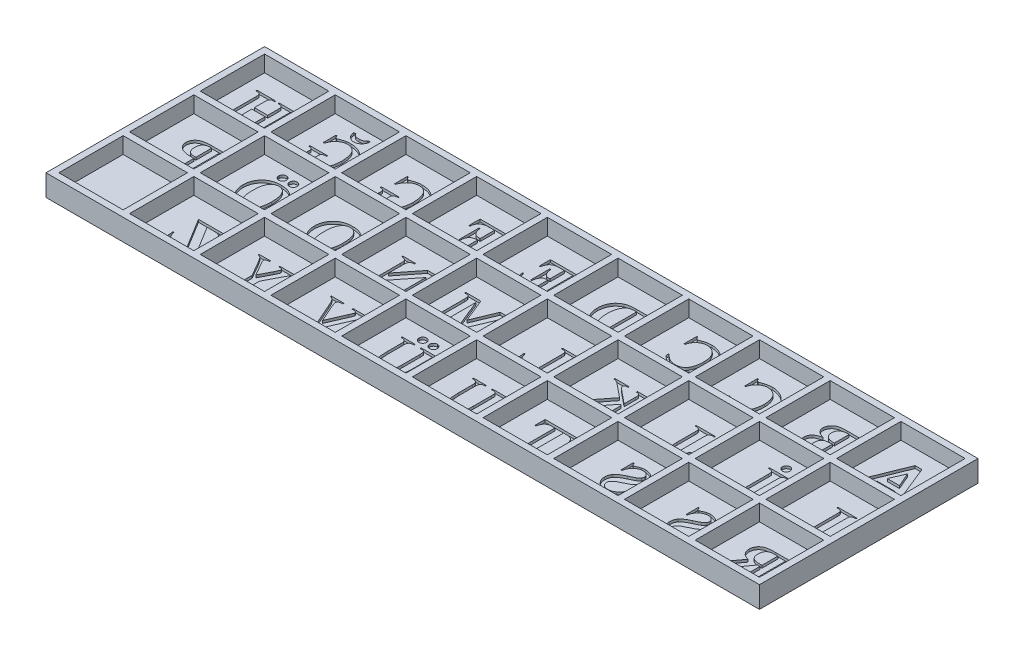
SolidWorks part; units mm, degrees
ref_plane "Ön Düzlem" through (0, 0, 0) normal (0, 0, 1) x (1, 0, 0)
ref_plane "Üst Düzlem" through (0, 0, 0) normal (0, 1, 0) x (1, 0, 0)
ref_plane "Sağ Düzlem" through (0, 0, 0) normal (1, 0, 0) x (0, 0, -1)
sketch "Çizim1" plane through (0, 0, 0) normal (0, 1, 0) x (1, 0, 0)
  line L9 (0, 0) -> (166.5, 0)
  line L10 (0, 0) -> (0, 51)
  line L11 (0, 51) -> (166.5, 51)
  line L12 (166.5, 0) -> (166.5, 51)
  dimension "D1" = 166.5
  dimension "D2" = 51
extrude "Yükseklik-Ekstrüzyon1" add sketch "Çizim1" along normal blind 1.2
sketch "Çizim2" plane through (0, 1.2, 0) normal (0, 1, 0) x (1, 0, 0)
  line L0 (0, 51) -> (0, 0) construction
  line L1 (1.5, 49.5) -> (16.5, 49.5) construction
  line L2 (1.5, 49.5) -> (1.5, 34.5) construction
  line L3 (1.5, 1.5) -> (16.5, 1.5) construction
  line L4 (165, 49.5) -> (165, 34.5) construction
  line L5 (166.5, 51) -> (0, 51) construction
  line L6 (0, 0) -> (166.5, 0) construction
  line L7 (166.5, 0) -> (166.5, 51) construction
  line L8 (16.5, 49.5) -> (16.5, 34.5) construction
  line L9 (18, 49.5) -> (18, 34.5) construction
  line L10 (33, 49.5) -> (33, 34.5) construction
  line L11 (34.5, 49.5) -> (34.5, 34.5) construction
  line L12 (49.5, 49.5) -> (49.5, 34.5) construction
  line L13 (51, 49.5) -> (51, 34.5) construction
  line L14 (66, 49.5) -> (66, 34.5) construction
  line L15 (67.5, 49.5) -> (67.5, 34.5) construction
  line L16 (82.5, 49.5) -> (82.5, 34.5) construction
  line L17 (84, 49.5) -> (84, 34.5) construction
  line L18 (99, 49.5) -> (99, 34.5) construction
  line L19 (100.5, 49.5) -> (100.5, 34.5) construction
  line L20 (115.5, 49.5) -> (115.5, 34.5) construction
  line L21 (117, 49.5) -> (117, 34.5) construction
  line L22 (132, 49.5) -> (132, 34.5) construction
  line L23 (133.5, 49.5) -> (133.5, 34.5) construction
  line L24 (148.5, 49.5) -> (148.5, 34.5) construction
  line L25 (150, 49.5) -> (150, 34.5) construction
  line L26 (1.5, 34.5) -> (16.5, 34.5) construction
  line L27 (1.5, 33) -> (16.5, 33) construction
  line L28 (1.5, 18) -> (16.5, 18) construction
  line L29 (1.5, 16.5) -> (16.5, 16.5) construction
  line L30 (18, 49.5) -> (33, 49.5) construction
  line L31 (18, 34.5) -> (33, 34.5) construction
  line L32 (18, 33) -> (33, 33) construction
  line L33 (16.5, 33) -> (16.5, 18) construction
  line L34 (18, 33) -> (18, 18) construction
  line L35 (1.5, 33) -> (1.5, 18) construction
  line L36 (1.5, 16.5) -> (1.5, 1.5) construction
  line L37 (16.5, 16.5) -> (16.5, 1.5) construction
  line L38 (18, 16.5) -> (18, 1.5) construction
  line L39 (18, 18) -> (33, 18) construction
  line L40 (18, 16.5) -> (33, 16.5) construction
  line L41 (18, 1.5) -> (33, 1.5) construction
  line L42 (34.5, 1.5) -> (49.5, 1.5) construction
  line L43 (34.5, 18) -> (49.5, 18) construction
  line L44 (34.5, 16.5) -> (49.5, 16.5) construction
  line L45 (33, 16.5) -> (33, 1.5) construction
  line L46 (34.5, 16.5) -> (34.5, 1.5) construction
  line L47 (51, 18) -> (66, 18) construction
  line L48 (51, 16.5) -> (66, 16.5) construction
  line L49 (49.5, 16.5) -> (49.5, 1.5) construction
  line L50 (51, 16.5) -> (51, 1.5) construction
  line L51 (51, 1.5) -> (66, 1.5) construction
  line L52 (67.5, 1.5) -> (82.5, 1.5) construction
  line L53 (67.5, 18) -> (82.5, 18) construction
  line L54 (67.5, 16.5) -> (82.5, 16.5) construction
  line L55 (66, 16.5) -> (66, 1.5) construction
  line L56 (67.5, 16.5) -> (67.5, 1.5) construction
  line L57 (84, 18) -> (99, 18) construction
  line L58 (84, 16.5) -> (99, 16.5) construction
  line L59 (82.5, 16.5) -> (82.5, 1.5) construction
  line L60 (84, 16.5) -> (84, 1.5) construction
  line L61 (100.5, 18) -> (115.5, 18) construction
  line L62 (100.5, 16.5) -> (115.5, 16.5) construction
  line L63 (99, 16.5) -> (99, 1.5) construction
  line L64 (100.5, 16.5) -> (100.5, 1.5) construction
  line L65 (100.5, 1.5) -> (115.5, 1.5) construction
  line L66 (117, 1.5) -> (132, 1.5) construction
  line L67 (117, 18) -> (132, 18) construction
  line L68 (117, 16.5) -> (132, 16.5) construction
  line L69 (115.5, 16.5) -> (115.5, 1.5) construction
  line L70 (117, 16.5) -> (117, 1.5) construction
  line L71 (133.5, 18) -> (148.5, 18) construction
  line L72 (133.5, 16.5) -> (148.5, 16.5) construction
  line L73 (132, 16.5) -> (132, 1.5) construction
  line L74 (133.5, 16.5) -> (133.5, 1.5) construction
  line L75 (133.5, 1.5) -> (148.5, 1.5) construction
  line L76 (150, 1.5) -> (165, 1.5) construction
  line L77 (150, 18) -> (165, 18) construction
  line L78 (150, 16.5) -> (165, 16.5) construction
  line L79 (148.5, 16.5) -> (148.5, 1.5) construction
  line L80 (150, 16.5) -> (150, 1.5) construction
  line L81 (165, 16.5) -> (165, 1.5) construction
  line L82 (165, 33) -> (165, 18) construction
  line L83 (150, 33) -> (150, 18) construction
  line L84 (148.5, 33) -> (148.5, 18) construction
  line L85 (150, 34.5) -> (165, 34.5) construction
  line L86 (150, 33) -> (165, 33) construction
  line L87 (150, 49.5) -> (165, 49.5) construction
  line L88 (133.5, 49.5) -> (148.5, 49.5) construction
  line L89 (133.5, 34.5) -> (148.5, 34.5) construction
  line L90 (133.5, 33) -> (148.5, 33) construction
  line L91 (132, 33) -> (132, 18) construction
  line L92 (133.5, 33) -> (133.5, 18) construction
  line L93 (117, 49.5) -> (132, 49.5) construction
  line L94 (115.5, 33) -> (115.5, 18) construction
  line L95 (117, 33) -> (117, 18) construction
  line L96 (117, 34.5) -> (132, 34.5) construction
  line L97 (117, 33) -> (132, 33) construction
  line L98 (100.5, 34.5) -> (115.5, 34.5) construction
  line L99 (100.5, 33) -> (115.5, 33) construction
  line L100 (99, 33) -> (99, 18) construction
  line L101 (100.5, 33) -> (100.5, 18) construction
  line L102 (100.5, 49.5) -> (115.5, 49.5) construction
  line L103 (84, 49.5) -> (99, 49.5) construction
  line L104 (82.5, 33) -> (82.5, 18) construction
  line L105 (84, 33) -> (84, 18) construction
  line L106 (84, 34.5) -> (99, 34.5) construction
  line L107 (84, 33) -> (99, 33) construction
  line L108 (66, 33) -> (66, 18) construction
  line L109 (67.5, 33) -> (67.5, 18) construction
  line L110 (67.5, 34.5) -> (82.5, 34.5) construction
  line L111 (67.5, 33) -> (82.5, 33) construction
  line L112 (67.5, 49.5) -> (82.5, 49.5) construction
  line L113 (34.5, 49.5) -> (49.5, 49.5) construction
  line L114 (51, 49.5) -> (66, 49.5) construction
  line L115 (51, 33) -> (66, 33) construction
  line L116 (51, 34.5) -> (66, 34.5) construction
  line L117 (51, 33) -> (51, 18) construction
  line L118 (49.5, 33) -> (49.5, 18) construction
  line L119 (33, 33) -> (33, 18) construction
  line L120 (34.5, 33) -> (34.5, 18) construction
  line L121 (34.5, 34.5) -> (49.5, 34.5) construction
  line L122 (34.5, 33) -> (49.5, 33) construction
  line L123 (84, 1.5) -> (99, 1.5) construction
  line L124 (158.3822, 46.025) -> (156.7966, 46.025)
  line L125 (156.7966, 46.025) -> (152.9499, 36.5)
  line L126 (152.9499, 36.5) -> (154.7759, 36.5)
  line L127 (154.7759, 36.5) -> (155.5163, 38.4538)
  line L128 (155.5163, 38.4538) -> (159.6663, 38.4538)
  line L129 (159.6663, 38.4538) -> (160.4066, 36.5)
  line L130 (160.4066, 36.5) -> (162.2307, 36.5)
  line L131 (162.2307, 36.5) -> (158.3822, 46.025)
  line L132 (157.5903, 43.4701) -> (159.0176, 40.1635)
  line L133 (159.0176, 40.1635) -> (156.1631, 40.1635)
  line L134 (156.1631, 40.1635) -> (157.5903, 43.4701)
  line L135 (141.5773, 36.5) -> (145.917, 36.5)
  line L136 (145.917, 36.5) -> (145.917, 36.7389)
  line L137 (144.7224, 37.9335) -> (144.7224, 43.6675)
  line L138 (145.917, 44.8621) -> (145.917, 45.101)
  line L139 (145.917, 45.101) -> (141.805, 45.101)
  line L140 (142.8111, 44.6232) -> (142.8111, 41.1589)
  line L141 (142.8111, 40.6811) -> (142.8111, 37.969)
  line L142 (142.8111, 37.969) -> (142.8111, 37.6573)
  line L143 (120.8278, 45.2205) -> (120.8278, 42.234)
  line L144 (120.8278, 42.234) -> (121.0667, 42.234)
  line L145 (121.0667, 38.5327) -> (121.0667, 37.7954)
  line L146 (121.0667, 45.2205) -> (120.8278, 45.2205)
  line L147 (105.2192, 46.6682) -> (105.2192, 43.6817)
  line L148 (105.2192, 43.6817) -> (105.4581, 43.6817)
  line L149 (105.4581, 39.9804) -> (105.4581, 39.2431)
  line L150 (105.4581, 46.6682) -> (105.2192, 46.6682)
  line L152 (108.5305, 37.8332) -> (108.803, 37.4699)
  line L153 (110.117, 35.5585) -> (110.117, 35.9169)
  line L154 (109.6149, 36.9678) -> (109.0038, 37.8325)
  line L155 (96.4625, 36.5) -> (96.4625, 36.7389)
  line L156 (96.4625, 36.7389) -> (96.1806, 36.7389)
  line L157 (95.2679, 37.9335) -> (95.2679, 43.6675)
  line L158 (96.1806, 44.8621) -> (96.4625, 44.8621)
  line L159 (96.4625, 44.8621) -> (96.4625, 45.101)
  line L160 (96.4625, 45.101) -> (92.6398, 45.101)
  line L161 (92.6398, 36.5) -> (96.4625, 36.5)
  line L162 (93.2371, 44.6232) -> (93.2371, 37.9111)
  line L163 (76.4476, 44.5037) -> (76.4476, 41.1589)
  line L164 (76.4476, 41.1589) -> (76.2796, 41.1589)
  line L165 (74.6557, 43.1897) -> (74.4168, 43.1897)
  line L166 (74.4168, 43.1897) -> (74.4168, 38.6503)
  line L167 (74.4168, 38.6503) -> (74.6557, 38.6503)
  line L168 (76.4476, 40.6811) -> (76.4476, 38.2247)
  line L169 (75.6506, 36.9778) -> (75.1503, 36.9778)
  line L170 (72.2535, 39.2158) -> (72.0276, 39.2158)
  line L171 (72.0276, 39.2158) -> (72.4065, 36.5)
  line L172 (72.4065, 36.5) -> (79.673, 36.5)
  line L173 (79.673, 36.5) -> (79.673, 36.7389)
  line L174 (79.673, 36.7389) -> (79.3911, 36.7389)
  line L175 (78.4784, 37.9335) -> (78.4784, 43.6675)
  line L176 (79.3911, 44.8621) -> (79.673, 44.8621)
  line L177 (79.673, 44.8621) -> (79.673, 45.101)
  line L178 (79.673, 45.101) -> (72.6249, 45.101)
  line L179 (72.6249, 45.101) -> (72.6249, 42.4729)
  line L180 (72.6249, 42.4729) -> (72.8638, 42.4729)
  line L181 (75.6114, 44.5037) -> (76.4476, 44.5037)
  line L182 (60.1564, 44.5037) -> (60.1564, 41.1589)
  line L183 (60.1564, 41.1589) -> (59.9175, 41.1589)
  line L184 (58.1256, 43.1897) -> (57.8867, 43.1897)
  line L185 (57.8867, 43.1897) -> (57.8867, 38.5308)
  line L186 (57.8867, 38.5308) -> (58.1256, 38.5308)
  line L187 (59.9175, 40.5616) -> (60.1564, 40.5616)
  line L188 (60.1564, 40.5616) -> (60.1564, 37.9335)
  line L189 (59.2418, 36.7389) -> (58.9618, 36.7389)
  line L190 (58.9618, 36.7389) -> (58.9618, 36.5)
  line L191 (58.9618, 36.5) -> (63.3818, 36.5)
  line L192 (63.3818, 36.5) -> (63.3818, 36.7389)
  line L193 (63.3818, 36.7389) -> (63.1, 36.7389)
  line L194 (62.1872, 37.9335) -> (62.1872, 43.6675)
  line L195 (63.1, 44.8621) -> (63.3818, 44.8621)
  line L196 (63.3818, 44.8621) -> (63.3818, 45.101)
  line L197 (63.3818, 45.101) -> (56.2143, 45.101)
  line L198 (56.2143, 45.101) -> (56.2143, 42.4729)
  line L199 (56.2143, 42.4729) -> (56.4532, 42.4729)
  line L200 (59.3202, 44.5037) -> (60.1564, 44.5037)
  line L201 (39.1074, 45.2205) -> (39.1074, 42.234)
  line L202 (39.1074, 42.234) -> (39.3463, 42.234)
  line L203 (41.1382, 37.1104) -> (41.1382, 38.8892)
  line L204 (42.0939, 39.8448) -> (42.3328, 39.8448)
  line L205 (42.3328, 39.8448) -> (42.3328, 40.0838)
  line L206 (42.3328, 40.0838) -> (38.1517, 40.0838)
  line L207 (38.1517, 40.0838) -> (38.1517, 39.8448)
  line L208 (39.1074, 38.8892) -> (39.1074, 37.1104)
  line L209 (39.3463, 45.2205) -> (39.1074, 45.2205)
  line L210 (22.4374, 45.2205) -> (22.4374, 42.234)
  line L211 (22.4374, 42.234) -> (22.6763, 42.234)
  line L212 (24.4682, 37.1104) -> (24.4682, 38.8892)
  line L213 (25.4238, 39.8448) -> (25.6628, 39.8448)
  line L214 (25.6628, 39.8448) -> (25.6628, 40.0838)
  line L215 (25.6628, 40.0838) -> (21.4817, 40.0838)
  line L216 (21.4817, 40.0838) -> (21.4817, 39.8448)
  line L217 (22.4374, 38.8892) -> (22.4374, 37.1104)
  line L218 (22.6763, 45.2205) -> (22.4374, 45.2205)
  line L219 (24.4682, 47.8486) -> (23.9903, 47.8486)
  line L220 (27.813, 47.8486) -> (27.3352, 47.8486)
  line L221 (10.4552, 40.6811) -> (10.4552, 37.9335)
  line L222 (9.5406, 36.7389) -> (9.2606, 36.7389)
  line L223 (9.2606, 36.7389) -> (9.2606, 36.5)
  line L224 (9.2606, 36.5) -> (13.6806, 36.5)
  line L225 (13.6806, 36.5) -> (13.6806, 36.7389)
  line L226 (13.6806, 36.7389) -> (13.3988, 36.7389)
  line L227 (12.486, 37.9335) -> (12.486, 43.6675)
  line L228 (13.3988, 44.8621) -> (13.6806, 44.8621)
  line L229 (13.6806, 44.8621) -> (13.6806, 45.101)
  line L230 (13.6806, 45.101) -> (9.2606, 45.101)
  line L231 (9.2606, 45.101) -> (9.2606, 44.8621)
  line L232 (9.2606, 44.8621) -> (9.5406, 44.8621)
  line L233 (10.4552, 43.6675) -> (10.4552, 41.2783)
  line L234 (10.4552, 41.2783) -> (7.3493, 41.2783)
  line L235 (7.3493, 41.2783) -> (7.3493, 43.6675)
  line L236 (8.2695, 44.8621) -> (8.5439, 44.8621)
  line L237 (8.5439, 44.8621) -> (8.5439, 45.101)
  line L238 (8.5439, 45.101) -> (4.1239, 45.101)
  line L239 (4.1239, 45.101) -> (4.1239, 44.8621)
  line L240 (4.1239, 44.8621) -> (4.3983, 44.8621)
  line L241 (5.3185, 43.6675) -> (5.3185, 37.9335)
  line L242 (4.3983, 36.7389) -> (4.1239, 36.7389)
  line L243 (4.1239, 36.7389) -> (4.1239, 36.5)
  line L244 (4.1239, 36.5) -> (8.5439, 36.5)
  line L245 (8.5439, 36.5) -> (8.5439, 36.7389)
  line L246 (8.5439, 36.7389) -> (8.2695, 36.7389)
  line L247 (7.3493, 37.9335) -> (7.3493, 40.6811)
  line L248 (7.3493, 40.6811) -> (10.4552, 40.6811)
  line L249 (10.556, 23.9421) -> (10.556, 21.4335)
  line L250 (9.3614, 20.2389) -> (9.3614, 20)
  line L251 (9.3614, 20) -> (13.6619, 20)
  line L252 (13.6619, 20) -> (13.6619, 20.2389)
  line L253 (12.4674, 21.4335) -> (12.4674, 27.1675)
  line L254 (13.6619, 28.3621) -> (13.6619, 28.601)
  line L255 (13.6619, 28.601) -> (9.8841, 28.601)
  line L256 (10.556, 28.1232) -> (10.556, 24.42)
  line L257 (10.2686, 28.1232) -> (10.556, 28.1232)
  line L258 (60.4625, 28.601) -> (56.4532, 23.511)
  line L259 (56.4532, 23.511) -> (56.4532, 26.9286)
  line L260 (57.6478, 28.3621) -> (57.6478, 28.601)
  line L261 (57.6478, 28.601) -> (54.6613, 28.601)
  line L262 (54.6613, 28.601) -> (54.6613, 28.3621)
  line L263 (55.8559, 26.9286) -> (55.8559, 19.8805)
  line L264 (55.8559, 19.8805) -> (56.1303, 19.8805)
  line L265 (56.1303, 19.8805) -> (61.7094, 26.9678)
  line L266 (61.7094, 26.9678) -> (61.7094, 21.4335)
  line L267 (60.6977, 20.2389) -> (60.5148, 20.2389)
  line L268 (60.5148, 20.2389) -> (60.5148, 20)
  line L269 (60.5148, 20) -> (63.5013, 20)
  line L270 (63.5013, 20) -> (63.5013, 20.2389)
  line L271 (62.3067, 21.4335) -> (62.3067, 27.7238)
  line L272 (62.3067, 27.7238) -> (62.4093, 27.8525)
  line L273 (63.4863, 28.3621) -> (63.4863, 28.601)
  line L274 (63.4863, 28.601) -> (60.4625, 28.601)
  line L275 (75.1017, 23.1059) -> (72.8749, 28.601)
  line L276 (72.8749, 28.601) -> (69.3415, 28.601)
  line L277 (69.3415, 28.601) -> (69.3415, 28.3621)
  line L278 (69.3415, 28.3621) -> (69.6159, 28.3621)
  line L279 (70.5361, 27.1675) -> (70.5361, 21.4335)
  line L280 (69.6159, 20.2389) -> (69.3415, 20.2389)
  line L281 (69.3415, 20.2389) -> (69.3415, 20)
  line L282 (69.3415, 20) -> (73.7615, 20)
  line L283 (73.7615, 20) -> (73.7615, 20.2389)
  line L284 (73.7615, 20.2389) -> (73.4871, 20.2389)
  line L285 (72.5669, 21.4335) -> (72.5669, 27.7648)
  line L286 (72.5669, 27.7648) -> (75.727, 20)
  line L287 (75.727, 20) -> (75.8726, 20)
  line L288 (75.8726, 20) -> (79.0812, 27.6902)
  line L289 (79.0812, 27.6902) -> (79.0812, 21.6724)
  line L290 (77.8866, 20.2389) -> (77.8866, 20)
  line L291 (77.8866, 20) -> (80.873, 20)
  line L292 (80.873, 20) -> (80.873, 20.2389)
  line L293 (80.873, 20.2389) -> (80.7853, 20.2389)
  line L294 (79.6784, 21.6724) -> (79.6784, 27.1675)
  line L295 (80.6024, 28.3621) -> (80.873, 28.3621)
  line L296 (80.873, 28.3621) -> (80.873, 28.601)
  line L297 (80.873, 28.601) -> (77.3807, 28.601)
  line L298 (77.3807, 28.601) -> (75.1017, 23.1059)
  line L299 (88.4587, 23.1059) -> (88.8171, 20)
  line L300 (88.8171, 20) -> (96.343, 20)
  line L301 (96.343, 20) -> (96.343, 20.2389)
  line L302 (96.343, 20.2389) -> (96.0612, 20.2389)
  line L303 (95.1484, 21.4335) -> (95.1484, 27.1675)
  line L304 (96.0612, 28.3621) -> (96.343, 28.3621)
  line L305 (96.343, 28.3621) -> (96.343, 28.601)
  line L306 (96.343, 28.601) -> (91.923, 28.601)
  line L307 (91.923, 28.601) -> (91.923, 28.3621)
  line L308 (91.923, 28.3621) -> (92.2646, 28.3621)
  line L309 (93.1176, 27.1675) -> (93.1176, 21.7508)
  line L310 (91.9772, 20.5973) -> (91.2604, 20.5973)
  line L311 (88.6977, 23.1059) -> (88.4587, 23.1059)
  line L312 (108.5771, 25.2692) -> (105.6037, 21.4839)
  line L313 (103.8025, 20.2389) -> (103.8025, 20)
  line L314 (103.8025, 20) -> (108.1833, 20)
  line L315 (108.1833, 20) -> (108.1833, 20.2389)
  line L316 (108.0956, 21.6052) -> (110.0405, 24.0803)
  line L317 (110.0405, 24.0803) -> (110.3578, 23.8189)
  line L318 (110.3578, 23.8189) -> (110.3578, 21.4335)
  line L319 (109.4021, 20.2389) -> (109.4021, 20)
  line L320 (109.4021, 20) -> (113.5832, 20)
  line L321 (113.5832, 20) -> (113.5832, 20.2389)
  line L322 (113.5832, 20.2389) -> (113.3014, 20.2389)
  line L323 (112.3886, 21.4335) -> (112.3886, 27.1675)
  line L324 (113.3014, 28.3621) -> (113.5832, 28.3621)
  line L325 (113.5832, 28.3621) -> (113.5832, 28.601)
  line L326 (113.5832, 28.601) -> (109.4021, 28.601)
  line L327 (109.4021, 28.601) -> (109.4021, 28.3621)
  line L328 (110.3578, 27.1675) -> (110.3578, 24.5525)
  line L329 (110.3578, 24.5525) -> (107.2482, 27.0854)
  line L330 (107.5449, 28.3621) -> (107.5449, 28.601)
  line L331 (107.5449, 28.601) -> (104.1758, 28.601)
  line L332 (104.1758, 28.601) -> (104.1758, 28.3621)
  line L333 (106.0536, 27.3262) -> (108.5771, 25.2692)
  line L334 (127.6369, 28.3621) -> (127.6369, 28.601)
  line L335 (127.6369, 28.601) -> (123.0975, 28.601)
  line L336 (123.0975, 28.601) -> (123.0975, 28.3621)
  line L337 (123.0975, 28.3621) -> (123.3719, 28.3621)
  line L338 (124.2921, 27.1675) -> (124.2921, 22.979)
  line L339 (126.3229, 22.5702) -> (126.3229, 27.1675)
  line L340 (127.2692, 28.3621) -> (127.6369, 28.3621)
  line L341 (140.2217, 20.2389) -> (140.2217, 20)
  line L342 (140.2217, 20) -> (144.6416, 20)
  line L343 (144.6416, 20) -> (144.6416, 20.2389)
  line L344 (144.6416, 20.2389) -> (144.3598, 20.2389)
  line L345 (143.447, 21.4335) -> (143.447, 27.1675)
  line L346 (144.3598, 28.3621) -> (144.6416, 28.3621)
  line L347 (144.6416, 28.3621) -> (144.6416, 28.601)
  line L348 (144.6416, 28.601) -> (140.2217, 28.601)
  line L349 (140.2217, 28.601) -> (140.2217, 28.3621)
  line L350 (140.2217, 28.3621) -> (140.5016, 28.3621)
  line L351 (141.4162, 27.1675) -> (141.4162, 21.4335)
  line L352 (140.5016, 20.2389) -> (140.2217, 20.2389)
  line L353 (156.2217, 20.2389) -> (156.2217, 20)
  line L354 (156.2217, 20) -> (160.6416, 20)
  line L355 (160.6416, 20) -> (160.6416, 20.2389)
  line L356 (160.6416, 20.2389) -> (160.3598, 20.2389)
  line L357 (159.447, 21.4335) -> (159.447, 27.1675)
  line L358 (160.3598, 28.3621) -> (160.6416, 28.3621)
  line L359 (160.6416, 28.3621) -> (160.6416, 28.601)
  line L360 (160.6416, 28.601) -> (156.2217, 28.601)
  line L361 (156.2217, 28.601) -> (156.2217, 28.3621)
  line L362 (156.2217, 28.3621) -> (156.5016, 28.3621)
  line L363 (157.4162, 27.1675) -> (157.4162, 21.4335)
  line L364 (156.5016, 20.2389) -> (156.2217, 20.2389)
  line L365 (159.069, 7.5264) -> (159.069, 5.0178)
  line L366 (157.8745, 3.8232) -> (157.8745, 3.5843)
  line L367 (157.8745, 3.5843) -> (162.175, 3.5843)
  line L368 (162.175, 3.5843) -> (162.175, 3.8232)
  line L369 (160.9804, 5.0178) -> (160.9804, 10.7518)
  line L370 (162.175, 11.9464) -> (162.175, 12.1853)
  line L371 (162.175, 12.1853) -> (158.1955, 12.1853)
  line L372 (156.2058, 7.6048) -> (154.1358, 4.7453)
  line L373 (152.9766, 3.8232) -> (152.9766, 3.5843)
  line L374 (152.9766, 3.5843) -> (155.6234, 3.5843)
  line L375 (155.6234, 3.5843) -> (158.4773, 7.5264)
  line L376 (158.4773, 7.5264) -> (159.069, 7.5264)
  line L377 (159.069, 11.7075) -> (159.069, 8.0043)
  line L378 (159.069, 8.0043) -> (158.6901, 8.0043)
  line L379 (158.3579, 11.7075) -> (159.069, 11.7075)
  line L380 (139.9497, 12.3048) -> (139.9497, 9.4378)
  line L381 (139.9497, 9.4378) -> (140.1886, 9.4378)
  line L382 (145.2058, 3.4648) -> (145.4448, 3.4648)
  line L383 (145.4448, 3.4648) -> (145.4448, 6.6902)
  line L384 (145.4448, 6.6902) -> (145.2058, 6.6902)
  line L385 (140.1886, 12.3048) -> (139.9497, 12.3048)
  line L386 (123.3364, 13.7205) -> (123.3364, 10.8535)
  line L387 (123.3364, 10.8535) -> (123.5753, 10.8535)
  line L388 (128.5926, 4.8805) -> (128.8315, 4.8805)
  line L389 (128.8315, 4.8805) -> (128.8315, 8.1059)
  line L390 (128.8315, 8.1059) -> (128.5926, 8.1059)
  line L391 (123.5753, 13.7205) -> (123.3364, 13.7205)
  line L393 (125.5724, 4.8857) -> (125.8451, 4.5222)
  line L394 (127.1591, 2.6108) -> (127.1591, 2.9692)
  line L395 (126.657, 4.0201) -> (126.0419, 4.8905)
  line L396 (104.3011, 12.1853) -> (104.3011, 9.7961)
  line L397 (104.3011, 9.7961) -> (104.54, 9.7961)
  line L398 (106.4513, 11.588) -> (107.1681, 11.588)
  line L399 (107.1681, 11.588) -> (107.1681, 5.0178)
  line L400 (106.2516, 3.8232) -> (105.9735, 3.8232)
  line L401 (105.9735, 3.8232) -> (105.9735, 3.5843)
  line L402 (105.9735, 3.5843) -> (110.3935, 3.5843)
  line L403 (110.3935, 3.5843) -> (110.3935, 3.8232)
  line L404 (110.3935, 3.8232) -> (110.1135, 3.8232)
  line L405 (109.1989, 5.0178) -> (109.1989, 11.588)
  line L406 (109.1989, 11.588) -> (109.9156, 11.588)
  line L407 (111.827, 9.7961) -> (112.0659, 9.7961)
  line L408 (112.0659, 9.7961) -> (112.0659, 12.1853)
  line L409 (112.0659, 12.1853) -> (104.3011, 12.1853)
  line L410 (96.4625, 12.1853) -> (92.0425, 12.1853)
  line L411 (92.0425, 12.1853) -> (92.0425, 11.9464)
  line L412 (92.0425, 11.9464) -> (92.2534, 11.9464)
  line L413 (93.2371, 10.7518) -> (93.2371, 6.4886)
  line L414 (89.4144, 7.2016) -> (89.4144, 10.7518)
  line L415 (90.609, 11.9464) -> (90.609, 12.1853)
  line L416 (90.609, 12.1853) -> (87.6225, 12.1853)
  line L417 (87.6225, 12.1853) -> (87.6225, 11.9464)
  line L418 (87.6225, 11.9464) -> (87.798, 11.9464)
  line L419 (88.8171, 10.7518) -> (88.8171, 7.4723)
  line L420 (95.2679, 6.5222) -> (95.2679, 10.7518)
  line L421 (96.4625, 11.9464) -> (96.4625, 12.1853)
  line L422 (79.7924, 12.1853) -> (75.3725, 12.1853)
  line L423 (75.3725, 12.1853) -> (75.3725, 11.9464)
  line L424 (75.3725, 11.9464) -> (75.5834, 11.9464)
  line L425 (76.5671, 10.7518) -> (76.5671, 6.4886)
  line L426 (72.7444, 7.2016) -> (72.7444, 10.7518)
  line L427 (73.939, 11.9464) -> (73.939, 12.1853)
  line L428 (73.939, 12.1853) -> (70.9525, 12.1853)
  line L429 (70.9525, 12.1853) -> (70.9525, 11.9464)
  line L430 (70.9525, 11.9464) -> (71.1279, 11.9464)
  line L431 (72.1471, 10.7518) -> (72.1471, 7.4723)
  line L432 (78.5979, 6.5222) -> (78.5979, 10.7518)
  line L433 (79.7924, 11.9464) -> (79.7924, 12.1853)
  line L434 (54.4205, 12.1853) -> (54.4205, 11.9464)
  line L435 (56.0388, 9.9287) -> (58.8778, 3.4648)
  line L436 (58.8778, 3.4648) -> (59.2045, 3.4648)
  line L437 (59.2045, 3.4648) -> (62.1555, 10.2777)
  line L438 (63.5405, 11.9464) -> (63.5405, 12.1853)
  line L439 (63.5405, 12.1853) -> (59.5087, 12.1853)
  line L440 (59.5087, 12.1853) -> (59.5087, 11.9464)
  line L441 (59.5087, 11.9464) -> (59.6469, 11.9464)
  line L442 (60.1415, 10.4046) -> (58.3179, 6.1993)
  line L443 (58.3179, 6.1993) -> (56.6847, 9.9156)
  line L444 (57.3323, 11.9464) -> (57.3323, 12.1853)
  line L445 (57.3323, 12.1853) -> (54.4205, 12.1853)
  line L446 (37.5471, 12.1853) -> (37.5471, 11.9464)
  line L447 (39.1915, 10.2385) -> (40.9834, 7.112)
  line L448 (40.9834, 7.112) -> (40.9834, 5.0178)
  line L449 (40.2069, 3.8232) -> (39.7888, 3.8232)
  line L450 (39.7888, 3.8232) -> (39.7888, 3.5843)
  line L451 (39.7888, 3.5843) -> (44.2088, 3.5843)
  line L452 (44.2088, 3.5843) -> (44.2088, 3.8232)
  line L453 (44.2088, 3.8232) -> (43.8206, 3.8232)
  line L454 (43.0142, 5.0178) -> (43.0142, 6.7593)
  line L455 (43.0142, 6.7593) -> (44.9255, 10.4569)
  line L456 (46.4244, 11.9464) -> (46.4244, 12.1853)
  line L457 (46.4244, 12.1853) -> (42.4094, 12.1853)
  line L458 (42.4094, 12.1853) -> (42.4094, 11.9464)
  line L459 (42.4094, 11.9464) -> (42.5924, 11.9464)
  line L460 (42.7566, 10.3673) -> (41.3399, 7.6533)
  line L461 (41.3399, 7.6533) -> (39.8597, 10.2086)
  line L462 (40.2368, 11.9464) -> (40.2368, 12.1853)
  line L463 (40.2368, 12.1853) -> (37.5471, 12.1853)
  line L464 (23.4024, 12.1853) -> (28.3207, 4.1816)
  line L465 (28.3207, 4.1816) -> (26.736, 4.1816)
  line L466 (23.1709, 6.6902) -> (22.9245, 6.6902)
  line L467 (22.9245, 6.6902) -> (23.2642, 3.5843)
  line L468 (23.2642, 3.5843) -> (30.9283, 3.5843)
  line L469 (30.9283, 3.5843) -> (26.0099, 11.588)
  line L470 (26.0099, 11.588) -> (27.2698, 11.588)
  line L471 (30.0977, 9.5535) -> (30.331, 9.5535)
  line L472 (30.331, 9.5535) -> (30.0921, 12.1853)
  line L473 (30.0921, 12.1853) -> (23.4024, 12.1853)
  spline S0 degree 3 poles (140.3883, 40.9928) (140.2051, 40.9474) (139.9397, 40.8802) (139.6057, 40.7687) (139.3865, 40.6853) (139.1881, 40.5999) (138.9651, 40.4829) (138.8121, 40.3864) (138.7252, 40.3115) knots 0 0 0 0 0.312803 0.452951 0.583113 0.701263 0.810519 1 1 1 1
  spline S1 degree 3 poles (138.7252, 40.3115) (138.6152, 40.2199) (138.4646, 40.0692) (138.3041, 39.8397) (138.2059, 39.6598) (138.1319, 39.4681) (138.0571, 39.1959) (138.0398, 38.9813) (138.0383, 38.8369) knots 0 0 0 0 0.255133 0.376925 0.497963 0.619427 0.742329 1 1 1 1
  spline S2 degree 3 poles (138.0383, 38.8369) (138.0358, 38.683) (138.0622, 38.4561) (138.1418, 38.1652) (138.2289, 37.9617) (138.3375, 37.7676) (138.5199, 37.5192) (138.6907, 37.3573) (138.8129, 37.2559) knots 0 0 0 0 0.252484 0.373617 0.494651 0.615581 0.738558 1 1 1 1
  spline S3 degree 3 poles (138.8129, 37.2559) (138.9762, 37.1256) (139.2504, 36.9595) (139.6509, 36.7876) (139.9848, 36.6817) (140.3454, 36.6011) (140.8772, 36.5183) (141.2925, 36.4999) (141.5773, 36.5) knots 0 0 0 0 0.214322 0.327764 0.447285 0.573872 0.707186 1 1 1 1
  spline S4 degree 3 poles (145.917, 36.7389) (145.7493, 36.737) (145.5212, 36.7463) (145.2504, 36.7893) (145.1125, 36.8342) (145.0095, 36.8939) (144.9249, 36.9577) (144.858, 37.0307) (144.8119, 37.0996) (144.7852, 37.1658) (144.769, 37.2312) (144.7547, 37.311) (144.7414, 37.4062) (144.7325, 37.5165) (144.7255, 37.6939) (144.7229, 37.8346) (144.7224, 37.9335) knots 0 0 0 0 0.244047 0.331433 0.398438 0.453582 0.503931 0.55199 0.5972 0.623598 0.655445 0.695048 0.74166 0.795274 0.856001 1 1 1 1
  spline S5 degree 3 poles (144.7224, 43.6675) (144.7229, 43.7665) (144.7255, 43.9071) (144.7325, 44.0845) (144.7415, 44.1948) (144.7546, 44.29) (144.7694, 44.3704) (144.7849, 44.4366) (144.8123, 44.5037) (144.8573, 44.5738) (144.9253, 44.6475) (145.011, 44.7111) (145.1164, 44.7678) (145.2539, 44.8138) (145.5238, 44.8567) (145.7507, 44.862) (145.917, 44.8621) knots 0 0 0 0 0.143879 0.204556 0.258126 0.304699 0.34427 0.376965 0.403342 0.449278 0.497296 0.548322 0.603777 0.670726 0.758039 1 1 1 1
  spline S6 degree 3 poles (141.805, 45.101) (141.5772, 45.1024) (141.249, 45.0935) (140.8295, 45.0666) (140.5556, 45.0365) (140.308, 45.0005) (140.0876, 44.9534) (139.8926, 44.9015) (139.6728, 44.8161) (139.4281, 44.6916) (139.1672, 44.5066) (138.9389, 44.2877) (138.7461, 44.0387) (138.5923, 43.7693) (138.4391, 43.3972) (138.3983, 43.0988) (138.3967, 42.9022) knots 0 0 0 0 0.148922 0.214558 0.274699 0.329 0.378059 0.421972 0.460722 0.532028 0.600869 0.669045 0.738035 0.805988 0.871319 1 1 1 1
  spline S7 degree 3 poles (138.3967, 42.9022) (138.3969, 42.799) (138.4113, 42.6456) (138.4552, 42.4464) (138.5056, 42.3034) (138.5659, 42.1631) (138.644, 42.0284) (138.7334, 41.8977) (138.8367, 41.7706) (138.9593, 41.6512) (139.1006, 41.5362) (139.2637, 41.428) (139.4486, 41.3282) (139.6543, 41.235) (139.9652, 41.1111) (140.2151, 41.0375) (140.3883, 40.9928) knots 0 0 0 0 0.10323 0.153666 0.203666 0.254671 0.306247 0.35908 0.413038 0.46982 0.529998 0.595084 0.665281 0.739928 0.820958 1 1 1 1
  spline S8 degree 3 poles (142.8111, 41.1589) (142.6599, 41.1603) (142.4404, 41.1636) (142.1593, 41.1871) (141.9725, 41.2092) (141.8015, 41.2366) (141.6462, 41.2718) (141.5064, 41.3143) (141.3439, 41.3782) (141.163, 41.4735) (140.9717, 41.61) (140.806, 41.767) (140.6679, 41.9466) (140.5576, 42.1508) (140.4532, 42.4709) (140.4258, 42.7308) (140.4275, 42.9097) knots 0 0 0 0 0.133929 0.194178 0.24966 0.300465 0.34737 0.390584 0.429661 0.501859 0.570955 0.637192 0.703191 0.770721 0.841621 1 1 1 1
  spline S9 degree 3 poles (140.4275, 42.9097) (140.4287, 43.0879) (140.4497, 43.3485) (140.5563, 43.6663) (140.6639, 43.8692) (140.8005, 44.0467) (140.9629, 44.2016) (141.1522, 44.3327) (141.3295, 44.4238) (141.4898, 44.4827) (141.6284, 44.5213) (141.7835, 44.5551) (141.9563, 44.5803) (142.1457, 44.6004) (142.4324, 44.6217) (142.6562, 44.6228) (142.8111, 44.6232) knots 0 0 0 0 0.158767 0.229365 0.296358 0.361788 0.42745 0.494902 0.565582 0.60387 0.646376 0.693307 0.744731 0.801421 0.862367 1 1 1 1
  spline S10 degree 3 poles (142.8111, 37.6573) (142.809, 37.5585) (142.7966, 37.4132) (142.7189, 37.2453) (142.6415, 37.146) (142.5404, 37.0691) (142.3695, 36.9933) (142.2226, 36.9788) (142.1223, 36.9778) knots 0 0 0 0 0.270138 0.3856 0.497303 0.60797 0.726496 1 1 1 1
  spline S11 degree 3 poles (142.1223, 36.9778) (141.9588, 36.9752) (141.7164, 37.0054) (141.4073, 37.0984) (141.1889, 37.1949) (140.9876, 37.3188) (140.8099, 37.4702) (140.6566, 37.6461) (140.5301, 37.8459) (140.4329, 38.0649) (140.331, 38.3766) (140.3114, 38.626) (140.308, 38.7921) knots 0 0 0 0 0.169854 0.252425 0.335351 0.417667 0.497613 0.577491 0.659603 0.742794 0.826368 1 1 1 1
  spline S12 degree 3 poles (140.308, 38.7921) (140.3095, 38.9819) (140.3296, 39.2621) (140.4169, 39.6182) (140.5042, 39.8626) (140.6233, 40.0856) (140.79, 40.2716) (140.9997, 40.4148) (141.2025, 40.5024) (141.3852, 40.5547) (141.5409, 40.5902) (141.713, 40.6197) (141.9011, 40.6434) (142.1052, 40.6627) (142.4103, 40.676) (142.6473, 40.6827) (142.8111, 40.6811) knots 0 0 0 0 0.154584 0.226992 0.297587 0.365312 0.431243 0.498481 0.570306 0.609855 0.652939 0.70019 0.751718 0.807103 0.866888 1 1 1 1
  spline S13 degree 3 poles (121.0667, 42.234) (121.1136, 42.4185) (121.1934, 42.6887) (121.3449, 43.0247) (121.4688, 43.2565) (121.6098, 43.4704) (121.765, 43.668) (121.9376, 43.8473) (122.1238, 44.0096) (122.3216, 44.1523) (122.5254, 44.2781) (122.7356, 44.3853) (122.9526, 44.4737) (123.177, 44.541) (123.4873, 44.6024) (123.7249, 44.6253) (123.8852, 44.6232) knots 0 0 0 0 0.14278 0.210175 0.275872 0.339478 0.401866 0.463844 0.525628 0.586697 0.646335 0.704913 0.763253 0.821651 0.880156 1 1 1 1
  spline S14 degree 3 poles (123.8852, 44.6232) (124.0193, 44.6224) (124.22, 44.6097) (124.4824, 44.5626) (124.673, 44.5116) (124.8597, 44.4478) (125.0417, 44.3695) (125.2204, 44.2776) (125.3926, 44.1714) (125.5575, 44.0552) (125.7117, 43.9287) (125.8558, 43.7952) (125.9869, 43.6504) (126.106, 43.4971) (126.2526, 43.2822) (126.3392, 43.1065) (126.3938, 42.9881) knots 0 0 0 0 0.127061 0.189934 0.252104 0.313781 0.376604 0.439588 0.503858 0.568108 0.630501 0.692616 0.753931 0.815222 0.876342 1 1 1 1
  spline S15 degree 3 poles (126.3938, 42.9881) (126.4632, 42.8315) (126.5492, 42.5882) (126.6455, 42.256) (126.6998, 41.998) (126.7458, 41.7342) (126.7869, 41.3696) (126.8034, 41.0921) (126.8007, 40.905) knots 0 0 0 0 0.240215 0.361858 0.485196 0.610109 0.737612 1 1 1 1
  spline S16 degree 3 poles (126.8007, 40.905) (126.7991, 40.5453) (126.7692, 40.0146) (126.6436, 39.3317) (126.5394, 38.9317) (126.4346, 38.6294) (126.3451, 38.4188) (126.2462, 38.2222) (126.1376, 38.0397) (126.0178, 37.8711) (125.8874, 37.7162) (125.747, 37.5756) (125.5961, 37.449) (125.4346, 37.3372) (125.2603, 37.2415) (125.076, 37.1586) (124.8784, 37.0945) (124.6709, 37.0416) (124.3719, 36.9911) (124.14, 36.978) (123.9822, 36.9778) knots 0 0 0 0 0.196709 0.289323 0.379037 0.422256 0.463992 0.503975 0.542394 0.579936 0.616845 0.652901 0.688374 0.7243 0.760059 0.796887 0.834512 0.873427 0.913777 1 1 1 1
  spline S17 degree 3 poles (123.9822, 36.9778) (123.7202, 36.9787) (123.3311, 37.0191) (122.8368, 37.1666) (122.5455, 37.2949) (122.3184, 37.4223) (122.1456, 37.5346) (121.9693, 37.6615) (121.7934, 37.8061) (121.6122, 37.9628) (121.3664, 38.2036) (121.1865, 38.3976) (121.0667, 38.5327) knots 0 0 0 0 0.229831 0.340291 0.451181 0.508088 0.568464 0.631754 0.698464 0.768052 0.841738 1 1 1 1
  spline S18 degree 3 poles (121.0667, 37.7954) (121.2943, 37.562) (121.6518, 37.2422) (122.1756, 36.9052) (122.5688, 36.7064) (122.9843, 36.5593) (123.592, 36.4168) (124.0723, 36.3796) (124.4003, 36.3805) knots 0 0 0 0 0.262038 0.383205 0.49943 0.615147 0.73637 1 1 1 1
  spline S19 degree 3 poles (124.4003, 36.3805) (124.6233, 36.3828) (124.9547, 36.3955) (125.3874, 36.4535) (125.6981, 36.514) (125.9997, 36.5876) (126.2907, 36.6811) (126.5722, 36.7923) (126.8442, 36.9178) (127.1026, 37.0623) (127.3492, 37.2178) (127.5763, 37.3938) (127.793, 37.5791) (127.9899, 37.784) (128.1742, 38.001) (128.3424, 38.2332) (128.4944, 38.4788) (128.6305, 38.7337) (128.748, 38.9951) (128.8474, 39.2607) (128.9275, 39.5303) (128.9909, 39.8033) (129.0551, 40.1738) (129.0686, 40.4568) (129.0704, 40.6456) knots 0 0 0 0 0.094348 0.140011 0.184496 0.228149 0.271256 0.31367 0.356051 0.397865 0.438814 0.479181 0.519282 0.559291 0.59925 0.639568 0.680458 0.721307 0.761704 0.801588 0.841133 0.88058 0.920076 1 1 1 1
  spline S20 degree 3 poles (129.0704, 40.6456) (129.0731, 40.8449) (129.0489, 41.1428) (128.9825, 41.535) (128.9114, 41.8244) (128.8195, 42.1094) (128.7066, 42.3903) (128.5746, 42.6682) (128.4215, 42.9395) (128.2523, 43.2021) (128.0682, 43.4519) (127.8693, 43.6863) (127.6568, 43.9055) (127.4272, 44.1066) (127.1871, 44.2966) (126.9302, 44.4677) (126.6622, 44.6241) (126.3849, 44.764) (126.1006, 44.8845) (125.813, 44.9909) (125.52, 45.0737) (125.2235, 45.1399) (124.8207, 45.2021) (124.5141, 45.2207) (124.3089, 45.2205) knots 0 0 0 0 0.081492 0.122062 0.162704 0.203376 0.244519 0.286553 0.329198 0.371935 0.414364 0.456103 0.497704 0.539199 0.580923 0.62295 0.665405 0.707887 0.749988 0.79172 0.833313 0.874526 0.916019 1 1 1 1
  spline S21 degree 3 poles (124.3089, 45.2205) (123.9923, 45.2174) (123.3299, 45.1548) (122.694, 44.9597) (122.3696, 44.8434) knots 0 0 0 0 0.478534 1 1 1 1
  spline S22 degree 3 poles (122.3696, 44.8434) (122.2808, 44.8087) (122.1533, 44.7637) (121.9918, 44.7098) (121.8912, 44.6805) (121.8043, 44.6558) (121.7162, 44.6321) (121.6549, 44.625) (121.6192, 44.6232) knots 0 0 0 0 0.364439 0.517238 0.651294 0.765073 0.863213 1 1 1 1
  spline S23 degree 3 poles (121.6192, 44.6232) (121.5541, 44.6244) (121.455, 44.6395) (121.3387, 44.7016) (121.2583, 44.7641) (121.1881, 44.8481) (121.1098, 44.9981) (121.0818, 45.1293) (121.0667, 45.2205) knots 0 0 0 0 0.218775 0.326717 0.43784 0.557443 0.689611 1 1 1 1
  spline S24 degree 3 poles (105.4581, 43.6817) (105.505, 43.8662) (105.5848, 44.1364) (105.7363, 44.4724) (105.8602, 44.7042) (106.0013, 44.9181) (106.1565, 45.1157) (106.329, 45.295) (106.5153, 45.4573) (106.713, 45.6) (106.9168, 45.7258) (107.127, 45.833) (107.344, 45.9214) (107.5685, 45.9887) (107.8788, 46.0501) (108.1164, 46.073) (108.2766, 46.0709) knots 0 0 0 0 0.14278 0.210175 0.275872 0.339478 0.401866 0.463844 0.525628 0.586697 0.646335 0.704913 0.763253 0.821651 0.880156 1 1 1 1
  spline S25 degree 3 poles (108.2766, 46.0709) (108.4108, 46.0701) (108.6115, 46.0574) (108.8738, 46.0103) (109.0645, 45.9593) (109.2511, 45.8955) (109.4331, 45.8172) (109.6118, 45.7254) (109.784, 45.6191) (109.949, 45.5029) (110.1032, 45.3764) (110.2473, 45.2429) (110.3783, 45.0981) (110.4974, 44.9449) (110.644, 44.7299) (110.7306, 44.5542) (110.7853, 44.4358) knots 0 0 0 0 0.127061 0.189934 0.252104 0.313781 0.376604 0.439588 0.503858 0.568108 0.630501 0.692616 0.753931 0.815222 0.876342 1 1 1 1
  spline S26 degree 3 poles (110.7853, 44.4358) (110.8547, 44.2792) (110.9406, 44.0359) (111.037, 43.7038) (111.0912, 43.4457) (111.1373, 43.1819) (111.1784, 42.8173) (111.1948, 42.5398) (111.1922, 42.3528) knots 0 0 0 0 0.240215 0.361858 0.485196 0.610109 0.737612 1 1 1 1
  spline S27 degree 3 poles (111.1922, 42.3528) (111.1905, 41.993) (111.1606, 41.4624) (111.035, 40.7794) (110.9308, 40.3794) (110.8261, 40.0772) (110.7365, 39.8666) (110.6377, 39.67) (110.529, 39.4874) (110.4093, 39.3188) (110.2788, 39.164) (110.1384, 39.0233) (109.9876, 38.8968) (109.826, 38.7849) (109.6517, 38.6892) (109.4674, 38.6064) (109.2698, 38.5422) (109.0624, 38.4893) (108.7634, 38.4389) (108.5315, 38.4257) (108.3737, 38.4256) knots 0 0 0 0 0.196709 0.289323 0.379037 0.422256 0.463992 0.503975 0.542394 0.579936 0.616845 0.652901 0.688374 0.7243 0.760059 0.796887 0.834512 0.873427 0.913777 1 1 1 1
  spline S28 degree 3 poles (108.3737, 38.4256) (108.1117, 38.4264) (107.7225, 38.4668) (107.2282, 38.6143) (106.9369, 38.7426) (106.7098, 38.87) (106.537, 38.9823) (106.3607, 39.1092) (106.1848, 39.2538) (106.0036, 39.4105) (105.7579, 39.6514) (105.5779, 39.8453) (105.4581, 39.9804) knots 0 0 0 0 0.229831 0.340291 0.451181 0.508088 0.568464 0.631754 0.698464 0.768052 0.841738 1 1 1 1
  spline S29 degree 3 poles (105.4581, 39.2431) (105.6857, 39.0097) (106.0433, 38.69) (106.567, 38.3529) (106.9602, 38.1541) (107.3757, 38.007) (107.8189, 37.9031) (108.2081, 37.8518) (108.4489, 37.8366) (108.5305, 37.8332) knots 0 0 0 0 0.262038 0.383205 0.49943 0.615147 0.73637 0.864447 0.930023 0.930023 0.930023 0.930023
  spline S30 degree 3 poles (109.0038, 37.8325) (109.0464, 37.8339) (109.1987, 37.8398) (109.4585, 37.8583) (109.7788, 37.9012) (110.0895, 37.9617) (110.3912, 38.0353) (110.6822, 38.1289) (110.9636, 38.24) (111.2357, 38.3655) (111.4941, 38.51) (111.7406, 38.6655) (111.9677, 38.8415) (112.1844, 39.0268) (112.3814, 39.2318) (112.5656, 39.4487) (112.7339, 39.6809) (112.8859, 39.9265) (113.022, 40.1814) (113.1395, 40.4429) (113.2389, 40.7084) (113.319, 40.978) (113.3824, 41.2511) (113.4466, 41.6215) (113.46, 41.9045) (113.4619, 42.0933) knots 0.029902 0.029902 0.029902 0.029902 0.047909 0.094348 0.140011 0.184496 0.228149 0.271256 0.31367 0.356051 0.397865 0.438814 0.479181 0.519282 0.559291 0.59925 0.639568 0.680458 0.721307 0.761704 0.801588 0.841133 0.88058 0.920076 1 1 1 1
  spline S31 degree 3 poles (113.4619, 42.0933) (113.4645, 42.2926) (113.4404, 42.5905) (113.3739, 42.9827) (113.3029, 43.2721) (113.2109, 43.5571) (113.098, 43.838) (112.9661, 44.1159) (112.8129, 44.3872) (112.6437, 44.6498) (112.4596, 44.8996) (112.2607, 45.134) (112.0482, 45.3533) (111.8186, 45.5543) (111.5786, 45.7444) (111.3217, 45.9154) (111.0536, 46.0719) (110.7763, 46.2118) (110.4921, 46.3322) (110.2045, 46.4386) (109.9114, 46.5214) (109.6149, 46.5877) (109.2121, 46.6498) (108.9055, 46.6684) (108.7003, 46.6682) knots 0 0 0 0 0.081492 0.122062 0.162704 0.203376 0.244519 0.286553 0.329198 0.371935 0.414364 0.456103 0.497704 0.539199 0.580923 0.62295 0.665405 0.707887 0.749988 0.79172 0.833313 0.874526 0.916019 1 1 1 1
  spline S32 degree 3 poles (108.7003, 46.6682) (108.3838, 46.6651) (107.7214, 46.6025) (107.0854, 46.4074) (106.761, 46.2912) knots 0 0 0 0 0.478534 1 1 1 1
  spline S33 degree 3 poles (106.761, 46.2912) (106.6722, 46.2565) (106.5448, 46.2114) (106.3832, 46.1575) (106.2827, 46.1283) (106.1957, 46.1036) (106.1076, 46.0798) (106.0463, 46.0727) (106.0106, 46.0709) knots 0 0 0 0 0.364439 0.517238 0.651294 0.765073 0.863213 1 1 1 1
  spline S34 degree 3 poles (106.0106, 46.0709) (105.9456, 46.0721) (105.8465, 46.0872) (105.7302, 46.1494) (105.6498, 46.2118) (105.5796, 46.2958) (105.5012, 46.4458) (105.4732, 46.577) (105.4581, 46.6682) knots 0 0 0 0 0.218775 0.326717 0.43784 0.557443 0.689611 1 1 1 1
  spline S35 degree 3 poles (108.803, 37.4699) (108.6807, 37.4488) (108.5019, 37.4093) (108.2998, 37.2921) (108.179, 37.1894) (108.084, 37.0679) (107.991, 36.8813) (107.9653, 36.7234) (107.9668, 36.6169) knots 0 0 0 0 0.284476 0.408863 0.528388 0.643423 0.757442 1 1 1 1
  spline S36 degree 3 poles (107.9668, 36.6169) (107.9691, 36.518) (107.9896, 36.3673) (108.0748, 36.1837) (108.1594, 36.0545) (108.264, 35.9394) (108.4234, 35.8067) (108.5647, 35.7388) (108.663, 35.706) knots 0 0 0 0 0.243492 0.365703 0.493481 0.62093 0.745546 1 1 1 1
  spline S37 degree 3 poles (108.663, 35.706) (108.7515, 35.6776) (108.8945, 35.6449) (109.0969, 35.6149) (109.2712, 35.5945) (109.461, 35.5774) (109.7448, 35.5632) (109.9651, 35.5572) (110.117, 35.5585) knots 0 0 0 0 0.190001 0.299468 0.418687 0.549042 0.689285 1 1 1 1
  spline S38 degree 3 poles (110.117, 35.9169) (109.9404, 35.9257) (109.697, 35.9412) (109.4121, 36.0198) (109.268, 36.0964) (109.1643, 36.1913) (109.0682, 36.3404) (109.0389, 36.472) (109.0419, 36.5609) knots 0 0 0 0 0.377404 0.515685 0.625937 0.721539 0.811546 1 1 1 1
  spline S39 degree 3 poles (109.0419, 36.5609) (109.0401, 36.6163) (109.0619, 36.6975) (109.1227, 36.793) (109.1899, 36.8537) (109.2714, 36.9071) (109.4143, 36.956) (109.532, 36.9681) (109.6149, 36.9678) knots 0 0 0 0 0.209027 0.313786 0.428052 0.551937 0.683445 1 1 1 1
  spline S40 degree 3 poles (96.1806, 36.7389) (96.0722, 36.7406) (95.9171, 36.7477) (95.7289, 36.7977) (95.616, 36.8466) (95.521, 36.909) (95.416, 37.0082) (95.352, 37.0949) (95.3239, 37.1608) knots 0 0 0 0 0.321841 0.455365 0.574056 0.68434 0.78985 1 1 1 1
  spline S41 degree 3 poles (95.3239, 37.1608) (95.3117, 37.192) (95.2996, 37.2488) (95.2898, 37.3355) (95.2793, 37.4237) (95.2749, 37.5284) (95.2702, 37.7002) (95.2653, 37.837) (95.2679, 37.9335) knots 0 0 0 0 0.128916 0.223341 0.336849 0.471527 0.627699 1 1 1 1
  spline S42 degree 3 poles (95.2679, 43.6675) (95.2706, 43.7639) (95.2681, 43.9009) (95.2765, 44.0733) (95.284, 44.1797) (95.2921, 44.2721) (95.3062, 44.3489) (95.3173, 44.4122) (95.3408, 44.4755) (95.3782, 44.5446) (95.4416, 44.6176) (95.5212, 44.6849) (95.6171, 44.747) (95.7316, 44.7998) (95.9202, 44.8509) (96.0737, 44.8623) (96.1806, 44.8621) knots 0 0 0 0 0.161934 0.229908 0.289599 0.341053 0.385533 0.420773 0.44853 0.498553 0.551922 0.609709 0.673167 0.743283 0.820339 1 1 1 1
  spline S43 degree 3 poles (92.6398, 45.101) (92.3968, 45.1037) (92.0423, 45.0881) (91.5823, 45.0471) (91.2656, 44.9992) (90.9658, 44.9433) (90.6014, 44.847) (90.3404, 44.7583) (90.1778, 44.6829) knots 0 0 0 0 0.289703 0.423152 0.550679 0.671637 0.786665 1 1 1 1
  spline S44 degree 3 poles (90.1778, 44.6829) (89.9918, 44.6005) (89.7261, 44.4556) (89.4004, 44.2255) (89.1743, 44.0405) (88.9677, 43.8362) (88.7762, 43.6171) (88.6019, 43.3816) (88.4479, 43.1288) (88.3101, 42.865) (88.1912, 42.5913) (88.0863, 42.3106) (88.0064, 42.0189) (87.9393, 41.7203) (87.8808, 41.3051) (87.8605, 40.9884) (87.8614, 40.7744) knots 0 0 0 0 0.12667 0.187838 0.248115 0.308393 0.368535 0.429214 0.490617 0.55266 0.614426 0.67633 0.739133 0.802593 0.866814 1 1 1 1
  spline S45 degree 3 poles (87.8614, 40.7744) (87.8619, 40.4825) (87.8961, 40.0509) (88.0163, 39.4941) (88.144, 39.1047) (88.2968, 38.7401) (88.4762, 38.4076) (88.6721, 38.1051) (88.8948, 37.8385) (89.1366, 37.6026) (89.3919, 37.3876) (89.6687, 37.2017) (89.9626, 37.034) (90.2848, 36.8923) (90.771, 36.7191) (91.1621, 36.6303) (91.4321, 36.5765) knots 0 0 0 0 0.144379 0.213391 0.281338 0.346857 0.408692 0.468028 0.52486 0.580148 0.63501 0.689736 0.744869 0.80219 0.863625 1 1 1 1
  spline S46 degree 3 poles (91.4321, 36.5765) (91.5948, 36.5455) (91.9973, 36.5047) (92.4015, 36.5031) (92.6398, 36.5) knots 0 0 0 0 0.409715 1 1 1 1
  spline S47 degree 3 poles (93.2371, 37.9111) (93.2366, 37.7674) (93.2331, 37.5769) (93.2143, 37.3582) (93.179, 37.1997) (93.0875, 37.113) (93.015, 37.073) knots 0 0 0 0 0.472259 0.624336 0.721468 1 1 1 1
  spline S48 degree 3 poles (93.015, 37.073) (92.9492, 37.0372) (92.7846, 36.9895) (92.6142, 36.9765) (92.5185, 36.9778) knots 0 0 0 0 0.437472 1 1 1 1
  spline S49 degree 3 poles (92.5185, 36.9778) (92.3512, 36.9788) (92.104, 36.9958) (91.7926, 37.076) (91.579, 37.1532) (91.3841, 37.258) (91.1402, 37.4237) (90.9852, 37.5845) (90.8946, 37.7021) knots 0 0 0 0 0.272446 0.39976 0.521689 0.64068 0.758509 1 1 1 1
  spline S50 degree 3 poles (90.8946, 37.7021) (90.7609, 37.873) (90.5906, 38.1635) (90.4224, 38.5929) (90.3136, 38.9559) (90.2335, 39.3536) (90.1518, 39.9478) (90.1291, 40.413) (90.1312, 40.7333) knots 0 0 0 0 0.204391 0.315565 0.434413 0.561498 0.697796 1 1 1 1
  spline S51 degree 3 poles (90.1312, 40.7333) (90.1306, 40.9955) (90.1444, 41.3794) (90.1997, 41.8758) (90.2579, 42.2177) (90.3294, 42.5392) (90.447, 42.931) (90.5615, 43.208) (90.6538, 43.3801) knots 0 0 0 0 0.288833 0.422639 0.549842 0.670711 0.785192 1 1 1 1
  spline S52 degree 3 poles (90.6538, 43.3801) (90.7216, 43.5018) (90.8239, 43.6813) (90.9948, 43.889) (91.122, 44.0306) (91.2604, 44.1537) (91.4491, 44.3017) (91.609, 44.3838) (91.7159, 44.4328) knots 0 0 0 0 0.275039 0.403927 0.528713 0.649215 0.767993 1 1 1 1
  spline S53 degree 3 poles (91.7159, 44.4328) (91.8019, 44.4701) (91.9449, 44.5126) (92.1504, 44.5551) (92.332, 44.5803) (92.5318, 44.6006) (92.8354, 44.6216) (93.0728, 44.6229) (93.2371, 44.6232) knots 0 0 0 0 0.18201 0.289553 0.408187 0.538392 0.68035 1 1 1 1
  spline S54 degree 3 poles (76.2796, 41.1589) (76.1547, 41.1584) (75.9719, 41.1712) (75.7419, 41.2281) (75.5882, 41.2837) (75.4473, 41.3549) (75.3222, 41.4451) (75.2109, 41.551) (75.1126, 41.6722) (75.0276, 41.8102) (74.9486, 41.9622) (74.8786, 42.1297) (74.8161, 42.3122) (74.7657, 42.5106) (74.7001, 42.8026) (74.6709, 43.0322) (74.6557, 43.1897) knots 0 0 0 0 0.128169 0.186642 0.242333 0.29539 0.347957 0.39984 0.452434 0.507467 0.565661 0.627971 0.69332 0.763246 0.837684 1 1 1 1
  spline S55 degree 3 poles (74.6557, 38.6503) (74.6821, 38.8788) (74.728, 39.2082) (74.8537, 39.6136) (74.9631, 39.8694) (75.087, 40.0888) (75.22, 40.2729) (75.3651, 40.4167) (75.5269, 40.5238) (75.7113, 40.5973) (76.0185, 40.6665) (76.2696, 40.6831) (76.4476, 40.6811) knots 0 0 0 0 0.224766 0.322638 0.413143 0.495475 0.567922 0.633998 0.693571 0.755879 0.826372 1 1 1 1
  spline S56 degree 3 poles (76.4476, 38.2247) (76.4506, 38.1164) (76.4444, 37.9628) (76.4416, 37.7691) (76.433, 37.6504) (76.4261, 37.5489) (76.4179, 37.4645) (76.4046, 37.398) (76.3881, 37.3323) (76.3566, 37.2651) (76.3044, 37.197) (76.2451, 37.131) (76.1676, 37.0762) (76.0718, 37.0299) (75.8978, 36.9872) (75.754, 36.9754) (75.6506, 36.9778) knots 0 0 0 0 0.183599 0.260645 0.328298 0.385425 0.433193 0.471885 0.500293 0.547967 0.596292 0.645551 0.697676 0.756189 0.825033 1 1 1 1
  spline S57 degree 3 poles (75.1503, 36.9778) (74.9641, 36.9802) (74.6901, 36.992) (74.3374, 37.0499) (74.0945, 37.1125) (73.865, 37.1877) (73.6516, 37.2836) (73.4525, 37.3965) (73.2663, 37.525) (73.0955, 37.6746) (72.9367, 37.8407) (72.7906, 38.0254) (72.6554, 38.2268) (72.5367, 38.4491) (72.3887, 38.7749) (72.3036, 39.0362) (72.2535, 39.2158) knots 0 0 0 0 0.139827 0.205109 0.267694 0.32775 0.386026 0.442861 0.49917 0.555401 0.612828 0.671273 0.73184 0.794479 0.860052 1 1 1 1
  spline S58 degree 3 poles (79.3911, 36.7389) (79.2799, 36.7385) (79.074, 36.7534) (78.8791, 36.822) (78.7976, 36.8677) knots 0 0 0 0 0.544606 1 1 1 1
  spline S59 degree 3 poles (78.7976, 36.8677) (78.7429, 36.8966) (78.6391, 36.9808) (78.5755, 37.098) (78.5475, 37.1608) knots 0 0 0 0 0.472031 1 1 1 1
  spline S60 degree 3 poles (78.5475, 37.1608) (78.531, 37.1937) (78.52, 37.2539) (78.5023, 37.3432) (78.4946, 37.4326) (78.487, 37.5371) (78.4787, 37.7057) (78.481, 37.8396) (78.4784, 37.9335) knots 0 0 0 0 0.139854 0.23476 0.350353 0.484827 0.63829 1 1 1 1
  spline S61 degree 3 poles (78.4784, 43.6675) (78.4802, 43.8193) (78.4774, 44.0508) (78.4963, 44.2817) (78.5101, 44.36) knots 0 0 0 0 0.656436 1 1 1 1
  spline S62 degree 3 poles (78.5101, 44.36) (78.5302, 44.4268) (78.5843, 44.5561) (78.686, 44.6529) (78.7416, 44.6904) knots 0 0 0 0 0.510682 1 1 1 1
  spline S63 degree 3 poles (78.7416, 44.6904) (78.8257, 44.7507) (79.0375, 44.8433) (79.2674, 44.8605) (79.3911, 44.8621) knots 0 0 0 0 0.453596 1 1 1 1
  spline S64 degree 3 poles (72.8638, 42.4729) (72.8918, 42.6171) (72.9377, 42.8256) (73.0178, 43.0884) (73.0791, 43.2623) (73.1441, 43.4204) (73.215, 43.5618) (73.2889, 43.6884) (73.3972, 43.8332) (73.5511, 43.9931) (73.849, 44.2173) (74.1141, 44.3294) (74.2992, 44.3899) knots 0 0 0 0 0.17304 0.251182 0.323514 0.390216 0.452499 0.509695 0.562618 0.665262 0.769934 1 1 1 1
  spline S65 degree 3 poles (74.2992, 44.3899) (74.3692, 44.4102) (74.4847, 44.4392) (74.6543, 44.4597) (74.809, 44.478) (74.9829, 44.4873) (75.2522, 44.5016) (75.4639, 44.5033) (75.6114, 44.5037) knots 0 0 0 0 0.165601 0.269711 0.387675 0.519355 0.665063 1 1 1 1
  spline S66 degree 3 poles (59.9175, 41.1589) (59.7514, 41.1586) (59.5103, 41.1759) (59.2139, 41.2588) (59.0233, 41.3417) (58.8526, 41.4557) (58.6976, 41.6) (58.5585, 41.7782) (58.4308, 41.9864) (58.3203, 42.2318) (58.1951, 42.6321) (58.1492, 42.9603) (58.1256, 43.1897) knots 0 0 0 0 0.163653 0.235489 0.301756 0.36707 0.43632 0.509016 0.588639 0.675961 0.772877 1 1 1 1
  spline S67 degree 3 poles (58.1256, 38.5308) (58.1448, 38.7209) (58.1798, 38.9944) (58.2625, 39.3367) (58.334, 39.5559) (58.4203, 39.7477) (58.5169, 39.9143) (58.6273, 40.0543) (58.7902, 40.2026) (59.0133, 40.3451) (59.3961, 40.5141) (59.7089, 40.5627) (59.9175, 40.5616) knots 0 0 0 0 0.18821 0.27081 0.346352 0.414889 0.477498 0.535468 0.589651 0.693624 0.794564 1 1 1 1
  spline S68 degree 3 poles (60.1564, 37.9335) (60.1541, 37.8371) (60.1556, 37.7001) (60.1485, 37.5277) (60.138, 37.4208) (60.1297, 37.3285) (60.119, 37.2504) (60.1048, 37.1879) (60.0824, 37.1236) (60.0412, 37.0567) (59.9793, 36.9833) (59.8993, 36.9162) (59.8035, 36.854) (59.689, 36.8012) (59.501, 36.7503) (59.3481, 36.7388) (59.2418, 36.7389) knots 0 0 0 0 0.161976 0.229968 0.289757 0.342264 0.385562 0.422059 0.449824 0.499466 0.552849 0.610651 0.674125 0.744259 0.821336 1 1 1 1
  spline S69 degree 3 poles (63.1, 36.7389) (62.9887, 36.7385) (62.7828, 36.7534) (62.5879, 36.822) (62.5064, 36.8677) knots 0 0 0 0 0.544606 1 1 1 1
  spline S70 degree 3 poles (62.5064, 36.8677) (62.4517, 36.8966) (62.3479, 36.9808) (62.2843, 37.098) (62.2563, 37.1608) knots 0 0 0 0 0.472031 1 1 1 1
  spline S71 degree 3 poles (62.2563, 37.1608) (62.2398, 37.1937) (62.2288, 37.2539) (62.2111, 37.3432) (62.2034, 37.4326) (62.1958, 37.5371) (62.1875, 37.7057) (62.1899, 37.8396) (62.1872, 37.9335) knots 0 0 0 0 0.139854 0.23476 0.350353 0.484827 0.63829 1 1 1 1
  spline S72 degree 3 poles (62.1872, 43.6675) (62.1899, 43.7639) (62.1874, 43.9009) (62.1959, 44.0733) (62.2033, 44.1797) (62.2115, 44.2721) (62.2255, 44.3489) (62.2367, 44.4122) (62.2601, 44.4755) (62.2976, 44.5446) (62.3609, 44.6176) (62.4405, 44.6849) (62.5365, 44.747) (62.6509, 44.7998) (62.8395, 44.8509) (62.9931, 44.8623) (63.1, 44.8621) knots 0 0 0 0 0.161934 0.229908 0.289599 0.341053 0.385533 0.420773 0.44853 0.498553 0.551922 0.609709 0.673167 0.743283 0.820339 1 1 1 1
  spline S73 degree 3 poles (56.4532, 42.4729) (56.4662, 42.6133) (56.496, 42.8162) (56.5553, 43.0746) (56.6047, 43.2484) (56.6642, 43.4078) (56.7335, 43.5518) (56.8102, 43.6823) (56.9249, 43.8369) (57.0964, 44.0062) (57.4315, 44.2408) (57.7291, 44.3517) (57.9371, 44.4067) knots 0 0 0 0 0.160159 0.232716 0.301192 0.365414 0.425821 0.482575 0.537164 0.644164 0.754807 1 1 1 1
  spline S74 degree 3 poles (57.9371, 44.4067) (58.0116, 44.4249) (58.1345, 44.4477) (58.3126, 44.4679) (58.4758, 44.4803) (58.6587, 44.4919) (58.9425, 44.5018) (59.1653, 44.5026) (59.3202, 44.5037) knots 0 0 0 0 0.165533 0.269692 0.38696 0.518877 0.665424 1 1 1 1
  spline S75 degree 3 poles (39.3463, 42.234) (39.4106, 42.4315) (39.5244, 42.7153) (39.7033, 43.0733) (39.8517, 43.3156) (40.01, 43.5412) (40.1831, 43.7471) (40.367, 43.9366) (40.5658, 44.1042) (40.7726, 44.2527) (40.9834, 44.3842) (41.1991, 44.4954) (41.4206, 44.5849) (41.6468, 44.6567) (41.9567, 44.7237) (42.1945, 44.7434) (42.3533, 44.7426) knots 0 0 0 0 0.148366 0.218166 0.285808 0.351196 0.41496 0.477847 0.539679 0.600518 0.659624 0.717097 0.773741 0.830135 0.886564 1 1 1 1
  spline S76 degree 3 poles (42.3533, 44.7426) (42.5015, 44.7451) (42.7198, 44.7263) (43.0019, 44.6713) (43.2007, 44.6144) (43.3882, 44.5357) (43.568, 44.4456) (43.737, 44.3359) (43.8956, 44.2109) (44.0431, 44.0704) (44.1797, 43.9163) (44.3065, 43.7509) (44.422, 43.5714) (44.5233, 43.3777) (44.6148, 43.171) (44.6979, 42.9529) (44.7877, 42.643) (44.8799, 42.2446) (44.9889, 41.5937) (45.0162, 41.098) (45.0187, 40.7669) knots 0 0 0 0 0.082363 0.121538 0.159772 0.197188 0.234502 0.271569 0.309039 0.34675 0.384758 0.423533 0.462618 0.503348 0.545037 0.588311 0.63311 0.724475 0.815708 1 1 1 1
  spline S77 degree 3 poles (45.0187, 40.7669) (45.0197, 40.3859) (44.9892, 39.8308) (44.8726, 39.1207) (44.7712, 38.7168) (44.6722, 38.4157) (44.5846, 38.2097) (44.4917, 38.0161) (44.3814, 37.8415) (44.2665, 37.6782) (44.1368, 37.5333) (43.9983, 37.4012) (43.8486, 37.2853) (43.6894, 37.1855) (43.5245, 37.0959) (43.3506, 37.0242) (43.1702, 36.9644) (42.9835, 36.915) (42.7198, 36.8697) (42.5165, 36.8606) (42.3794, 36.8584) knots 0 0 0 0 0.213345 0.310472 0.402478 0.44621 0.487744 0.527781 0.566258 0.603189 0.639466 0.674949 0.710206 0.745286 0.780038 0.815168 0.850418 0.886411 0.923178 1 1 1 1
  spline S78 degree 3 poles (42.3794, 36.8584) (42.1766, 36.8605) (41.752, 36.9039) (41.3457, 37.0339) (41.1382, 37.1104) knots 0 0 0 0 0.478188 1 1 1 1
  spline S79 degree 3 poles (41.1382, 38.8892) (41.1349, 39.0166) (41.1448, 39.1875) (41.1721, 39.389) (41.2075, 39.4865) (41.2596, 39.5609) (41.3306, 39.6232) (41.4196, 39.6835) (41.527, 39.7377) (41.6492, 39.7874) (41.8394, 39.832) (41.99, 39.8444) (42.0939, 39.8448) knots 0 0 0 0 0.239049 0.322122 0.380991 0.432258 0.491034 0.557542 0.633923 0.716897 0.804842 1 1 1 1
  spline S80 degree 3 poles (38.1517, 39.8448) (38.2797, 39.8359) (38.4562, 39.8198) (38.6654, 39.7718) (38.7775, 39.7315) (38.8652, 39.6751) (38.9655, 39.5815) (39.0239, 39.4935) (39.0533, 39.4286) knots 0 0 0 0 0.365923 0.502603 0.610874 0.703295 0.797349 1 1 1 1
  spline S81 degree 3 poles (39.0533, 39.4286) (39.0797, 39.3683) (39.1041, 39.187) (39.1061, 39.0058) (39.1074, 38.8892) knots 0 0 0 0 0.358742 1 1 1 1
  spline S82 degree 3 poles (39.1074, 37.1104) (39.3729, 36.9887) (39.7827, 36.8325) (40.3421, 36.6616) (40.7712, 36.5596) (41.2078, 36.4785) (41.8056, 36.4052) (42.2593, 36.3784) (42.5642, 36.3805) knots 0 0 0 0 0.245945 0.369185 0.492667 0.61741 0.743183 1 1 1 1
  spline S83 degree 3 poles (42.5642, 36.3805) (42.7535, 36.3817) (43.0324, 36.3893) (43.3943, 36.4248) (43.6477, 36.4606) (43.8879, 36.5041) (44.1158, 36.561) (44.3311, 36.627) (44.5993, 36.7301) (44.9165, 36.8755) (45.2731, 37.0816) (45.6119, 37.3058) (45.9218, 37.5604) (46.2068, 37.8332) (46.5368, 38.2229) (46.7465, 38.5395) (46.8573, 38.7641) knots 0 0 0 0 0.1097 0.161508 0.210664 0.257975 0.302924 0.346718 0.388371 0.469359 0.548653 0.626856 0.704511 0.780755 0.855179 1 1 1 1
  spline S84 degree 3 poles (46.8573, 38.7641) (46.9288, 38.9077) (47.0235, 39.1302) (47.1234, 39.4375) (47.1822, 39.6762) (47.2317, 39.92) (47.2767, 40.2578) (47.2863, 40.5154) (47.2885, 40.6885) knots 0 0 0 0 0.241739 0.363943 0.486784 0.612049 0.73886 1 1 1 1
  spline S85 degree 3 poles (47.2885, 40.6885) (47.2884, 40.9955) (47.2503, 41.4504) (47.1116, 42.0353) (46.9652, 42.4482) (46.7794, 42.8441) (46.5506, 43.2194) (46.2812, 43.577) (45.9734, 43.9118) (45.6346, 44.2181) (45.2709, 44.4867) (44.8859, 44.7143) (44.4785, 44.9) (44.0498, 45.0434) (43.4405, 45.1834) (42.9657, 45.2204) (42.6445, 45.2205) knots 0 0 0 0 0.127115 0.18803 0.248397 0.308199 0.368764 0.430018 0.493279 0.556748 0.618828 0.680145 0.741583 0.803815 0.866986 1 1 1 1
  spline S86 degree 3 poles (42.6445, 45.2205) (42.4476, 45.2216) (42.073, 45.2057) (41.7009, 45.1583) (41.5264, 45.1234) knots 0 0 0 0 0.525383 1 1 1 1
  spline S87 degree 3 poles (41.5264, 45.1234) (41.406, 45.1012) (41.2081, 45.0428) (40.9169, 44.9485) (40.6973, 44.8653) (40.5127, 44.7992) (40.3853, 44.7512) (40.2724, 44.7126) (40.1753, 44.6809) (40.0941, 44.6553) (40.0161, 44.637) (39.9654, 44.624) (39.9361, 44.6232) knots 0 0 0 0 0.219775 0.370398 0.550081 0.64169 0.722695 0.794828 0.855997 0.906224 0.947714 1 1 1 1
  spline S88 degree 3 poles (39.9361, 44.6232) (39.8792, 44.6221) (39.7936, 44.6401) (39.6891, 44.6929) (39.6115, 44.7488) (39.5372, 44.8277) (39.4385, 44.9829) (39.3821, 45.1206) (39.3463, 45.2205) knots 0 0 0 0 0.188969 0.286418 0.388949 0.506381 0.645671 1 1 1 1
  spline S89 degree 3 poles (22.6763, 42.234) (22.7406, 42.4315) (22.8543, 42.7153) (23.0333, 43.0733) (23.1817, 43.3156) (23.34, 43.5412) (23.513, 43.7471) (23.697, 43.9366) (23.8957, 44.1042) (24.1025, 44.2527) (24.3133, 44.3842) (24.5291, 44.4954) (24.7505, 44.5849) (24.9768, 44.6567) (25.2867, 44.7237) (25.5245, 44.7434) (25.6833, 44.7426) knots 0 0 0 0 0.148366 0.218166 0.285808 0.351196 0.41496 0.477847 0.539679 0.600518 0.659624 0.717097 0.773741 0.830135 0.886564 1 1 1 1
  spline S90 degree 3 poles (25.6833, 44.7426) (25.8315, 44.7451) (26.0498, 44.7263) (26.3318, 44.6713) (26.5307, 44.6144) (26.7181, 44.5357) (26.898, 44.4456) (27.0669, 44.3359) (27.2256, 44.2109) (27.3731, 44.0704) (27.5097, 43.9163) (27.6365, 43.7509) (27.752, 43.5714) (27.8533, 43.3777) (27.9447, 43.171) (28.0279, 42.9529) (28.1177, 42.643) (28.2099, 42.2446) (28.3189, 41.5937) (28.3462, 41.098) (28.3487, 40.7669) knots 0 0 0 0 0.082363 0.121538 0.159772 0.197188 0.234502 0.271569 0.309039 0.34675 0.384758 0.423533 0.462618 0.503348 0.545037 0.588311 0.63311 0.724475 0.815708 1 1 1 1
  spline S91 degree 3 poles (28.3487, 40.7669) (28.3496, 40.3859) (28.3191, 39.8308) (28.2025, 39.1207) (28.1011, 38.7168) (28.0022, 38.4157) (27.9146, 38.2097) (27.8216, 38.0161) (27.7114, 37.8415) (27.5965, 37.6782) (27.4667, 37.5333) (27.3283, 37.4012) (27.1785, 37.2853) (27.0194, 37.1855) (26.8545, 37.0959) (26.6806, 37.0242) (26.5001, 36.9644) (26.3135, 36.915) (26.0498, 36.8697) (25.8465, 36.8606) (25.7094, 36.8584) knots 0 0 0 0 0.213345 0.310472 0.402478 0.44621 0.487744 0.527781 0.566258 0.603189 0.639466 0.674949 0.710206 0.745286 0.780038 0.815168 0.850418 0.886411 0.923178 1 1 1 1
  spline S92 degree 3 poles (25.7094, 36.8584) (25.5065, 36.8605) (25.082, 36.9039) (24.6756, 37.0339) (24.4682, 37.1104) knots 0 0 0 0 0.478188 1 1 1 1
  spline S93 degree 3 poles (24.4682, 38.8892) (24.4649, 39.0166) (24.4748, 39.1875) (24.5021, 39.389) (24.5375, 39.4865) (24.5896, 39.5609) (24.6606, 39.6232) (24.7496, 39.6835) (24.857, 39.7377) (24.9792, 39.7874) (25.1694, 39.832) (25.32, 39.8444) (25.4238, 39.8448) knots 0 0 0 0 0.239049 0.322122 0.380991 0.432258 0.491034 0.557542 0.633923 0.716897 0.804842 1 1 1 1
  spline S94 degree 3 poles (21.4817, 39.8448) (21.6097, 39.8359) (21.7861, 39.8198) (21.9954, 39.7718) (22.1075, 39.7315) (22.1952, 39.6751) (22.2955, 39.5815) (22.3539, 39.4935) (22.3832, 39.4286) knots 0 0 0 0 0.365923 0.502603 0.610874 0.703295 0.797349 1 1 1 1
  spline S95 degree 3 poles (22.3832, 39.4286) (22.4097, 39.3683) (22.4341, 39.187) (22.4361, 39.0058) (22.4374, 38.8892) knots 0 0 0 0 0.358742 1 1 1 1
  spline S96 degree 3 poles (22.4374, 37.1104) (22.7028, 36.9887) (23.1127, 36.8325) (23.6721, 36.6616) (24.1012, 36.5596) (24.5377, 36.4785) (25.1356, 36.4052) (25.5893, 36.3784) (25.8942, 36.3805) knots 0 0 0 0 0.245945 0.369185 0.492667 0.61741 0.743183 1 1 1 1
  spline S97 degree 3 poles (25.8942, 36.3805) (26.0834, 36.3817) (26.3623, 36.3893) (26.7242, 36.4248) (26.9776, 36.4606) (27.2179, 36.5041) (27.4458, 36.561) (27.661, 36.627) (27.9292, 36.7301) (28.2465, 36.8755) (28.6031, 37.0816) (28.9419, 37.3058) (29.2518, 37.5604) (29.5368, 37.8332) (29.8667, 38.2229) (30.0765, 38.5395) (30.1873, 38.7641) knots 0 0 0 0 0.1097 0.161508 0.210664 0.257975 0.302924 0.346718 0.388371 0.469359 0.548653 0.626856 0.704511 0.780755 0.855179 1 1 1 1
  spline S98 degree 3 poles (30.1873, 38.7641) (30.2588, 38.9077) (30.3535, 39.1302) (30.4534, 39.4375) (30.5122, 39.6762) (30.5616, 39.92) (30.6067, 40.2578) (30.6163, 40.5154) (30.6184, 40.6885) knots 0 0 0 0 0.241739 0.363943 0.486784 0.612049 0.73886 1 1 1 1
  spline S99 degree 3 poles (30.6184, 40.6885) (30.6184, 40.9955) (30.5803, 41.4504) (30.4416, 42.0353) (30.2952, 42.4482) (30.1094, 42.8441) (29.8806, 43.2194) (29.6112, 43.577) (29.3034, 43.9118) (28.9646, 44.2181) (28.6008, 44.4867) (28.2159, 44.7143) (27.8085, 44.9) (27.3798, 45.0434) (26.7705, 45.1834) (26.2956, 45.2204) (25.9745, 45.2205) knots 0 0 0 0 0.127115 0.18803 0.248397 0.308199 0.368764 0.430018 0.493279 0.556748 0.618828 0.680145 0.741583 0.803815 0.866986 1 1 1 1
  spline S100 degree 3 poles (25.9745, 45.2205) (25.7776, 45.2216) (25.4029, 45.2057) (25.0309, 45.1583) (24.8564, 45.1234) knots 0 0 0 0 0.525383 1 1 1 1
  spline S101 degree 3 poles (24.8564, 45.1234) (24.7359, 45.1012) (24.5381, 45.0428) (24.2468, 44.9485) (24.0273, 44.8653) (23.8427, 44.7992) (23.7152, 44.7512) (23.6024, 44.7126) (23.5053, 44.6809) (23.4241, 44.6553) (23.3461, 44.637) (23.2954, 44.624) (23.2661, 44.6232) knots 0 0 0 0 0.219775 0.370398 0.550081 0.64169 0.722695 0.794828 0.855997 0.906224 0.947714 1 1 1 1
  spline S102 degree 3 poles (23.2661, 44.6232) (23.2092, 44.6221) (23.1236, 44.6401) (23.0191, 44.6929) (22.9415, 44.7488) (22.8672, 44.8277) (22.7685, 44.9829) (22.7121, 45.1206) (22.6763, 45.2205) knots 0 0 0 0 0.188969 0.286418 0.388949 0.506381 0.645671 1 1 1 1
  spline S103 degree 3 poles (23.9903, 47.8486) (23.9964, 47.7129) (24.023, 47.5129) (24.0929, 47.2575) (24.1625, 47.0796) (24.2475, 46.9115) (24.3477, 46.7525) (24.4668, 46.6048) (24.5985, 46.4673) (24.7412, 46.3433) (24.8909, 46.2342) (25.0461, 46.1428) (25.2063, 46.0667) (25.3723, 46.0092) (25.6031, 45.954) (25.7813, 45.9351) (25.9017, 45.9372) knots 0 0 0 0 0.136251 0.201711 0.265385 0.327672 0.390567 0.453676 0.517726 0.581474 0.643188 0.703386 0.762058 0.82092 0.879392 1 1 1 1
  spline S104 degree 3 poles (25.9017, 45.9372) (26.0197, 45.9346) (26.1951, 45.9551) (26.4226, 46.0085) (26.5868, 46.0676) (26.7461, 46.1427) (26.9013, 46.2343) (27.051, 46.3433) (27.1937, 46.4673) (27.3255, 46.6048) (27.4443, 46.753) (27.5464, 46.9114) (27.6338, 47.0791) (27.7024, 47.2579) (27.7759, 47.5126) (27.8032, 47.7131) (27.813, 47.8486) knots 0 0 0 0 0.118436 0.177063 0.234898 0.293725 0.354082 0.41596 0.479876 0.544096 0.607371 0.67077 0.733506 0.797349 0.863152 1 1 1 1
  spline S105 degree 3 poles (27.3352, 47.8486) (27.2877, 47.7353) (27.1908, 47.5777) (27.0147, 47.4088) (26.8598, 47.3055) (26.6756, 47.2271) (26.371, 47.1456) (26.1197, 47.1331) (25.9446, 47.1318) knots 0 0 0 0 0.220421 0.327047 0.435758 0.552772 0.684698 1 1 1 1
  spline S106 degree 3 poles (25.9446, 47.1318) (25.7496, 47.1339) (25.4753, 47.1446) (25.1436, 47.2197) (24.954, 47.2974) (24.7968, 47.3999) (24.6184, 47.5722) (24.5192, 47.7332) (24.4682, 47.8486) knots 0 0 0 0 0.333692 0.465879 0.578736 0.681572 0.784513 1 1 1 1
  spline S107 degree 3 poles (10.4552, 37.9335) (10.4529, 37.8371) (10.4544, 37.7001) (10.4473, 37.5277) (10.4368, 37.4208) (10.4285, 37.3285) (10.4178, 37.2504) (10.4036, 37.1879) (10.3812, 37.1236) (10.34, 37.0567) (10.2781, 36.9833) (10.1981, 36.9162) (10.1023, 36.854) (9.9878, 36.8012) (9.7998, 36.7503) (9.6469, 36.7388) (9.5406, 36.7389) knots 0 0 0 0 0.161976 0.229968 0.289757 0.342264 0.385562 0.422059 0.449824 0.499466 0.552849 0.610651 0.674125 0.744259 0.821336 1 1 1 1
  spline S108 degree 3 poles (13.3988, 36.7389) (13.2875, 36.7385) (13.0816, 36.7534) (12.8867, 36.822) (12.8052, 36.8677) knots 0 0 0 0 0.544606 1 1 1 1
  spline S109 degree 3 poles (12.8052, 36.8677) (12.7505, 36.8966) (12.6467, 36.9808) (12.5831, 37.098) (12.5551, 37.1608) knots 0 0 0 0 0.472031 1 1 1 1
  spline S110 degree 3 poles (12.5551, 37.1608) (12.5386, 37.1937) (12.5276, 37.2539) (12.5099, 37.3432) (12.5022, 37.4326) (12.4946, 37.5371) (12.4863, 37.7057) (12.4887, 37.8396) (12.486, 37.9335) knots 0 0 0 0 0.139854 0.23476 0.350353 0.484827 0.63829 1 1 1 1
  spline S111 degree 3 poles (12.486, 43.6675) (12.4887, 43.7639) (12.4862, 43.9009) (12.4947, 44.0733) (12.5021, 44.1797) (12.5103, 44.2721) (12.5243, 44.3489) (12.5355, 44.4122) (12.5589, 44.4755) (12.5964, 44.5446) (12.6597, 44.6176) (12.7393, 44.6849) (12.8353, 44.747) (12.9497, 44.7998) (13.1383, 44.8509) (13.2919, 44.8623) (13.3988, 44.8621) knots 0 0 0 0 0.161934 0.229908 0.289599 0.341053 0.385533 0.420773 0.44853 0.498553 0.551922 0.609709 0.673167 0.743283 0.820339 1 1 1 1
  spline S112 degree 3 poles (9.5406, 44.8621) (9.6518, 44.8622) (9.8574, 44.8485) (10.0512, 44.7783) (10.1323, 44.7333) knots 0 0 0 0 0.546199 1 1 1 1
  spline S113 degree 3 poles (10.1323, 44.7333) (10.1873, 44.7047) (10.2901, 44.619) (10.3573, 44.5035) (10.3862, 44.4403) knots 0 0 0 0 0.469702 1 1 1 1
  spline S114 degree 3 poles (10.3862, 44.4403) (10.402, 44.4079) (10.4143, 44.3479) (10.4311, 44.2584) (10.4391, 44.1685) (10.4465, 44.0646) (10.4551, 43.896) (10.4525, 43.7621) (10.4552, 43.6675) knots 0 0 0 0 0.137513 0.234775 0.350365 0.484836 0.635903 1 1 1 1
  spline S115 degree 3 poles (7.3493, 43.6675) (7.352, 43.7639) (7.3495, 43.9009) (7.3579, 44.0733) (7.3654, 44.1797) (7.3736, 44.2721) (7.3876, 44.3489) (7.3987, 44.4122) (7.4222, 44.4755) (7.4597, 44.5446) (7.5231, 44.6182) (7.6047, 44.6848) (7.7023, 44.7471) (7.8181, 44.7994) (8.0077, 44.8513) (8.1621, 44.8619) (8.2695, 44.8621) knots 0 0 0 0 0.161343 0.229069 0.288543 0.339809 0.384127 0.419239 0.446894 0.496735 0.549909 0.60828 0.672382 0.743189 0.819965 1 1 1 1
  spline S116 degree 3 poles (4.3983, 44.8621) (4.5107, 44.8624) (4.7174, 44.8481) (4.9131, 44.7796) (4.9937, 44.7333) knots 0 0 0 0 0.548846 1 1 1 1
  spline S117 degree 3 poles (4.9937, 44.7333) (5.0483, 44.7036) (5.1542, 44.6205) (5.2202, 44.5031) (5.2494, 44.4403) knots 0 0 0 0 0.471506 1 1 1 1
  spline S118 degree 3 poles (5.2494, 44.4403) (5.2653, 44.4079) (5.2775, 44.3479) (5.2944, 44.2584) (5.3024, 44.1685) (5.3098, 44.0646) (5.3184, 43.896) (5.3157, 43.7621) (5.3185, 43.6675) knots 0 0 0 0 0.137513 0.234775 0.350365 0.484836 0.635903 1 1 1 1
  spline S119 degree 3 poles (5.3185, 37.9335) (5.3158, 37.8371) (5.3183, 37.7001) (5.3099, 37.5277) (5.3022, 37.4208) (5.2947, 37.3282) (5.2797, 37.2509) (5.2693, 37.1876) (5.2459, 37.1241) (5.2075, 37.0562) (5.1448, 36.9828) (5.0631, 36.9162) (4.9655, 36.8539) (4.8497, 36.8016) (4.6601, 36.7497) (4.5057, 36.7392) (4.3983, 36.7389) knots 0 0 0 0 0.161324 0.229042 0.288509 0.340804 0.384091 0.420217 0.44787 0.496794 0.549962 0.608326 0.67242 0.74322 0.819986 1 1 1 1
  spline S120 degree 3 poles (8.2695, 36.7389) (8.1571, 36.7386) (7.9504, 36.7529) (7.7547, 36.8214) (7.6741, 36.8677) knots 0 0 0 0 0.548846 1 1 1 1
  spline S121 degree 3 poles (7.6741, 36.8677) (7.6195, 36.8974) (7.5136, 36.9806) (7.4476, 37.0979) (7.4184, 37.1608) knots 0 0 0 0 0.471506 1 1 1 1
  spline S122 degree 3 poles (7.4184, 37.1608) (7.4019, 37.1937) (7.3909, 37.2539) (7.3732, 37.3432) (7.3655, 37.4326) (7.3579, 37.5371) (7.3496, 37.7057) (7.3519, 37.8396) (7.3493, 37.9335) knots 0 0 0 0 0.139854 0.23476 0.350353 0.484827 0.63829 1 1 1 1
  spline S123 degree 3 poles (10.556, 21.4335) (10.5561, 21.3345) (10.5521, 21.194) (10.547, 21.0163) (10.5337, 20.9065) (10.5245, 20.8108) (10.5089, 20.7306) (10.4936, 20.6644) (10.4661, 20.5974) (10.4212, 20.5265) (10.3512, 20.4542) (10.2656, 20.3898) (10.1596, 20.333) (10.0209, 20.2868) (9.7509, 20.2497) (9.5264, 20.2349) (9.3614, 20.2389) knots 0 0 0 0 0.143944 0.204648 0.258326 0.304806 0.344394 0.377104 0.403493 0.44945 0.498108 0.549157 0.604637 0.672473 0.760563 1 1 1 1
  spline S124 degree 3 poles (13.6619, 20.2389) (13.4943, 20.237) (13.2661, 20.2463) (12.9953, 20.2893) (12.8574, 20.3342) (12.7545, 20.3939) (12.6699, 20.4577) (12.6029, 20.5307) (12.5568, 20.5996) (12.5302, 20.6658) (12.514, 20.7312) (12.4996, 20.811) (12.4864, 20.9062) (12.4775, 21.0165) (12.4704, 21.1939) (12.4678, 21.3346) (12.4674, 21.4335) knots 0 0 0 0 0.244047 0.331433 0.398438 0.453582 0.503931 0.55199 0.5972 0.623598 0.655445 0.695048 0.74166 0.795274 0.856001 1 1 1 1
  spline S125 degree 3 poles (12.4674, 27.1675) (12.4678, 27.2665) (12.4704, 27.4071) (12.4774, 27.5845) (12.4864, 27.6948) (12.4995, 27.79) (12.5143, 27.8704) (12.5298, 27.9366) (12.5572, 28.0037) (12.6023, 28.0738) (12.6702, 28.1475) (12.756, 28.2111) (12.8614, 28.2678) (12.9989, 28.3138) (13.2687, 28.3567) (13.4956, 28.362) (13.6619, 28.3621) knots 0 0 0 0 0.143879 0.204556 0.258126 0.304699 0.34427 0.376965 0.403342 0.449278 0.497296 0.548322 0.603777 0.670726 0.758039 1 1 1 1
  spline S126 degree 3 poles (9.8841, 28.601) (9.5943, 28.6033) (9.1751, 28.5834) (8.6408, 28.5153) (8.2883, 28.446) (7.9696, 28.3519) (7.6823, 28.2415) (7.4275, 28.1087) (7.2062, 27.9546) (7.0147, 27.7854) (6.8497, 27.6052) (6.7082, 27.4165) (6.5933, 27.2164) (6.5027, 27.0062) (6.4172, 26.7079) (6.3946, 26.4736) (6.3936, 26.3164) knots 0 0 0 0 0.185178 0.267792 0.34406 0.414522 0.479871 0.540524 0.597662 0.651752 0.703537 0.75356 0.802191 0.850644 0.899474 1 1 1 1
  spline S127 degree 3 poles (6.3936, 26.3164) (6.3909, 26.1823) (6.4109, 25.9847) (6.4644, 25.7281) (6.5257, 25.5471) (6.5999, 25.3712) (6.6938, 25.2044) (6.8024, 25.0435) (6.93, 24.894) (7.0689, 24.7513) (7.2242, 24.6227) (7.3887, 24.5026) (7.5692, 24.398) (7.7602, 24.3027) (8.0387, 24.1914) (8.2584, 24.1279) (8.4095, 24.0933) knots 0 0 0 0 0.122939 0.182046 0.240451 0.298339 0.35721 0.41605 0.476523 0.537578 0.598857 0.661539 0.724596 0.790316 0.857529 1 1 1 1
  spline S128 degree 3 poles (8.4095, 24.0933) (8.5318, 24.0637) (8.7318, 24.0323) (9.0171, 24) (9.2722, 23.9773) (9.5542, 23.9612) (9.9854, 23.9464) (10.322, 23.9409) (10.556, 23.9421) knots 0 0 0 0 0.175023 0.281355 0.399573 0.531419 0.674385 1 1 1 1
  spline S129 degree 2 poles (10.556, 24.42) (10.3807, 24.4098) (10.2051, 24.4069) knots 0 0 0 1 1 1
  spline S130 degree 3 poles (10.2051, 24.4069) (10.0705, 24.4083) (9.873, 24.4183) (9.6208, 24.4672) (9.4489, 24.5164) (9.2904, 24.5837) (9.1421, 24.6608) (9.0076, 24.7552) (8.8839, 24.8621) (8.776, 24.9866) (8.6796, 25.1246) (8.6016, 25.2805) (8.5356, 25.4509) (8.487, 25.6378) (8.4334, 25.9155) (8.4269, 26.1347) (8.4244, 26.2846) knots 0 0 0 0 0.1364 0.19925 0.259616 0.316909 0.373239 0.428429 0.482859 0.538178 0.594761 0.652766 0.714151 0.779365 0.847899 1 1 1 1
  spline S131 degree 3 poles (8.4244, 26.2846) (8.4267, 26.4328) (8.434, 26.6499) (8.4865, 26.9247) (8.5356, 27.1091) (8.6015, 27.2758) (8.6797, 27.428) (8.7761, 27.5623) (8.8848, 27.6836) (9.0091, 27.7881) (9.1465, 27.8791) (9.2999, 27.953) (9.4655, 28.0169) (9.6464, 28.0654) (9.9146, 28.1104) (10.1245, 28.1226) (10.2686, 28.1232) knots 0 0 0 0 0.148577 0.216363 0.279664 0.339219 0.395486 0.450431 0.504217 0.558118 0.612524 0.66878 0.72811 0.790045 0.855772 1 1 1 1
  spline S132 degree 3 poles (26.1966, 28.7205) (25.872, 28.7336) (25.392, 28.7126) (24.7752, 28.5963) (24.3453, 28.4703) (23.941, 28.2983) (23.5593, 28.0865) (23.2018, 27.8317) (22.8727, 27.5368) (22.5763, 27.2119) (22.3146, 26.8651) (22.0932, 26.4981) (21.9131, 26.1106) (21.7721, 25.7036) (21.6393, 25.1246) (21.6013, 24.6741) (21.6012, 24.3696) knots 0 0 0 0 0.136594 0.201037 0.263531 0.324608 0.385387 0.446727 0.508797 0.570829 0.631365 0.691216 0.750672 0.810736 0.871973 1 1 1 1
  spline S133 degree 3 poles (21.6012, 24.3696) (21.6012, 24.1067) (21.629, 23.7158) (21.7307, 23.2089) (21.8322, 22.8435) (21.9676, 22.4915) (22.1897, 22.0371) (22.3949, 21.7158) (22.5531, 21.5156) knots 0 0 0 0 0.257302 0.382101 0.505479 0.628069 0.750625 1 1 1 1
  spline S134 degree 3 poles (22.5531, 21.5156) (22.6562, 21.3815) (22.8227, 21.1925) (23.0596, 20.9576) (23.2479, 20.7995) (23.4415, 20.6515) (23.6439, 20.5164) (23.8549, 20.3954) (24.0736, 20.2867) (24.3009, 20.1917) (24.5352, 20.1069) (24.7796, 20.0387) (25.031, 19.9804) (25.2909, 19.9357) (25.6523, 19.8939) (25.928, 19.878) (26.1145, 19.8805) knots 0 0 0 0 0.124563 0.185535 0.245727 0.305625 0.365154 0.424941 0.484832 0.545054 0.606415 0.668405 0.731931 0.796623 0.862669 1 1 1 1
  spline S135 degree 3 poles (26.1145, 19.8805) (26.3014, 19.8792) (26.5784, 19.8927) (26.941, 19.9319) (27.2016, 19.9747) (27.4533, 20.032) (27.6987, 20.0952) (27.9336, 20.1766) (28.1607, 20.2688) (28.381, 20.3704) (28.5924, 20.4864) (28.7942, 20.6161) (28.9886, 20.7563) (29.176, 20.9071) (29.4144, 21.129) (29.5788, 21.3117) (29.6833, 21.4391) knots 0 0 0 0 0.138916 0.205925 0.271085 0.335044 0.397755 0.459328 0.519704 0.579915 0.639525 0.698798 0.758099 0.817617 0.877507 1 1 1 1
  spline S136 degree 3 poles (29.6833, 21.4391) (29.8458, 21.642) (30.0669, 21.963) (30.2951, 22.4267) (30.4356, 22.7864) (30.546, 23.1603) (30.6521, 23.685) (30.6807, 24.0905) (30.68, 24.364) knots 0 0 0 0 0.247556 0.369105 0.491161 0.614633 0.739703 1 1 1 1
  spline S137 degree 3 poles (30.68, 24.364) (30.6783, 24.6682) (30.6448, 25.12) (30.5047, 25.6978) (30.3622, 26.1055) (30.1809, 26.494) (29.9572, 26.8619) (29.6917, 27.2089) (29.3893, 27.5328) (29.0587, 27.8272) (28.7058, 28.0843) (28.3324, 28.2952) (27.9412, 28.467) (27.5313, 28.5959) (26.9504, 28.7119) (26.5001, 28.7336) (26.1966, 28.7205) knots 0 0 0 0 0.130112 0.192469 0.253599 0.314376 0.375339 0.437182 0.500766 0.56442 0.626111 0.686954 0.747315 0.808362 0.870202 1 1 1 1
  spline S138 degree 3 poles (26.1219, 28.2426) (26.3084, 28.2439) (26.5839, 28.2071) (26.9272, 28.0835) (27.1617, 27.9515) (27.3798, 27.785) (27.6508, 27.4997) (27.814, 27.2442) (27.9101, 27.0611) knots 0 0 0 0 0.246644 0.364165 0.48105 0.60148 0.726143 1 1 1 1
  spline S139 degree 3 poles (27.9101, 27.0611) (28.0005, 26.8889) (28.1084, 26.6072) (28.2196, 26.2069) (28.2902, 25.8709) (28.3432, 25.508) (28.3966, 24.9732) (28.4113, 24.5577) (28.4103, 24.2725) knots 0 0 0 0 0.203855 0.315738 0.435901 0.564025 0.700576 1 1 1 1
  spline S140 degree 3 poles (28.4103, 24.2725) (28.4127, 23.9353) (28.3892, 23.4462) (28.3087, 22.8204) (28.2255, 22.4029) (28.1175, 22.02) (27.9476, 21.5685) (27.7742, 21.2623) (27.6394, 21.0807) knots 0 0 0 0 0.303104 0.439659 0.566921 0.685563 0.796936 1 1 1 1
  spline S141 degree 3 poles (27.6394, 21.0807) (27.5535, 20.9648) (27.4067, 20.8072) (27.1795, 20.6358) (26.9947, 20.5363) (26.7997, 20.4539) (26.5137, 20.3784) (26.2884, 20.3583) (26.135, 20.3584) knots 0 0 0 0 0.249218 0.369884 0.490219 0.611249 0.734906 1 1 1 1
  spline S142 degree 3 poles (26.135, 20.3584) (25.9336, 20.3559) (25.5488, 20.4036) (25.1946, 20.5626) (25.0468, 20.6701) knots 0 0 0 0 0.525417 1 1 1 1
  spline S143 degree 3 poles (25.0468, 20.6701) (24.9535, 20.7389) (24.8168, 20.8532) (24.6614, 21.0362) (24.5485, 21.1879) (24.4443, 21.3548) (24.3466, 21.5358) (24.2601, 21.7334) (24.1766, 21.9443) (24.1051, 22.1722) (24.0403, 22.416) (23.9904, 22.6771) (23.944, 22.9537) (23.9119, 23.2473) (23.8777, 23.6714) (23.8735, 23.9988) (23.8709, 24.2221) knots 0 0 0 0 0.089912 0.137048 0.185612 0.236272 0.289297 0.34472 0.403142 0.46485 0.529588 0.598372 0.670607 0.746742 0.826962 1 1 1 1
  spline S144 degree 3 poles (23.8709, 24.2221) (23.8716, 24.4835) (23.88, 24.8629) (23.9131, 25.3506) (23.946, 25.6776) (23.9896, 25.9781) (24.047, 26.2517) (24.1078, 26.5002) (24.1839, 26.7228) (24.2677, 26.9234) (24.3522, 27.1098) (24.4466, 27.2788) (24.5421, 27.4355) (24.648, 27.573) (24.7559, 27.6984) (24.8719, 27.8061) (25.0311, 27.9305) (25.2439, 28.0575) (25.6176, 28.2018) (25.9186, 28.2455) (26.1219, 28.2426) knots 0 0 0 0 0.151474 0.219769 0.283189 0.341871 0.395604 0.445092 0.490008 0.531716 0.57107 0.608501 0.643809 0.677264 0.708939 0.739545 0.768823 0.825888 0.88239 1 1 1 1
  spline S145 degree 3 poles (24.8863, 31.2291) (24.768, 31.229) (24.5906, 31.1982) (24.3808, 31.0861) (24.2464, 30.9691) (24.1323, 30.8335) (24.0218, 30.6254) (23.9908, 30.4502) (23.9903, 30.3332) knots 0 0 0 0 0.251929 0.375231 0.502133 0.6292 0.75071 1 1 1 1
  spline S146 degree 3 poles (23.9903, 30.3332) (23.9914, 30.2165) (24.0207, 30.0401) (24.1344, 29.8328) (24.2501, 29.697) (24.3859, 29.5813) (24.5932, 29.4677) (24.7696, 29.4383) (24.8863, 29.4372) knots 0 0 0 0 0.249619 0.371917 0.5 0.628083 0.750381 1 1 1 1
  spline S147 degree 3 poles (24.8863, 29.4372) (25.003, 29.4383) (25.1793, 29.4677) (25.3866, 29.5813) (25.5224, 29.697) (25.6381, 29.8328) (25.7518, 30.0401) (25.7812, 30.2165) (25.7822, 30.3332) knots 0 0 0 0 0.249619 0.371917 0.5 0.628083 0.750381 1 1 1 1
  spline S148 degree 3 poles (25.7822, 30.3332) (25.7812, 30.4499) (25.7518, 30.6262) (25.6381, 30.8335) (25.5224, 30.9693) (25.3866, 31.085) (25.1793, 31.1987) (25.003, 31.2281) (24.8863, 31.2291) knots 0 0 0 0 0.249619 0.371917 0.5 0.628083 0.750381 1 1 1 1
  spline S149 degree 3 poles (27.3949, 31.2291) (27.2767, 31.229) (27.0993, 31.1982) (26.8894, 31.0861) (26.755, 30.9691) (26.6409, 30.8335) (26.5304, 30.6254) (26.4994, 30.4502) (26.499, 30.3332) knots 0 0 0 0 0.251929 0.375231 0.502133 0.6292 0.75071 1 1 1 1
  spline S150 degree 3 poles (26.499, 30.3332) (26.5, 30.2165) (26.5294, 30.0401) (26.6431, 29.8328) (26.7587, 29.697) (26.8945, 29.5813) (27.1019, 29.4677) (27.2782, 29.4383) (27.3949, 29.4372) knots 0 0 0 0 0.249619 0.371917 0.5 0.628083 0.750381 1 1 1 1
  spline S151 degree 3 poles (27.3949, 29.4372) (27.5116, 29.4383) (27.688, 29.4677) (27.8953, 29.5813) (28.0311, 29.697) (28.1468, 29.8328) (28.2604, 30.0401) (28.2898, 30.2165) (28.2908, 30.3332) knots 0 0 0 0 0.249619 0.371917 0.5 0.628083 0.750381 1 1 1 1
  spline S152 degree 3 poles (28.2908, 30.3332) (28.2898, 30.4499) (28.2604, 30.6262) (28.1468, 30.8335) (28.0311, 30.9693) (27.8953, 31.085) (27.688, 31.1987) (27.5116, 31.2281) (27.3949, 31.2291) knots 0 0 0 0 0.249619 0.371917 0.5 0.628083 0.750381 1 1 1 1
  spline S153 degree 3 poles (42.8666, 28.7205) (42.542, 28.7336) (42.062, 28.7126) (41.4453, 28.5963) (41.0153, 28.4703) (40.611, 28.2983) (40.2293, 28.0865) (39.8718, 27.8317) (39.5427, 27.5368) (39.2463, 27.2119) (38.9846, 26.8651) (38.7632, 26.4981) (38.5831, 26.1106) (38.4421, 25.7036) (38.3093, 25.1246) (38.2714, 24.6741) (38.2712, 24.3696) knots 0 0 0 0 0.136594 0.201037 0.263531 0.324608 0.385387 0.446727 0.508797 0.570829 0.631365 0.691216 0.750672 0.810736 0.871973 1 1 1 1
  spline S154 degree 3 poles (38.2712, 24.3696) (38.2713, 24.1067) (38.299, 23.7158) (38.4008, 23.2089) (38.5022, 22.8435) (38.6376, 22.4915) (38.8597, 22.0371) (39.065, 21.7158) (39.2231, 21.5156) knots 0 0 0 0 0.257302 0.382101 0.505479 0.628069 0.750625 1 1 1 1
  spline S155 degree 3 poles (39.2231, 21.5156) (39.3262, 21.3815) (39.4927, 21.1925) (39.7296, 20.9576) (39.9179, 20.7995) (40.1115, 20.6515) (40.3139, 20.5164) (40.525, 20.3954) (40.7437, 20.2867) (40.9709, 20.1917) (41.2052, 20.1069) (41.4496, 20.0387) (41.7011, 19.9804) (41.961, 19.9357) (42.3223, 19.8939) (42.5981, 19.878) (42.7845, 19.8805) knots 0 0 0 0 0.124563 0.185535 0.245727 0.305625 0.365154 0.424941 0.484832 0.545054 0.606415 0.668405 0.731931 0.796623 0.862669 1 1 1 1
  spline S156 degree 3 poles (42.7845, 19.8805) (42.9714, 19.8792) (43.2484, 19.8927) (43.6111, 19.9319) (43.8716, 19.9747) (44.1233, 20.032) (44.3687, 20.0952) (44.6036, 20.1766) (44.8308, 20.2688) (45.051, 20.3704) (45.2624, 20.4864) (45.4642, 20.6161) (45.6586, 20.7563) (45.846, 20.9071) (46.0844, 21.129) (46.2489, 21.3117) (46.3533, 21.4391) knots 0 0 0 0 0.138916 0.205925 0.271085 0.335044 0.397755 0.459328 0.519704 0.579915 0.639525 0.698798 0.758099 0.817617 0.877507 1 1 1 1
  spline S157 degree 3 poles (46.3533, 21.4391) (46.5159, 21.642) (46.7369, 21.963) (46.9652, 22.4267) (47.1056, 22.7864) (47.216, 23.1603) (47.3221, 23.685) (47.3507, 24.0905) (47.3501, 24.364) knots 0 0 0 0 0.247556 0.369105 0.491161 0.614633 0.739703 1 1 1 1
  spline S158 degree 3 poles (47.3501, 24.364) (47.3483, 24.6682) (47.3149, 25.12) (47.1748, 25.6978) (47.0322, 26.1055) (46.8509, 26.494) (46.6273, 26.8619) (46.3618, 27.2089) (46.0593, 27.5328) (45.7287, 27.8272) (45.3758, 28.0843) (45.0024, 28.2952) (44.6112, 28.467) (44.2013, 28.5959) (43.6204, 28.7119) (43.1701, 28.7336) (42.8666, 28.7205) knots 0 0 0 0 0.130112 0.192469 0.253599 0.314376 0.375339 0.437182 0.500766 0.56442 0.626111 0.686954 0.747315 0.808362 0.870202 1 1 1 1
  spline S159 degree 3 poles (42.792, 28.2426) (42.9785, 28.2439) (43.2539, 28.2071) (43.5972, 28.0835) (43.8317, 27.9515) (44.0499, 27.785) (44.3208, 27.4997) (44.484, 27.2442) (44.5801, 27.0611) knots 0 0 0 0 0.246644 0.364165 0.48105 0.60148 0.726143 1 1 1 1
  spline S160 degree 3 poles (44.5801, 27.0611) (44.6705, 26.8889) (44.7785, 26.6072) (44.8896, 26.2069) (44.9602, 25.8709) (45.0132, 25.508) (45.0666, 24.9732) (45.0814, 24.5577) (45.0803, 24.2725) knots 0 0 0 0 0.203855 0.315738 0.435901 0.564025 0.700576 1 1 1 1
  spline S161 degree 3 poles (45.0803, 24.2725) (45.0827, 23.9353) (45.0592, 23.4462) (44.9787, 22.8204) (44.8955, 22.4029) (44.7875, 22.02) (44.6176, 21.5685) (44.4442, 21.2623) (44.3095, 21.0807) knots 0 0 0 0 0.303104 0.439659 0.566921 0.685563 0.796936 1 1 1 1
  spline S162 degree 3 poles (44.3095, 21.0807) (44.2235, 20.9648) (44.0767, 20.8072) (43.8496, 20.6358) (43.6647, 20.5363) (43.4697, 20.4539) (43.1837, 20.3784) (42.9584, 20.3583) (42.805, 20.3584) knots 0 0 0 0 0.249218 0.369884 0.490219 0.611249 0.734906 1 1 1 1
  spline S163 degree 3 poles (42.805, 20.3584) (42.6036, 20.3559) (42.2189, 20.4036) (41.8646, 20.5626) (41.7168, 20.6701) knots 0 0 0 0 0.525417 1 1 1 1
  spline S164 degree 3 poles (41.7168, 20.6701) (41.6235, 20.7389) (41.4869, 20.8532) (41.3315, 21.0362) (41.2185, 21.1879) (41.1143, 21.3548) (41.0167, 21.5358) (40.9302, 21.7334) (40.8467, 21.9443) (40.7751, 22.1722) (40.7104, 22.416) (40.6604, 22.6771) (40.614, 22.9537) (40.5819, 23.2473) (40.5477, 23.6714) (40.5436, 23.9988) (40.5409, 24.2221) knots 0 0 0 0 0.089912 0.137048 0.185612 0.236272 0.289297 0.34472 0.403142 0.46485 0.529588 0.598372 0.670607 0.746742 0.826962 1 1 1 1
  spline S165 degree 3 poles (40.5409, 24.2221) (40.5416, 24.4835) (40.55, 24.8629) (40.5832, 25.3506) (40.616, 25.6776) (40.6596, 25.9781) (40.717, 26.2517) (40.7778, 26.5002) (40.854, 26.7228) (40.9378, 26.9234) (41.0222, 27.1098) (41.1167, 27.2788) (41.2121, 27.4355) (41.318, 27.573) (41.4259, 27.6984) (41.542, 27.8061) (41.7011, 27.9305) (41.914, 28.0575) (42.2877, 28.2018) (42.5887, 28.2455) (42.792, 28.2426) knots 0 0 0 0 0.151474 0.219769 0.283189 0.341871 0.395604 0.445092 0.490008 0.531716 0.57107 0.608501 0.643809 0.677264 0.708939 0.739545 0.768823 0.825888 0.88239 1 1 1 1
  spline S166 degree 3 poles (56.4532, 26.9286) (56.4549, 27.0499) (56.457, 27.2243) (56.4817, 27.4448) (56.5021, 27.5876) (56.5347, 27.713) (56.5785, 27.8534) (56.6265, 27.9459) (56.666, 27.9981) knots 0 0 0 0 0.32928 0.471823 0.601646 0.719912 0.822892 1 1 1 1
  spline S167 degree 3 poles (56.666, 27.9981) (56.716, 28.0597) (56.8025, 28.1451) (56.9422, 28.2289) (57.0598, 28.2796) (57.1894, 28.3184) (57.3857, 28.3572) (57.5413, 28.3625) (57.6478, 28.3621) knots 0 0 0 0 0.219332 0.33195 0.448196 0.572179 0.705343 1 1 1 1
  spline S168 degree 3 poles (54.6613, 28.3621) (54.8233, 28.3445) (55.0427, 28.3085) (55.3005, 28.2393) (55.4321, 28.1847) (55.5327, 28.1141) (55.615, 28.028) (55.6887, 27.9261) (55.7529, 27.8019) (55.8017, 27.6445) (55.8472, 27.3505) (55.855, 27.1062) (55.8559, 26.9286) knots 0 0 0 0 0.224137 0.305145 0.366851 0.419092 0.472962 0.529977 0.591611 0.664427 0.755613 1 1 1 1
  spline S169 degree 3 poles (61.7094, 21.4335) (61.7066, 21.3259) (61.7032, 21.17) (61.6693, 20.9743) (61.6359, 20.8479) (61.5934, 20.7356) (61.5416, 20.6365) (61.4769, 20.554) (61.3821, 20.4615) (61.247, 20.3741) (61.0154, 20.268) (60.8248, 20.2381) (60.6977, 20.2389) knots 0 0 0 0 0.180796 0.260186 0.332544 0.399563 0.461161 0.519157 0.574474 0.682663 0.786763 1 1 1 1
  spline S170 degree 3 poles (63.5013, 20.2389) (63.3984, 20.2405) (63.2494, 20.2471) (63.0601, 20.277) (62.937, 20.3096) (62.8255, 20.3457) (62.7273, 20.3924) (62.6427, 20.4493) (62.5683, 20.513) (62.5053, 20.5883) (62.4512, 20.6743) (62.4065, 20.7731) (62.3695, 20.8825) (62.3417, 21.0039) (62.3139, 21.1879) (62.3055, 21.3331) (62.3067, 21.4335) knots 0 0 0 0 0.156404 0.226377 0.290839 0.349762 0.404334 0.455488 0.504425 0.552745 0.604178 0.658347 0.71727 0.779443 0.847398 1 1 1 1
  spline S171 degree 3 poles (62.4093, 27.8525) (62.4885, 27.9427) (62.6058, 28.0648) (62.7739, 28.1906) (62.887, 28.2574) (63.0096, 28.3003) (63.2074, 28.35) (63.3714, 28.3554) (63.4863, 28.3621) knots 0 0 0 0 0.290823 0.407033 0.507482 0.607025 0.720202 1 1 1 1
  spline S172 degree 3 poles (69.6159, 28.3621) (69.7289, 28.362) (69.9377, 28.3485) (70.1352, 28.2785) (70.2169, 28.2315) knots 0 0 0 0 0.546502 1 1 1 1
  spline S173 degree 3 poles (70.2169, 28.2315) (70.2718, 28.2034) (70.3679, 28.1146) (70.4409, 28.0063) (70.4671, 27.9421) knots 0 0 0 0 0.469389 1 1 1 1
  spline S174 degree 3 poles (70.4671, 27.9421) (70.4834, 27.9092) (70.4948, 27.8484) (70.512, 27.7585) (70.52, 27.6685) (70.5274, 27.5646) (70.536, 27.396) (70.5334, 27.2621) (70.5361, 27.1675) knots 0 0 0 0 0.139524 0.23656 0.351881 0.486038 0.636752 1 1 1 1
  spline S175 degree 3 poles (70.5361, 21.4335) (70.5334, 21.3371) (70.5359, 21.2001) (70.5275, 21.0277) (70.5198, 20.9208) (70.5123, 20.8282) (70.4974, 20.7509) (70.4869, 20.6876) (70.4635, 20.6241) (70.4251, 20.5562) (70.3624, 20.4828) (70.2807, 20.4162) (70.1831, 20.3539) (70.0673, 20.3016) (69.8777, 20.2497) (69.7234, 20.2392) (69.6159, 20.2389) knots 0 0 0 0 0.161324 0.229042 0.288509 0.340804 0.384091 0.420217 0.44787 0.496794 0.549962 0.608326 0.67242 0.74322 0.819986 1 1 1 1
  spline S176 degree 3 poles (73.4871, 20.2389) (73.374, 20.2383) (73.1658, 20.2534) (72.968, 20.3214) (72.8861, 20.3677) knots 0 0 0 0 0.547122 1 1 1 1
  spline S177 degree 3 poles (72.8861, 20.3677) (72.8327, 20.3975) (72.7287, 20.4811) (72.666, 20.5988) (72.636, 20.6608) knots 0 0 0 0 0.468903 1 1 1 1
  spline S178 degree 3 poles (72.636, 20.6608) (72.6195, 20.6937) (72.6085, 20.7539) (72.5908, 20.8432) (72.5831, 20.9326) (72.5755, 21.0371) (72.5672, 21.2057) (72.5696, 21.3396) (72.5669, 21.4335) knots 0 0 0 0 0.139854 0.23476 0.350353 0.484827 0.63829 1 1 1 1
  spline S179 degree 3 poles (79.0812, 21.6724) (79.0827, 21.5809) (79.0795, 21.4509) (79.0783, 21.2879) (79.0735, 21.1871) (79.0711, 21.1012) (79.0635, 21.0152) (79.0587, 20.9584) (79.0513, 20.9258) knots 0 0 0 0 0.366868 0.521614 0.653974 0.771372 0.866499 1 1 1 1
  spline S180 degree 3 poles (79.0513, 20.9258) (79.0282, 20.8263) (78.9615, 20.6874) (78.833, 20.5272) (78.7106, 20.4218) (78.5561, 20.3358) (78.2793, 20.2569) (78.0503, 20.2361) (77.8866, 20.2389) knots 0 0 0 0 0.206868 0.309635 0.416625 0.534106 0.666844 1 1 1 1
  spline S181 degree 3 poles (80.7853, 20.2389) (80.6934, 20.2364) (80.5576, 20.2477) (80.3815, 20.2851) (80.2579, 20.3261) (80.1429, 20.3763) (80.0438, 20.4398) (79.9555, 20.5055) (79.8846, 20.5859) (79.8241, 20.6771) (79.7511, 20.8265) (79.7103, 20.9504) (79.6915, 21.0397) knots 0 0 0 0 0.184618 0.272947 0.361161 0.44626 0.524359 0.597428 0.666512 0.738676 0.816995 1 1 1 1
  spline S182 degree 3 poles (79.6915, 21.0397) (79.6867, 21.0611) (79.6863, 21.1018) (79.6837, 21.1659) (79.682, 21.2369) (79.6802, 21.3234) (79.6769, 21.4702) (79.6794, 21.5884) (79.6784, 21.6724) knots 0 0 0 0 0.103694 0.19218 0.304239 0.439874 0.602035 1 1 1 1
  spline S183 degree 3 poles (79.6784, 27.1675) (79.6812, 27.2639) (79.6786, 27.4009) (79.6872, 27.5739) (79.6945, 27.6809) (79.7025, 27.7734) (79.7169, 27.8495) (79.7279, 27.9121) (79.751, 27.975) (79.7895, 28.043) (79.8522, 28.1163) (79.9341, 28.1835) (80.033, 28.2448) (80.1494, 28.2971) (80.3386, 28.3533) (80.4947, 28.3605) (80.6024, 28.3621) knots 0 0 0 0 0.161133 0.228772 0.289205 0.340404 0.383639 0.418706 0.446325 0.495192 0.548297 0.606592 0.671491 0.742206 0.81917 1 1 1 1
  spline S184 degree 3 poles (96.0612, 20.2389) (95.9499, 20.2385) (95.744, 20.2534) (95.5491, 20.322) (95.4676, 20.3677) knots 0 0 0 0 0.544606 1 1 1 1
  spline S185 degree 3 poles (95.4676, 20.3677) (95.4129, 20.3966) (95.3091, 20.4808) (95.2455, 20.598) (95.2175, 20.6608) knots 0 0 0 0 0.472031 1 1 1 1
  spline S186 degree 3 poles (95.2175, 20.6608) (95.201, 20.6937) (95.19, 20.7539) (95.1723, 20.8432) (95.1646, 20.9326) (95.157, 21.0371) (95.1487, 21.2057) (95.1511, 21.3396) (95.1484, 21.4335) knots 0 0 0 0 0.139854 0.23476 0.350353 0.484827 0.63829 1 1 1 1
  spline S187 degree 3 poles (95.1484, 27.1675) (95.1511, 27.2639) (95.1486, 27.4009) (95.1571, 27.5733) (95.1645, 27.6797) (95.1727, 27.7721) (95.1867, 27.8489) (95.1979, 27.9122) (95.2213, 27.9755) (95.2588, 28.0446) (95.3221, 28.1176) (95.4017, 28.1849) (95.4977, 28.247) (95.6121, 28.2998) (95.8007, 28.3509) (95.9543, 28.3623) (96.0612, 28.3621) knots 0 0 0 0 0.161934 0.229908 0.289599 0.341053 0.385533 0.420773 0.44853 0.498553 0.551922 0.609709 0.673167 0.743283 0.820339 1 1 1 1
  spline S188 degree 3 poles (92.2646, 28.3621) (92.3683, 28.362) (92.5608, 28.3483) (92.7408, 28.2784) (92.8152, 28.2333) knots 0 0 0 0 0.545083 1 1 1 1
  spline S189 degree 3 poles (92.8152, 28.2333) (92.8668, 28.2036) (92.9648, 28.1175) (93.0257, 28.0025) (93.0542, 27.9403) knots 0 0 0 0 0.463362 1 1 1 1
  spline S190 degree 3 poles (93.0542, 27.9403) (93.0674, 27.9072) (93.0815, 27.848) (93.095, 27.7583) (93.101, 27.6684) (93.1091, 27.5646) (93.1174, 27.396) (93.115, 27.2621) (93.1176, 27.1675) knots 0 0 0 0 0.136906 0.233921 0.34945 0.48411 0.63539 1 1 1 1
  spline S191 degree 3 poles (93.1176, 21.7508) (93.1168, 21.6519) (93.1151, 21.5112) (93.1069, 21.3333) (93.1006, 21.2223) (93.0889, 21.1259) (93.0761, 21.0443) (93.0625, 20.9763) (93.0375, 20.907) (92.9972, 20.8336) (92.905, 20.731) (92.8095, 20.6821) (92.7443, 20.6533) knots 0 0 0 0 0.237994 0.338361 0.428351 0.505199 0.571874 0.627063 0.671557 0.748595 0.827016 1 1 1 1
  spline S192 degree 3 poles (92.7443, 20.6533) (92.6563, 20.6269) (92.3995, 20.6033) (92.143, 20.5964) (91.9772, 20.5973) knots 0 0 0 0 0.355638 1 1 1 1
  spline S193 degree 3 poles (91.2604, 20.5973) (91.0495, 20.5967) (90.7445, 20.6227) (90.3636, 20.7215) (90.1166, 20.8278) (89.8917, 20.9671) (89.6856, 21.1411) (89.4945, 21.348) (89.3504, 21.5467) (89.2434, 21.7261) (89.1604, 21.8773) (89.0816, 22.0459) (89.0006, 22.2275) (88.9251, 22.426) (88.816, 22.7172) (88.7454, 22.9477) (88.6977, 23.1059) knots 0 0 0 0 0.161018 0.232346 0.299587 0.3655 0.433621 0.504883 0.580042 0.620531 0.66432 0.711702 0.76254 0.816086 0.873798 1 1 1 1
  spline S194 degree 3 poles (105.6037, 21.4839) (105.5044, 21.3627) (105.354, 21.1928) (105.1569, 20.9764) (105.0154, 20.8391) (104.8833, 20.713) (104.7162, 20.5773) (104.5932, 20.4845) (104.5081, 20.4349) knots 0 0 0 0 0.308388 0.447124 0.576234 0.696754 0.806426 1 1 1 1
  spline S195 degree 3 poles (104.5081, 20.4349) (104.4002, 20.3728) (104.1725, 20.2694) (103.9242, 20.2412) (103.8025, 20.2389) knots 0 0 0 0 0.505715 1 1 1 1
  spline S196 degree 3 poles (108.1833, 20.2389) (108.0669, 20.2477) (107.9112, 20.2707) (107.7285, 20.3187) (107.6428, 20.365) (107.5856, 20.4189) (107.5309, 20.4939) (107.517, 20.5625) (107.5169, 20.6066) knots 0 0 0 0 0.416217 0.562488 0.671952 0.760029 0.84143 1 1 1 1
  spline S197 degree 3 poles (107.5169, 20.6066) (107.5198, 20.6622) (107.5413, 20.7541) (107.6018, 20.8778) (107.6624, 20.9971) (107.7458, 21.1279) (107.8873, 21.3358) (108.0072, 21.4955) (108.0956, 21.6052) knots 0 0 0 0 0.142884 0.23953 0.3533 0.486921 0.637777 1 1 1 1
  spline S198 degree 3 poles (110.3578, 21.4335) (110.3551, 21.3352) (110.3576, 21.1957) (110.3492, 21.0203) (110.3415, 20.9114) (110.3338, 20.8171) (110.3196, 20.739) (110.3079, 20.6754) (110.2859, 20.6114) (110.247, 20.5445) (110.1883, 20.4727) (110.1139, 20.4069) (110.0232, 20.3453) (109.907, 20.2963) (109.699, 20.2468) (109.5254, 20.2407) (109.4021, 20.2389) knots 0 0 0 0 0.160273 0.227286 0.286255 0.338232 0.38142 0.415637 0.443544 0.491227 0.540969 0.594121 0.652635 0.718961 0.798421 1 1 1 1
  spline S199 degree 3 poles (113.3014, 20.2389) (113.1901, 20.2385) (112.9842, 20.2534) (112.7893, 20.322) (112.7078, 20.3677) knots 0 0 0 0 0.544606 1 1 1 1
  spline S200 degree 3 poles (112.7078, 20.3677) (112.6531, 20.3966) (112.5493, 20.4808) (112.4857, 20.598) (112.4577, 20.6608) knots 0 0 0 0 0.472031 1 1 1 1
  spline S201 degree 3 poles (112.4577, 20.6608) (112.4412, 20.6937) (112.4302, 20.7539) (112.4125, 20.8432) (112.4048, 20.9326) (112.3972, 21.0371) (112.3889, 21.2057) (112.3913, 21.3396) (112.3886, 21.4335) knots 0 0 0 0 0.139854 0.23476 0.350353 0.484827 0.63829 1 1 1 1
  spline S202 degree 3 poles (112.3886, 27.1675) (112.3913, 27.2639) (112.3888, 27.4009) (112.3973, 27.5733) (112.4047, 27.6797) (112.4129, 27.7721) (112.4269, 27.8489) (112.4381, 27.9122) (112.4615, 27.9755) (112.4989, 28.0446) (112.5623, 28.1176) (112.6419, 28.1849) (112.7379, 28.247) (112.8523, 28.2998) (113.0409, 28.3509) (113.1944, 28.3623) (113.3014, 28.3621) knots 0 0 0 0 0.161934 0.229908 0.289599 0.341053 0.385533 0.420773 0.44853 0.498553 0.551922 0.609709 0.673167 0.743283 0.820339 1 1 1 1
  spline S203 degree 3 poles (109.4021, 28.3621) (109.5249, 28.3606) (109.7443, 28.3522) (109.9537, 28.2848) (110.0368, 28.2389) knots 0 0 0 0 0.56561 1 1 1 1
  spline S204 degree 3 poles (110.0368, 28.2389) (110.0893, 28.2087) (110.1936, 28.1285) (110.2569, 28.0129) (110.285, 27.9515) knots 0 0 0 0 0.472029 1 1 1 1
  spline S205 degree 3 poles (110.285, 27.9515) (110.3008, 27.9176) (110.3151, 27.8568) (110.332, 27.7653) (110.3392, 27.6746) (110.3501, 27.569) (110.3568, 27.3984) (110.3556, 27.2627) (110.3578, 27.1675) knots 0 0 0 0 0.140619 0.236447 0.35268 0.485358 0.638912 1 1 1 1
  spline S206 degree 3 poles (107.2482, 27.0854) (107.1489, 27.1641) (107.0106, 27.2796) (106.848, 27.4382) (106.7532, 27.5437) (106.6826, 27.6456) (106.6135, 27.7617) (106.5901, 27.8544) (106.5874, 27.9123) knots 0 0 0 0 0.350232 0.497395 0.627803 0.741371 0.839934 1 1 1 1
  spline S207 degree 3 poles (106.5874, 27.9123) (106.5858, 27.9861) (106.6397, 28.1474) (106.7839, 28.2367) (106.8581, 28.2762) knots 0 0 0 0 0.460714 1 1 1 1
  spline S208 degree 3 poles (106.8581, 28.2762) (106.9353, 28.3062) (107.164, 28.3502) (107.3964, 28.352) (107.5449, 28.3621) knots 0 0 0 0 0.356461 1 1 1 1
  spline S209 degree 3 poles (104.1758, 28.3621) (104.3098, 28.3517) (104.5007, 28.3292) (104.7349, 28.265) (104.8603, 28.2113) (104.9626, 28.1555) (105.0555, 28.0915) (105.1711, 28.0121) (105.3077, 27.9128) (105.4639, 27.7924) (105.7177, 27.5983) (105.9145, 27.4379) (106.0536, 27.3262) knots 0 0 0 0 0.184183 0.262104 0.331558 0.370442 0.42147 0.485737 0.562576 0.652525 0.755767 1 1 1 1
  spline S210 degree 3 poles (123.3719, 28.3621) (123.4848, 28.3619) (123.6936, 28.3488) (123.8905, 28.2783) (123.9729, 28.2333) knots 0 0 0 0 0.547191 1 1 1 1
  spline S211 degree 3 poles (123.9729, 28.2333) (124.0272, 28.2049) (124.1265, 28.1171) (124.1945, 28.0039) (124.223, 27.9403) knots 0 0 0 0 0.4658 1 1 1 1
  spline S212 degree 3 poles (124.223, 27.9403) (124.2389, 27.9079) (124.2511, 27.8479) (124.2679, 27.7584) (124.276, 27.6685) (124.2834, 27.5646) (124.292, 27.396) (124.2893, 27.2621) (124.2921, 27.1675) knots 0 0 0 0 0.137513 0.234775 0.350365 0.484836 0.635903 1 1 1 1
  spline S213 degree 3 poles (124.2921, 22.979) (124.2929, 22.788) (124.2968, 22.5111) (124.3253, 22.1572) (124.3531, 21.9225) (124.3878, 21.7087) (124.4303, 21.5159) (124.4803, 21.344) (124.5404, 21.1909) (124.6116, 21.0516) (124.6918, 20.9199) (124.7859, 20.7952) (124.8907, 20.6747) (125.0089, 20.5607) (125.1398, 20.4529) (125.2821, 20.3503) (125.4346, 20.2527) (125.5983, 20.1659) (125.77, 20.0886) (125.951, 20.0259) (126.1388, 19.971) (126.336, 19.9298) (126.6142, 19.8939) (126.8276, 19.8785) (126.9724, 19.8805) knots 0 0 0 0 0.121162 0.175381 0.225046 0.271028 0.312661 0.350106 0.384463 0.416749 0.449157 0.482137 0.515685 0.550279 0.586141 0.623149 0.661454 0.70081 0.740544 0.78072 0.822174 0.864495 0.90829 1 1 1 1
  spline S214 degree 3 poles (126.9724, 19.8805) (127.1471, 19.881) (127.4042, 19.897) (127.7353, 19.9554) (127.9658, 20.0139) (128.1819, 20.0938) (128.3856, 20.188) (128.5763, 20.3014) (128.751, 20.4306) (128.9086, 20.5703) (129.0487, 20.7135) (129.164, 20.8636) (129.2607, 21.0155) (129.3366, 21.1711) (129.4064, 21.3843) (129.4285, 21.5504) (129.4288, 21.6612) knots 0 0 0 0 0.156461 0.23002 0.300836 0.369052 0.436104 0.501561 0.567312 0.630473 0.689977 0.746372 0.799705 0.851041 0.900906 1 1 1 1
  spline S215 degree 3 poles (129.4288, 21.6612) (129.428, 21.793) (129.4015, 21.9892) (129.287, 22.2196) (129.17, 22.3629) (129.031, 22.4807) (128.8191, 22.596) (128.6395, 22.629) (128.5198, 22.6281) knots 0 0 0 0 0.267677 0.391479 0.515875 0.639127 0.75793 1 1 1 1
  spline S216 degree 3 poles (128.5198, 22.6281) (128.4036, 22.6279) (128.2286, 22.6022) (128.023, 22.4958) (127.8893, 22.3893) (127.7777, 22.262) (127.6655, 22.0675) (127.639, 21.8988) (127.6369, 21.7881) knots 0 0 0 0 0.257932 0.381563 0.507858 0.633613 0.753705 1 1 1 1
  spline S217 degree 2 poles (127.6369, 21.7881) (127.6347, 21.6334) (127.6743, 21.4839) knots 0 0 0 1 1 1
  spline S218 degree 3 poles (127.6743, 21.4839) (127.6882, 21.4458) (127.7265, 21.3809) (127.7822, 21.2755) (127.8472, 21.1702) (127.908, 21.0611) (127.9662, 20.9443) (127.9927, 20.862) (127.9953, 20.8119) knots 0 0 0 0 0.161731 0.30114 0.477638 0.657222 0.800995 1 1 1 1
  spline S219 degree 3 poles (127.9953, 20.8119) (127.9976, 20.7581) (127.9557, 20.6477) (127.8727, 20.5649) (127.8199, 20.532) knots 0 0 0 0 0.45881 1 1 1 1
  spline S220 degree 3 poles (127.8199, 20.532) (127.7301, 20.4701) (127.5107, 20.3795) (127.2749, 20.3596) (127.1498, 20.3584) knots 0 0 0 0 0.463745 1 1 1 1
  spline S221 degree 3 poles (127.1498, 20.3584) (127.06, 20.359) (126.9285, 20.3734) (126.769, 20.4331) (126.6651, 20.4933) (126.5767, 20.5757) (126.5011, 20.6759) (126.441, 20.7961) (126.4039, 20.9136) (126.379, 21.0314) (126.3667, 21.1553) (126.3505, 21.3113) (126.3403, 21.5) (126.3334, 21.7209) (126.3255, 22.0812) (126.3236, 22.368) (126.3229, 22.5702) knots 0 0 0 0 0.101022 0.146569 0.190424 0.234931 0.281322 0.330691 0.385043 0.419299 0.465748 0.524702 0.595391 0.677881 0.772923 1 1 1 1
  spline S222 degree 3 poles (126.3229, 27.1675) (126.327, 27.2638) (126.3207, 27.4011) (126.3344, 27.5731) (126.3395, 27.6799) (126.3528, 27.7716) (126.3608, 27.8498) (126.3789, 27.9116) (126.4008, 27.976) (126.4412, 28.0446) (126.5061, 28.1182) (126.5896, 28.1848) (126.6891, 28.2471) (126.8072, 28.2998) (127.0014, 28.351) (127.1593, 28.362) (127.2692, 28.3621) knots 0 0 0 0 0.159672 0.226752 0.285609 0.336459 0.38016 0.415393 0.442763 0.49259 0.545885 0.604444 0.668754 0.739768 0.817733 1 1 1 1
  spline S223 degree 3 poles (144.3598, 20.2389) (144.2485, 20.2385) (144.0426, 20.2534) (143.8477, 20.322) (143.7662, 20.3677) knots 0 0 0 0 0.544606 1 1 1 1
  spline S224 degree 3 poles (143.7662, 20.3677) (143.7116, 20.3966) (143.6077, 20.4808) (143.5441, 20.598) (143.5161, 20.6608) knots 0 0 0 0 0.472031 1 1 1 1
  spline S225 degree 3 poles (143.5161, 20.6608) (143.4997, 20.6937) (143.4887, 20.7539) (143.4709, 20.8432) (143.4632, 20.9326) (143.4556, 21.0371) (143.4473, 21.2057) (143.4497, 21.3396) (143.447, 21.4335) knots 0 0 0 0 0.139854 0.23476 0.350353 0.484827 0.63829 1 1 1 1
  spline S226 degree 3 poles (143.447, 27.1675) (143.4498, 27.2639) (143.4472, 27.4009) (143.4557, 27.5733) (143.4632, 27.6797) (143.4713, 27.7721) (143.4853, 27.8489) (143.4965, 27.9122) (143.52, 27.9755) (143.5574, 28.0446) (143.6208, 28.1176) (143.7004, 28.1849) (143.7963, 28.247) (143.9107, 28.2998) (144.0993, 28.3509) (144.2529, 28.3623) (144.3598, 28.3621) knots 0 0 0 0 0.161934 0.229908 0.289599 0.341053 0.385533 0.420773 0.44853 0.498553 0.551922 0.609709 0.673167 0.743283 0.820339 1 1 1 1
  spline S227 degree 3 poles (140.5016, 28.3621) (140.6128, 28.3622) (140.8184, 28.3485) (141.0122, 28.2783) (141.0933, 28.2333) knots 0 0 0 0 0.546199 1 1 1 1
  spline S228 degree 3 poles (141.0933, 28.2333) (141.1484, 28.2047) (141.2511, 28.119) (141.3183, 28.0035) (141.3472, 27.9403) knots 0 0 0 0 0.469702 1 1 1 1
  spline S229 degree 3 poles (141.3472, 27.9403) (141.3631, 27.9079) (141.3753, 27.8479) (141.3921, 27.7584) (141.4001, 27.6685) (141.4075, 27.5646) (141.4161, 27.396) (141.4135, 27.2621) (141.4162, 27.1675) knots 0 0 0 0 0.137513 0.234775 0.350365 0.484836 0.635903 1 1 1 1
  spline S230 degree 3 poles (141.4162, 21.4335) (141.4139, 21.3371) (141.4155, 21.2001) (141.4083, 21.0277) (141.3978, 20.9208) (141.3895, 20.8285) (141.3788, 20.7504) (141.3646, 20.6879) (141.3422, 20.6236) (141.301, 20.5567) (141.2391, 20.4833) (141.1591, 20.4162) (141.0633, 20.354) (140.9488, 20.3012) (140.7608, 20.2503) (140.6079, 20.2388) (140.5016, 20.2389) knots 0 0 0 0 0.161976 0.229968 0.289757 0.342264 0.385562 0.422059 0.449824 0.499466 0.552849 0.610651 0.674125 0.744259 0.821336 1 1 1 1
  spline S231 degree 3 poles (142.4316, 31.2291) (142.3148, 31.2289) (142.1387, 31.1985) (141.9313, 31.0851) (141.7955, 30.9693) (141.6798, 30.8336) (141.5663, 30.6262) (141.536, 30.45) (141.5357, 30.3332) knots 0 0 0 0 0.249643 0.371929 0.5 0.628071 0.750357 1 1 1 1
  spline S232 degree 3 poles (141.5357, 30.3332) (141.5356, 30.2161) (141.5671, 30.04) (141.6792, 29.8313) (141.7949, 29.6951) (141.9319, 29.5815) (142.1385, 29.4676) (142.3149, 29.4376) (142.4316, 29.4372) knots 0 0 0 0 0.249564 0.372977 0.501007 0.62819 0.750436 1 1 1 1
  spline S233 degree 3 poles (142.4316, 29.4372) (142.5486, 29.4372) (142.725, 29.4684) (142.9329, 29.5809) (143.0703, 29.6945) (143.1839, 29.832) (143.2964, 30.0398) (143.3276, 30.2162) (143.3276, 30.3332) knots 0 0 0 0 0.249484 0.372858 0.5 0.627142 0.750516 1 1 1 1
  spline S234 degree 3 poles (143.3276, 30.3332) (143.3272, 30.4499) (143.2972, 30.6263) (143.1834, 30.8329) (143.0697, 30.9699) (142.9335, 31.0856) (142.7248, 31.1977) (142.5487, 31.2292) (142.4316, 31.2291) knots 0 0 0 0 0.249564 0.37181 0.498993 0.627023 0.750436 1 1 1 1
  spline S235 degree 3 poles (160.3598, 20.2389) (160.2485, 20.2385) (160.0426, 20.2534) (159.8477, 20.322) (159.7662, 20.3677) knots 0 0 0 0 0.544606 1 1 1 1
  spline S236 degree 3 poles (159.7662, 20.3677) (159.7116, 20.3966) (159.6077, 20.4808) (159.5441, 20.598) (159.5161, 20.6608) knots 0 0 0 0 0.472031 1 1 1 1
  spline S237 degree 3 poles (159.5161, 20.6608) (159.4997, 20.6937) (159.4887, 20.7539) (159.4709, 20.8432) (159.4632, 20.9326) (159.4556, 21.0371) (159.4473, 21.2057) (159.4497, 21.3396) (159.447, 21.4335) knots 0 0 0 0 0.139854 0.23476 0.350353 0.484827 0.63829 1 1 1 1
  spline S238 degree 3 poles (159.447, 27.1675) (159.4498, 27.2639) (159.4472, 27.4009) (159.4557, 27.5733) (159.4632, 27.6797) (159.4713, 27.7721) (159.4853, 27.8489) (159.4965, 27.9122) (159.52, 27.9755) (159.5574, 28.0446) (159.6208, 28.1176) (159.7004, 28.1849) (159.7963, 28.247) (159.9107, 28.2998) (160.0993, 28.3509) (160.2529, 28.3623) (160.3598, 28.3621) knots 0 0 0 0 0.161934 0.229908 0.289599 0.341053 0.385533 0.420773 0.44853 0.498553 0.551922 0.609709 0.673167 0.743283 0.820339 1 1 1 1
  spline S239 degree 3 poles (156.5016, 28.3621) (156.6128, 28.3622) (156.8184, 28.3485) (157.0122, 28.2783) (157.0933, 28.2333) knots 0 0 0 0 0.546199 1 1 1 1
  spline S240 degree 3 poles (157.0933, 28.2333) (157.1484, 28.2047) (157.2511, 28.119) (157.3183, 28.0035) (157.3472, 27.9403) knots 0 0 0 0 0.469702 1 1 1 1
  spline S241 degree 3 poles (157.3472, 27.9403) (157.3631, 27.9079) (157.3753, 27.8479) (157.3921, 27.7584) (157.4001, 27.6685) (157.4075, 27.5646) (157.4161, 27.396) (157.4135, 27.2621) (157.4162, 27.1675) knots 0 0 0 0 0.137513 0.234775 0.350365 0.484836 0.635903 1 1 1 1
  spline S242 degree 3 poles (157.4162, 21.4335) (157.4139, 21.3371) (157.4155, 21.2001) (157.4083, 21.0277) (157.3978, 20.9208) (157.3895, 20.8285) (157.3788, 20.7504) (157.3646, 20.6879) (157.3422, 20.6236) (157.301, 20.5567) (157.2391, 20.4833) (157.1591, 20.4162) (157.0633, 20.354) (156.9488, 20.3012) (156.7608, 20.2503) (156.6079, 20.2388) (156.5016, 20.2389) knots 0 0 0 0 0.161976 0.229968 0.289757 0.342264 0.385562 0.422059 0.449824 0.499466 0.552849 0.610651 0.674125 0.744259 0.821336 1 1 1 1
  spline S243 degree 3 poles (159.069, 5.0178) (159.0691, 4.9188) (159.0651, 4.7783) (159.06, 4.6006) (159.0468, 4.4908) (159.0375, 4.3951) (159.0219, 4.3149) (159.0066, 4.2487) (158.9791, 4.1816) (158.9341, 4.1115) (158.8662, 4.0377) (158.7807, 3.9748) (158.6761, 3.9167) (158.5381, 3.8715) (158.2672, 3.833) (158.0412, 3.8197) (157.8745, 3.8232) knots 0 0 0 0 0.143886 0.204566 0.258222 0.304683 0.344255 0.376952 0.40333 0.449268 0.497289 0.548317 0.602979 0.670787 0.75795 1 1 1 1
  spline S244 degree 3 poles (162.175, 3.8232) (162.0073, 3.8213) (161.7792, 3.8305) (161.5083, 3.8736) (161.3704, 3.9184) (161.2675, 3.9782) (161.1829, 4.042) (161.116, 4.115) (161.0698, 4.1838) (161.0432, 4.2501) (161.027, 4.3154) (161.0126, 4.3953) (160.9994, 4.4905) (160.9905, 4.6008) (160.9835, 4.7782) (160.9809, 4.9188) (160.9804, 5.0178) knots 0 0 0 0 0.244047 0.331433 0.398438 0.453582 0.503931 0.55199 0.5972 0.623598 0.655445 0.695048 0.74166 0.795274 0.856001 1 1 1 1
  spline S245 degree 3 poles (160.9804, 10.7518) (160.9808, 10.8508) (160.9835, 10.9914) (160.9905, 11.1688) (160.9994, 11.2791) (161.0125, 11.3743) (161.0274, 11.4547) (161.0428, 11.5209) (161.0703, 11.588) (161.1153, 11.6581) (161.1832, 11.7318) (161.269, 11.7954) (161.3744, 11.8521) (161.5119, 11.8981) (161.7817, 11.941) (162.0087, 11.9463) (162.175, 11.9464) knots 0 0 0 0 0.143879 0.204556 0.258126 0.304699 0.34427 0.376965 0.403342 0.449278 0.497296 0.548322 0.603777 0.670726 0.758039 1 1 1 1
  spline S246 degree 3 poles (158.1955, 12.1853) (157.9535, 12.184) (157.6035, 12.1805) (157.1549, 12.1575) (156.8573, 12.1337) (156.586, 12.102) (156.3397, 12.0655) (156.1205, 12.021) (155.9237, 11.9707) (155.745, 11.9093) (155.5762, 11.8395) (155.4179, 11.7539) (155.265, 11.6611) (155.1219, 11.5543) (154.9861, 11.4366) (154.8621, 11.3048) (154.7439, 11.1658) (154.6379, 11.0165) (154.5444, 10.8601) (154.4656, 10.6971) (154.402, 10.5276) (154.3514, 10.3524) (154.3033, 10.1064) (154.2919, 9.9165) (154.2907, 9.7887) knots 0 0 0 0 0.139253 0.201254 0.258351 0.310958 0.358387 0.401484 0.439594 0.475133 0.510098 0.54452 0.578589 0.612877 0.647118 0.681798 0.716855 0.752012 0.786998 0.821575 0.856008 0.891012 0.926388 1 1 1 1
  spline S247 degree 3 poles (154.2907, 9.7887) (154.2918, 9.635) (154.3098, 9.4065) (154.3839, 9.1153) (154.4581, 8.91) (154.5568, 8.7168) (154.7159, 8.4681) (154.867, 8.3021) (154.9776, 8.2002) knots 0 0 0 0 0.258795 0.382888 0.504373 0.625098 0.746997 1 1 1 1
  spline S248 degree 3 poles (154.9776, 8.2002) (155.1334, 8.057) (155.5268, 7.8124) (155.965, 7.6655) (156.2058, 7.6048) knots 0 0 0 0 0.45894 1 1 1 1
  spline S249 degree 3 poles (154.1358, 4.7453) (154.0732, 4.6607) (153.9878, 4.5368) (153.8721, 4.3851) (153.7975, 4.2898) (153.7311, 4.2076) (153.6569, 4.1243) (153.6035, 4.0698) (153.5683, 4.0397) knots 0 0 0 0 0.347832 0.497646 0.631027 0.748017 0.847136 1 1 1 1
  spline S250 degree 3 poles (153.5683, 4.0397) (153.4852, 3.9744) (153.2959, 3.8703) (153.0841, 3.8289) (152.9766, 3.8232) knots 0 0 0 0 0.495433 1 1 1 1
  spline S251 degree 3 poles (158.6901, 8.0043) (158.5458, 8.0039) (158.3358, 8.0071) (158.0665, 8.0255) (157.8859, 8.0418) (157.7201, 8.0637) (157.569, 8.0921) (157.4321, 8.1228) (157.2715, 8.172) (157.0889, 8.2518) (156.8915, 8.3791) (156.7226, 8.5432) (156.5762, 8.7359) (156.46, 8.9622) (156.3469, 9.3225) (156.3227, 9.6165) (156.3215, 9.8185) knots 0 0 0 0 0.125005 0.181688 0.233624 0.281997 0.326369 0.366742 0.403373 0.471628 0.538558 0.60561 0.674449 0.747203 0.824709 1 1 1 1
  spline S252 degree 3 poles (156.3215, 9.8185) (156.3214, 9.9695) (156.3344, 10.189) (156.3842, 10.4692) (156.4396, 10.656) (156.505, 10.8295) (156.5902, 10.9846) (156.6876, 11.1256) (156.8028, 11.2488) (156.9331, 11.36) (157.0842, 11.4517) (157.2509, 11.5337) (157.4378, 11.5957) (157.6419, 11.6458) (157.9493, 11.698) (158.1917, 11.7054) (158.3579, 11.7075) knots 0 0 0 0 0.141203 0.205111 0.265694 0.323177 0.378112 0.430737 0.483029 0.535477 0.590369 0.647881 0.708787 0.774126 0.844337 1 1 1 1
  spline S253 degree 3 poles (140.1886, 9.4378) (140.2187, 9.6111) (140.282, 9.8646) (140.4033, 10.1858) (140.5088, 10.411) (140.6355, 10.6201) (140.7761, 10.8182) (140.9342, 11.0031) (141.1103, 11.1708) (141.2923, 11.3263) (141.4842, 11.4576) (141.6759, 11.5738) (141.8743, 11.665) (142.0748, 11.7389) (142.3495, 11.8054) (142.5598, 11.8293) (142.7009, 11.8269) knots 0 0 0 0 0.14034 0.207726 0.273663 0.338439 0.402482 0.467245 0.532181 0.596301 0.657984 0.717398 0.774908 0.8319 0.887635 1 1 1 1
  spline S254 degree 3 poles (142.7009, 11.8269) (142.8995, 11.8274) (143.191, 11.7946) (143.537, 11.646) (143.7471, 11.4983) (143.9167, 11.3254) (144.0782, 11.0726) (144.1332, 10.8565) (144.1307, 10.7126) knots 0 0 0 0 0.296601 0.428938 0.556657 0.676539 0.7873 1 1 1 1
  spline S255 degree 3 poles (144.1307, 10.7126) (144.1299, 10.624) (144.1086, 10.4498) (144.0379, 10.2888) (143.9907, 10.218) knots 0 0 0 0 0.510922 1 1 1 1
  spline S256 degree 3 poles (143.9907, 10.218) (143.9212, 10.1102) (143.7286, 9.9014) (143.5044, 9.7279) (143.3748, 9.6431) knots 0 0 0 0 0.452018 1 1 1 1
  spline S257 degree 3 poles (143.3748, 9.6431) (143.3086, 9.5989) (143.1923, 9.5337) (143.0202, 9.4407) (142.8535, 9.3547) (142.6612, 9.2596) (142.3534, 9.1136) (142.1111, 8.9966) (141.9394, 8.9189) knots 0 0 0 0 0.148289 0.248486 0.364732 0.498092 0.648598 1 1 1 1
  spline S258 degree 3 poles (141.9394, 8.9189) (141.6961, 8.8078) (141.3499, 8.6385) (140.9221, 8.3948) (140.6513, 8.2213) (140.4143, 8.0522) (140.1601, 7.839) (139.9972, 7.6682) (139.9142, 7.5451) knots 0 0 0 0 0.324637 0.467401 0.597502 0.714887 0.820484 1 1 1 1
  spline S259 degree 3 poles (139.9142, 7.5451) (139.842, 7.4378) (139.7421, 7.2709) (139.6438, 7.032) (139.5791, 6.8494) (139.5304, 6.6595) (139.4862, 6.3958) (139.472, 6.1935) (139.4718, 6.0574) knots 0 0 0 0 0.246399 0.368485 0.491344 0.614869 0.741046 1 1 1 1
  spline S260 degree 3 poles (139.4718, 6.0574) (139.4722, 5.8854) (139.4957, 5.6291) (139.5858, 5.302) (139.6746, 5.067) (139.7937, 4.8422) (139.9385, 4.6272) (140.1074, 4.4199) (140.3024, 4.2268) (140.5149, 4.0479) (140.7448, 3.8923) (140.9876, 3.7582) (141.2471, 3.6529) (141.5185, 3.5679) (141.9069, 3.4878) (142.2084, 3.4623) (142.4135, 3.4648) knots 0 0 0 0 0.118279 0.175395 0.232612 0.290527 0.349666 0.410398 0.473851 0.537864 0.600916 0.664212 0.728013 0.792889 0.859264 1 1 1 1
  spline S261 degree 3 poles (142.4135, 3.4648) (142.6684, 3.4676) (142.9927, 3.5) (143.3734, 3.6167) (143.6743, 3.7334) (143.91, 3.8345) (144.071, 3.9165) knots 0 0 0 0 0.442022 0.556723 0.687813 1 1 1 1
  spline S262 degree 3 poles (144.071, 3.9165) (144.1604, 3.9573) (144.3189, 4.0304) (144.491, 4.0607) (144.5656, 4.0621) knots 0 0 0 0 0.569567 1 1 1 1
  spline S263 degree 3 poles (144.5656, 4.0621) (144.6243, 4.0636) (144.7125, 4.0373) (144.8279, 3.981) (144.9168, 3.9146) (145.003, 3.8305) (145.1126, 3.6857) (145.1727, 3.5568) (145.2058, 3.4648) knots 0 0 0 0 0.186695 0.294763 0.41439 0.543975 0.68333 1 1 1 1
  spline S264 degree 3 poles (145.2058, 6.6902) (145.1626, 6.476) (145.0753, 6.1667) (144.9239, 5.7757) (144.7945, 5.5103) (144.6507, 5.2632) (144.488, 5.0377) (144.3097, 4.8306) (144.1165, 4.6444) (143.911, 4.4824) (143.7038, 4.3363) (143.4904, 4.215) (143.2732, 4.1153) (143.0519, 4.0381) (142.7515, 3.9662) (142.521, 3.9419) (142.3668, 3.9427) knots 0 0 0 0 0.152998 0.224625 0.293434 0.359661 0.424614 0.48796 0.550842 0.612237 0.671116 0.72831 0.783894 0.838339 0.892145 1 1 1 1
  spline S265 degree 3 poles (142.3668, 3.9427) (142.2517, 3.9406) (142.0843, 3.9557) (141.8671, 3.9914) (141.7192, 4.0355) (141.5786, 4.0873) (141.4481, 4.153) (141.3261, 4.2298) (141.214, 4.3172) (141.1153, 4.4141) (141.0252, 4.5125) (140.9532, 4.6187) (140.8901, 4.7262) (140.8438, 4.8396) (140.7973, 4.9952) (140.7883, 5.1177) (140.7859, 5.1988) knots 0 0 0 0 0.153215 0.224035 0.293123 0.358791 0.423747 0.487531 0.550789 0.613009 0.671803 0.728442 0.783827 0.837775 0.891358 1 1 1 1
  spline S266 degree 3 poles (140.7859, 5.1988) (140.7864, 5.2979) (140.8086, 5.4471) (140.8786, 5.6376) (140.955, 5.7777) (141.0497, 5.9169) (141.1701, 6.049) (141.3083, 6.1813) (141.4436, 6.2846) (141.5669, 6.3717) (141.6782, 6.4413) (141.8055, 6.5165) (141.95, 6.5943) (142.1105, 6.6784) (142.3562, 6.8025) (142.5502, 6.8948) (142.686, 6.9553) knots 0 0 0 0 0.108708 0.164063 0.222156 0.283579 0.348453 0.41807 0.493538 0.535251 0.58379 0.637708 0.697653 0.76399 0.836735 1 1 1 1
  spline S267 degree 3 poles (142.686, 6.9553) (142.8761, 7.0434) (143.1509, 7.172) (143.497, 7.3499) (143.7237, 7.474) (143.9287, 7.5902) (144.1102, 7.7027) (144.27, 7.8084) (144.4493, 7.9439) (144.6452, 8.1152) (144.8533, 8.3309) (145.031, 8.5597) (145.1823, 8.7992) (145.3013, 9.052) (145.4118, 9.4113) (145.4457, 9.6935) (145.4448, 9.8839) knots 0 0 0 0 0.146808 0.212502 0.272577 0.327829 0.377542 0.42215 0.461988 0.534891 0.604254 0.67165 0.737441 0.802375 0.866754 1 1 1 1
  spline S268 degree 3 poles (145.4448, 9.8839) (145.4452, 10.0465) (145.4237, 10.2883) (145.3427, 10.5978) (145.258, 10.8172) (145.1503, 11.0274) (145.0222, 11.2307) (144.865, 11.4206) (144.6888, 11.6011) (144.4947, 11.7657) (144.2863, 11.9108) (144.0649, 12.0329) (143.8304, 12.131) (143.5849, 12.2112) (143.2332, 12.2825) (142.9607, 12.3057) (142.7756, 12.3048) knots 0 0 0 0 0.121467 0.180044 0.238263 0.296629 0.35615 0.417224 0.480281 0.544208 0.606949 0.669517 0.732573 0.796464 0.861956 1 1 1 1
  spline S269 degree 2 poles (142.7756, 12.3048) (142.3613, 12.3047) (141.9599, 12.2021) knots 0 0 0 1 1 1
  spline S270 degree 3 poles (141.9599, 12.2021) (141.8464, 12.1739) (141.6719, 12.111) (141.4294, 12.0126) (141.2334, 11.918) (141.0448, 11.8277) (140.846, 11.7505) (140.7105, 11.7097) (140.6291, 11.7075) knots 0 0 0 0 0.245791 0.3903 0.550881 0.703864 0.83037 1 1 1 1
  spline S271 degree 3 poles (140.6291, 11.7075) (140.5782, 11.7056) (140.5041, 11.7183) (140.4183, 11.7634) (140.3617, 11.8116) (140.3108, 11.8866) (140.2481, 12.0528) (140.2084, 12.196) (140.1886, 12.3048) knots 0 0 0 0 0.186003 0.268532 0.352525 0.455521 0.596382 1 1 1 1
  spline S272 degree 3 poles (123.5753, 10.8535) (123.6054, 11.0268) (123.6688, 11.2803) (123.79, 11.6015) (123.8956, 11.8267) (124.0222, 12.0359) (124.1628, 12.2339) (124.321, 12.4188) (124.497, 12.5866) (124.6791, 12.742) (124.8709, 12.8733) (125.0626, 12.9895) (125.261, 13.0807) (125.4616, 13.1546) (125.7363, 13.2212) (125.9465, 13.245) (126.0877, 13.2426) knots 0 0 0 0 0.14034 0.207726 0.273663 0.338439 0.402482 0.467245 0.532181 0.596301 0.657984 0.717398 0.774908 0.8319 0.887635 1 1 1 1
  spline S273 degree 3 poles (126.0877, 13.2426) (126.2863, 13.2431) (126.5778, 13.2103) (126.9238, 13.0617) (127.1339, 12.914) (127.3034, 12.7411) (127.4649, 12.4883) (127.5199, 12.2722) (127.5175, 12.1283) knots 0 0 0 0 0.296601 0.428938 0.556657 0.676539 0.7873 1 1 1 1
  spline S274 degree 3 poles (127.5175, 12.1283) (127.5167, 12.0397) (127.4954, 11.8655) (127.4247, 11.7046) (127.3775, 11.6337) knots 0 0 0 0 0.510922 1 1 1 1
  spline S275 degree 3 poles (127.3775, 11.6337) (127.3079, 11.5259) (127.1153, 11.3172) (126.8912, 11.1436) (126.7615, 11.0588) knots 0 0 0 0 0.452018 1 1 1 1
  spline S276 degree 3 poles (126.7615, 11.0588) (126.6953, 11.0146) (126.579, 10.9494) (126.407, 10.8564) (126.2403, 10.7704) (126.048, 10.6753) (125.7402, 10.5294) (125.4978, 10.4123) (125.3262, 10.3346) knots 0 0 0 0 0.148289 0.248486 0.364732 0.498092 0.648598 1 1 1 1
  spline S277 degree 3 poles (125.3262, 10.3346) (125.0829, 10.2235) (124.7367, 10.0543) (124.3088, 9.8105) (124.038, 9.637) (123.8011, 9.468) (123.5468, 9.2547) (123.3839, 9.084) (123.301, 8.9608) knots 0 0 0 0 0.324637 0.467401 0.597502 0.714887 0.820484 1 1 1 1
  spline S278 degree 3 poles (123.301, 8.9608) (123.2288, 8.8536) (123.1288, 8.6866) (123.0305, 8.4477) (122.9658, 8.2651) (122.9172, 8.0753) (122.873, 7.8115) (122.8588, 7.6093) (122.8586, 7.4732) knots 0 0 0 0 0.246399 0.368485 0.491344 0.614869 0.741046 1 1 1 1
  spline S279 degree 3 poles (122.8586, 7.4732) (122.8589, 7.3011) (122.8824, 7.0449) (122.9726, 6.7178) (123.0614, 6.4827) (123.1804, 6.2579) (123.3253, 6.0429) (123.4942, 5.8356) (123.6891, 5.6425) (123.9017, 5.4636) (124.1315, 5.308) (124.3744, 5.1739) (124.6339, 5.0687) (124.9052, 4.9836) (125.191, 4.9247) (125.4151, 4.8964) (125.5438, 4.8874) (125.5724, 4.8857) knots 0 0 0 0 0.118279 0.175395 0.232612 0.290527 0.349666 0.410398 0.473851 0.537864 0.600916 0.664212 0.728013 0.792889 0.859264 0.928166 0.947829 0.947829 0.947829 0.947829
  spline S280 degree 3 poles (126.0419, 4.8905) (126.0915, 4.8942) (126.266, 4.9108) (126.5042, 4.9539) (126.7602, 5.0324) (127.0611, 5.1492) (127.2967, 5.2503) (127.4577, 5.3322) knots 0.139442 0.139442 0.139442 0.139442 0.225302 0.442022 0.556723 0.687813 1 1 1 1
  spline S281 degree 3 poles (127.4577, 5.3322) (127.5472, 5.373) (127.7057, 5.4461) (127.8777, 5.4764) (127.9524, 5.4778) knots 0 0 0 0 0.569567 1 1 1 1
  spline S282 degree 3 poles (127.9524, 5.4778) (128.011, 5.4793) (128.0993, 5.4531) (128.2147, 5.3967) (128.3036, 5.3303) (128.3897, 5.2462) (128.4994, 5.1014) (128.5595, 4.9725) (128.5926, 4.8805) knots 0 0 0 0 0.186695 0.294763 0.41439 0.543975 0.68333 1 1 1 1
  spline S283 degree 3 poles (128.5926, 8.1059) (128.5494, 7.8917) (128.462, 7.5825) (128.3106, 7.1915) (128.1812, 6.926) (128.0375, 6.6789) (127.8748, 6.4534) (127.6964, 6.2464) (127.5033, 6.0601) (127.2977, 5.8981) (127.0905, 5.752) (126.8771, 5.6307) (126.6599, 5.531) (126.4387, 5.4538) (126.1383, 5.3819) (125.9078, 5.3576) (125.7536, 5.3584) knots 0 0 0 0 0.152998 0.224625 0.293434 0.359661 0.424614 0.48796 0.550842 0.612237 0.671116 0.72831 0.783894 0.838339 0.892145 1 1 1 1
  spline S284 degree 3 poles (125.7536, 5.3584) (125.6385, 5.3563) (125.471, 5.3714) (125.2539, 5.4071) (125.106, 5.4513) (124.9653, 5.5031) (124.8349, 5.5687) (124.7129, 5.6455) (124.6007, 5.7329) (124.5021, 5.8298) (124.4119, 5.9282) (124.34, 6.0344) (124.2769, 6.1419) (124.2306, 6.2553) (124.1841, 6.4109) (124.175, 6.5334) (124.1726, 6.6146) knots 0 0 0 0 0.153215 0.224035 0.293123 0.358791 0.423747 0.487531 0.550789 0.613009 0.671803 0.728442 0.783827 0.837775 0.891358 1 1 1 1
  spline S285 degree 3 poles (124.1726, 6.6146) (124.1731, 6.7137) (124.1954, 6.8628) (124.2654, 7.0533) (124.3418, 7.1934) (124.4364, 7.3326) (124.5568, 7.4647) (124.695, 7.597) (124.8304, 7.7004) (124.9536, 7.7874) (125.065, 7.857) (125.1923, 7.9322) (125.3367, 8.01) (125.4973, 8.0941) (125.7429, 8.2182) (125.937, 8.3105) (126.0728, 8.371) knots 0 0 0 0 0.108708 0.164063 0.222156 0.283579 0.348453 0.41807 0.493538 0.535251 0.58379 0.637708 0.697653 0.76399 0.836735 1 1 1 1
  spline S286 degree 3 poles (126.0728, 8.371) (126.2629, 8.4591) (126.5377, 8.5877) (126.8838, 8.7656) (127.1104, 8.8897) (127.3154, 9.0059) (127.4969, 9.1184) (127.6567, 9.2241) (127.836, 9.3596) (128.0319, 9.531) (128.2401, 9.7467) (128.4177, 9.9754) (128.569, 10.2149) (128.688, 10.4678) (128.7985, 10.827) (128.8325, 11.1092) (128.8315, 11.2996) knots 0 0 0 0 0.146808 0.212502 0.272577 0.327829 0.377542 0.42215 0.461988 0.534891 0.604254 0.67165 0.737441 0.802375 0.866754 1 1 1 1
  spline S287 degree 3 poles (128.8315, 11.2996) (128.8319, 11.4623) (128.8104, 11.704) (128.7295, 12.0135) (128.6448, 12.2329) (128.537, 12.4431) (128.409, 12.6464) (128.2518, 12.8363) (128.0756, 13.0168) (127.8814, 13.1814) (127.6731, 13.3265) (127.4516, 13.4486) (127.2171, 13.5468) (126.9717, 13.627) (126.6199, 13.6983) (126.3475, 13.7214) (126.1624, 13.7205) knots 0 0 0 0 0.121467 0.180044 0.238263 0.296629 0.35615 0.417224 0.480281 0.544208 0.606949 0.669517 0.732573 0.796464 0.861956 1 1 1 1
  spline S288 degree 2 poles (126.1624, 13.7205) (125.7481, 13.7204) (125.3467, 13.6178) knots 0 0 0 1 1 1
  spline S289 degree 3 poles (125.3467, 13.6178) (125.2332, 13.5896) (125.0587, 13.5267) (124.8161, 13.4284) (124.6202, 13.3337) (124.4315, 13.2434) (124.2328, 13.1662) (124.0972, 13.1254) (124.0158, 13.1232) knots 0 0 0 0 0.245791 0.3903 0.550881 0.703864 0.83037 1 1 1 1
  spline S290 degree 3 poles (124.0158, 13.1232) (123.965, 13.1214) (123.8909, 13.134) (123.8051, 13.1792) (123.7485, 13.2274) (123.6976, 13.3024) (123.6349, 13.4685) (123.5952, 13.6117) (123.5753, 13.7205) knots 0 0 0 0 0.186003 0.268532 0.352525 0.455521 0.596382 1 1 1 1
  spline S291 degree 3 poles (125.8451, 4.5222) (125.7228, 4.5011) (125.5439, 4.4616) (125.3419, 4.3444) (125.2211, 4.2417) (125.1261, 4.1202) (125.033, 3.9336) (125.0074, 3.7757) (125.0088, 3.6692) knots 0 0 0 0 0.284476 0.408863 0.528388 0.643423 0.757442 1 1 1 1
  spline S292 degree 3 poles (125.0088, 3.6692) (125.0111, 3.5703) (125.0317, 3.4196) (125.1168, 3.236) (125.2015, 3.1068) (125.306, 2.9917) (125.4654, 2.859) (125.6068, 2.7911) (125.7051, 2.7583) knots 0 0 0 0 0.243492 0.365703 0.493481 0.62093 0.745546 1 1 1 1
  spline S293 degree 3 poles (125.7051, 2.7583) (125.7936, 2.7299) (125.9365, 2.6972) (126.139, 2.6672) (126.3133, 2.6468) (126.5031, 2.6297) (126.7869, 2.6155) (127.0072, 2.6094) (127.1591, 2.6108) knots 0 0 0 0 0.190001 0.299468 0.418687 0.549042 0.689285 1 1 1 1
  spline S294 degree 3 poles (127.1591, 2.9692) (126.9824, 2.978) (126.7391, 2.9935) (126.4542, 3.0721) (126.31, 3.1487) (126.2064, 3.2436) (126.1102, 3.3927) (126.081, 3.5243) (126.084, 3.6132) knots 0 0 0 0 0.377404 0.515685 0.625937 0.721539 0.811546 1 1 1 1
  spline S295 degree 3 poles (126.084, 3.6132) (126.0822, 3.6686) (126.104, 3.7498) (126.1647, 3.8453) (126.232, 3.9059) (126.3135, 3.9594) (126.4563, 4.0083) (126.574, 4.0204) (126.657, 4.0201) knots 0 0 0 0 0.209027 0.313786 0.428052 0.551937 0.683445 1 1 1 1
  spline S296 degree 3 poles (104.54, 9.7961) (104.5984, 10.0248) (104.6868, 10.3426) (104.8478, 10.7161) (104.9681, 10.9243) (105.1041, 11.0952) (105.3143, 11.2939) (105.5001, 11.4123) (105.6338, 11.476) knots 0 0 0 0 0.340253 0.473436 0.584687 0.685434 0.786832 1 1 1 1
  spline S297 degree 3 poles (105.6338, 11.476) (105.7356, 11.5217) (106.0081, 11.5799) (106.2856, 11.586) (106.4513, 11.588) knots 0 0 0 0 0.400751 1 1 1 1
  spline S298 degree 3 poles (107.1681, 5.0178) (107.1657, 4.9214) (107.1673, 4.7844) (107.1602, 4.6119) (107.1497, 4.5051) (107.1414, 4.4128) (107.1306, 4.3347) (107.1164, 4.2722) (107.0941, 4.2079) (107.0527, 4.1417) (106.9929, 4.0669) (106.9127, 4.0006) (106.817, 3.9382) (106.7025, 3.8855) (106.5134, 3.8342) (106.3591, 3.8233) (106.2516, 3.8232) knots 0 0 0 0 0.161748 0.229645 0.28935 0.341783 0.38502 0.421466 0.449191 0.498763 0.551403 0.609124 0.672509 0.742544 0.819512 1 1 1 1
  spline S299 degree 3 poles (110.1135, 3.8232) (110.0023, 3.8231) (109.7967, 3.8368) (109.6029, 3.907) (109.5218, 3.952) knots 0 0 0 0 0.546199 1 1 1 1
  spline S300 degree 3 poles (109.5218, 3.952) (109.4668, 3.9806) (109.364, 4.0664) (109.2968, 4.1818) (109.2679, 4.245) knots 0 0 0 0 0.469702 1 1 1 1
  spline S301 degree 3 poles (109.2679, 4.245) (109.2515, 4.2779) (109.2405, 4.3382) (109.2227, 4.4274) (109.2151, 4.5169) (109.2075, 4.6214) (109.1991, 4.79) (109.2015, 4.9239) (109.1989, 5.0178) knots 0 0 0 0 0.139854 0.23476 0.350353 0.484827 0.63829 1 1 1 1
  spline S302 degree 3 poles (109.9156, 11.588) (110.0471, 11.588) (110.2382, 11.5789) (110.4819, 11.5405) (110.6438, 11.5021) (110.7919, 11.4518) (110.9639, 11.3688) (111.0801, 11.2904) (111.1457, 11.2278) knots 0 0 0 0 0.300963 0.436454 0.563846 0.681333 0.793384 1 1 1 1
  spline S303 degree 3 poles (111.1457, 11.2278) (111.2367, 11.1439) (111.3592, 11.0016) (111.4981, 10.7912) (111.5903, 10.6183) (111.6672, 10.4313) (111.7606, 10.1598) (111.8044, 9.944) (111.827, 9.7961) knots 0 0 0 0 0.229463 0.347044 0.467451 0.592741 0.722055 1 1 1 1
  spline S304 degree 3 poles (92.2534, 11.9464) (92.3874, 11.9472) (92.5717, 11.9397) (92.7905, 11.8986) (92.9049, 11.8576) (92.991, 11.8018) (93.0606, 11.7393) (93.1203, 11.6695) (93.1592, 11.6013) (93.1817, 11.5347) (93.1959, 11.469) (93.2082, 11.3879) (93.2201, 11.2909) (93.2263, 11.1787) (93.2346, 10.997) (93.2363, 10.8532) (93.2371, 10.7518) knots 0 0 0 0 0.21384 0.292832 0.354372 0.406111 0.455296 0.503182 0.552036 0.579331 0.614948 0.659148 0.710092 0.770737 0.838263 1 1 1 1
  spline S305 degree 3 poles (93.2371, 6.4886) (93.2396, 6.3099) (93.2318, 6.0547) (93.2146, 5.7312) (93.1966, 5.5256) (93.1718, 5.3446) (93.1458, 5.1869) (93.1105, 5.0547) (93.0588, 4.9111) (92.9715, 4.7574) (92.8463, 4.5888) (92.6907, 4.4386) (92.509, 4.3062) (92.3016, 4.1934) (91.9735, 4.0912) (91.7099, 4.0583) (91.5273, 4.0621) knots 0 0 0 0 0.155625 0.222407 0.28228 0.335331 0.381585 0.421426 0.454354 0.514272 0.574658 0.636758 0.701919 0.77006 0.84137 1 1 1 1
  spline S306 degree 3 poles (91.5273, 4.0621) (91.3159, 4.0629) (91.0042, 4.0969) (90.6209, 4.2336) (90.3661, 4.3719) (90.1428, 4.5502) (89.9425, 4.7536) (89.7815, 4.9937) (89.666, 5.2141) (89.5929, 5.4157) (89.5446, 5.5949) (89.5047, 5.7996) (89.4713, 6.03) (89.4457, 6.286) (89.4203, 6.6792) (89.4145, 6.9876) (89.4144, 7.2016) knots 0 0 0 0 0.146611 0.214304 0.280596 0.346235 0.411406 0.477339 0.545512 0.583111 0.625523 0.673827 0.727356 0.786656 0.85182 1 1 1 1
  spline S307 degree 3 poles (89.4144, 10.7518) (89.413, 10.9025) (89.4259, 11.1103) (89.4714, 11.3625) (89.5263, 11.4978) (89.5893, 11.6051) (89.6798, 11.7198) (89.7656, 11.7836) (89.8269, 11.8139) knots 0 0 0 0 0.375374 0.519742 0.636824 0.737767 0.829445 1 1 1 1
  spline S308 degree 3 poles (89.8269, 11.8139) (89.9326, 11.8642) (90.1923, 11.9301) (90.459, 11.9487) (90.609, 11.9464) knots 0 0 0 0 0.437151 1 1 1 1
  spline S309 degree 3 poles (87.798, 11.9464) (87.9077, 11.9484) (88.0664, 11.9323) (88.2637, 11.8757) (88.3915, 11.8183) (88.5037, 11.7429) (88.631, 11.6166) (88.703, 11.5015) (88.735, 11.4163) knots 0 0 0 0 0.286153 0.413054 0.53439 0.650122 0.763785 1 1 1 1
  spline S310 degree 3 poles (88.735, 11.4163) (88.7687, 11.334) (88.8119, 11.1124) (88.8151, 10.8875) (88.8171, 10.7518) knots 0 0 0 0 0.394411 1 1 1 1
  spline S311 degree 3 poles (88.8171, 7.4723) (88.8178, 7.2358) (88.823, 6.8947) (88.8435, 6.4579) (88.8634, 6.1697) (88.8904, 5.9074) (88.9267, 5.6723) (88.9645, 5.4631) (89.0117, 5.2764) (89.0695, 5.1035) (89.1484, 4.9403) (89.2411, 4.7788) (89.355, 4.6223) (89.4828, 4.4665) (89.6324, 4.3178) (89.7966, 4.1696) (89.9782, 4.0265) (90.1774, 3.8935) (90.3952, 3.777) (90.6312, 3.6803) (90.8845, 3.6024) (91.1546, 3.5409) (91.5486, 3.4796) (91.8556, 3.4661) (92.0649, 3.4648) knots 0 0 0 0 0.117992 0.170206 0.218135 0.262155 0.301712 0.336783 0.36818 0.397731 0.427588 0.458471 0.490517 0.524025 0.558928 0.595641 0.634331 0.674196 0.715028 0.757344 0.801235 0.847098 0.895483 1 1 1 1
  spline S312 degree 3 poles (92.0649, 3.4648) (92.2384, 3.4678) (92.4915, 3.4708) (92.8169, 3.5064) (93.0387, 3.5358) (93.2438, 3.58) (93.4901, 3.6433) (93.6614, 3.7129) (93.769, 3.7635) knots 0 0 0 0 0.298815 0.434376 0.563024 0.683292 0.795179 1 1 1 1
  spline S313 degree 3 poles (93.769, 3.7635) (93.8997, 3.8295) (94.0872, 3.9355) (94.3181, 4.097) (94.468, 4.2276) (94.6086, 4.3595) (94.732, 4.5013) (94.8377, 4.6521) (94.9338, 4.8078) (95.0112, 4.9768) (95.0814, 5.1564) (95.1379, 5.351) (95.187, 5.5583) (95.224, 5.7797) (95.2594, 6.1019) (95.2667, 6.3516) (95.2679, 6.5222) knots 0 0 0 0 0.131066 0.19259 0.251869 0.309001 0.365079 0.419803 0.473784 0.52861 0.585927 0.646386 0.709898 0.776574 0.847201 1 1 1 1
  spline S314 degree 3 poles (95.2679, 10.7518) (95.2696, 10.8538) (95.2688, 10.999) (95.2805, 11.1818) (95.2883, 11.2947) (95.3024, 11.3916) (95.3158, 11.4731) (95.3341, 11.5388) (95.3616, 11.6052) (95.4082, 11.6724) (95.477, 11.7431) (95.5622, 11.8048) (95.6677, 11.8594) (95.8052, 11.9035) (96.0732, 11.9433) (96.2981, 11.9475) (96.4625, 11.9464) knots 0 0 0 0 0.148005 0.210367 0.265592 0.31204 0.352392 0.385236 0.410709 0.456255 0.502835 0.553185 0.60807 0.674553 0.761478 1 1 1 1
  spline S315 degree 3 poles (75.5834, 11.9464) (75.7174, 11.9472) (75.9017, 11.9397) (76.1205, 11.8986) (76.2349, 11.8576) (76.321, 11.8018) (76.3906, 11.7393) (76.4502, 11.6695) (76.4891, 11.6013) (76.5117, 11.5347) (76.5259, 11.469) (76.5382, 11.3879) (76.5501, 11.2909) (76.5562, 11.1787) (76.5646, 10.997) (76.5663, 10.8532) (76.5671, 10.7518) knots 0 0 0 0 0.21384 0.292832 0.354372 0.406111 0.455296 0.503182 0.552036 0.579331 0.614948 0.659148 0.710092 0.770737 0.838263 1 1 1 1
  spline S316 degree 3 poles (76.5671, 6.4886) (76.5695, 6.3099) (76.5618, 6.0547) (76.5446, 5.7312) (76.5266, 5.5256) (76.5018, 5.3446) (76.4758, 5.1869) (76.4405, 5.0547) (76.3888, 4.9111) (76.3015, 4.7574) (76.1763, 4.5888) (76.0206, 4.4386) (75.839, 4.3062) (75.6316, 4.1934) (75.3035, 4.0912) (75.0399, 4.0583) (74.8573, 4.0621) knots 0 0 0 0 0.155625 0.222407 0.28228 0.335331 0.381585 0.421426 0.454354 0.514272 0.574658 0.636758 0.701919 0.77006 0.84137 1 1 1 1
  spline S317 degree 3 poles (74.8573, 4.0621) (74.6458, 4.0629) (74.3342, 4.0969) (73.9509, 4.2336) (73.6961, 4.3719) (73.4728, 4.5502) (73.2725, 4.7536) (73.1115, 4.9937) (72.996, 5.2141) (72.9228, 5.4157) (72.8746, 5.5949) (72.8347, 5.7996) (72.8013, 6.03) (72.7757, 6.286) (72.7502, 6.6792) (72.7445, 6.9876) (72.7444, 7.2016) knots 0 0 0 0 0.146611 0.214304 0.280596 0.346235 0.411406 0.477339 0.545512 0.583111 0.625523 0.673827 0.727356 0.786656 0.85182 1 1 1 1
  spline S318 degree 3 poles (72.7444, 10.7518) (72.743, 10.9025) (72.7559, 11.1103) (72.8014, 11.3625) (72.8563, 11.4978) (72.9192, 11.6051) (73.0098, 11.7198) (73.0955, 11.7836) (73.1569, 11.8139) knots 0 0 0 0 0.375374 0.519742 0.636824 0.737767 0.829445 1 1 1 1
  spline S319 degree 3 poles (73.1569, 11.8139) (73.2626, 11.8642) (73.5223, 11.9301) (73.789, 11.9487) (73.939, 11.9464) knots 0 0 0 0 0.437151 1 1 1 1
  spline S320 degree 3 poles (71.1279, 11.9464) (71.2377, 11.9484) (71.3964, 11.9323) (71.5937, 11.8757) (71.7215, 11.8183) (71.8337, 11.7429) (71.9609, 11.6166) (72.033, 11.5015) (72.065, 11.4163) knots 0 0 0 0 0.286153 0.413054 0.53439 0.650122 0.763785 1 1 1 1
  spline S321 degree 3 poles (72.065, 11.4163) (72.0987, 11.334) (72.1419, 11.1124) (72.1451, 10.8875) (72.1471, 10.7518) knots 0 0 0 0 0.394411 1 1 1 1
  spline S322 degree 3 poles (72.1471, 7.4723) (72.1478, 7.2358) (72.1529, 6.8947) (72.1735, 6.4579) (72.1934, 6.1697) (72.2204, 5.9074) (72.2566, 5.6723) (72.2945, 5.4631) (72.3417, 5.2764) (72.3995, 5.1035) (72.4784, 4.9403) (72.5711, 4.7788) (72.6849, 4.6223) (72.8127, 4.4665) (72.9624, 4.3178) (73.1265, 4.1696) (73.3081, 4.0265) (73.5074, 3.8935) (73.7252, 3.777) (73.9612, 3.6803) (74.2144, 3.6024) (74.4846, 3.5409) (74.8786, 3.4796) (75.1855, 3.4661) (75.3949, 3.4648) knots 0 0 0 0 0.117992 0.170206 0.218135 0.262155 0.301712 0.336783 0.36818 0.397731 0.427588 0.458471 0.490517 0.524025 0.558928 0.595641 0.634331 0.674196 0.715028 0.757344 0.801235 0.847098 0.895483 1 1 1 1
  spline S323 degree 3 poles (75.3949, 3.4648) (75.5684, 3.4678) (75.8214, 3.4708) (76.1469, 3.5064) (76.3686, 3.5358) (76.5738, 3.58) (76.82, 3.6433) (76.9913, 3.7129) (77.099, 3.7635) knots 0 0 0 0 0.298815 0.434376 0.563024 0.683292 0.795179 1 1 1 1
  spline S324 degree 3 poles (77.099, 3.7635) (77.2297, 3.8295) (77.4172, 3.9355) (77.648, 4.097) (77.798, 4.2276) (77.9385, 4.3595) (78.0619, 4.5013) (78.1677, 4.6521) (78.2638, 4.8078) (78.3411, 4.9768) (78.4114, 5.1564) (78.4679, 5.351) (78.5169, 5.5583) (78.5539, 5.7797) (78.5893, 6.1019) (78.5967, 6.3516) (78.5979, 6.5222) knots 0 0 0 0 0.131066 0.19259 0.251869 0.309001 0.365079 0.419803 0.473784 0.52861 0.585927 0.646386 0.709898 0.776574 0.847201 1 1 1 1
  spline S325 degree 3 poles (78.5979, 10.7518) (78.5995, 10.8538) (78.5988, 10.999) (78.6105, 11.1818) (78.6183, 11.2947) (78.6324, 11.3916) (78.6458, 11.4731) (78.6641, 11.5388) (78.6915, 11.6052) (78.7382, 11.6724) (78.807, 11.7431) (78.8921, 11.8048) (78.9977, 11.8594) (79.1351, 11.9035) (79.4032, 11.9433) (79.628, 11.9475) (79.7924, 11.9464) knots 0 0 0 0 0.148005 0.210367 0.265592 0.31204 0.352392 0.385236 0.410709 0.456255 0.502835 0.553185 0.60807 0.674553 0.761478 1 1 1 1
  spline S326 degree 3 poles (73.9987, 14.8134) (73.8805, 14.8133) (73.703, 14.7825) (73.4932, 14.6704) (73.3588, 14.5534) (73.2447, 14.4178) (73.1342, 14.2096) (73.1032, 14.0344) (73.1028, 13.9175) knots 0 0 0 0 0.251929 0.375231 0.502133 0.6292 0.75071 1 1 1 1
  spline S327 degree 3 poles (73.1028, 13.9175) (73.1038, 13.8008) (73.1332, 13.6244) (73.2468, 13.4171) (73.3625, 13.2813) (73.4983, 13.1656) (73.7056, 13.0519) (73.882, 13.0226) (73.9987, 13.0215) knots 0 0 0 0 0.249619 0.371917 0.5 0.628083 0.750381 1 1 1 1
  spline S328 degree 3 poles (73.9987, 13.0215) (74.1154, 13.0226) (74.2917, 13.0519) (74.4991, 13.1656) (74.6349, 13.2813) (74.7505, 13.4171) (74.8642, 13.6244) (74.8936, 13.8008) (74.8946, 13.9175) knots 0 0 0 0 0.249619 0.371917 0.5 0.628083 0.750381 1 1 1 1
  spline S329 degree 3 poles (74.8946, 13.9175) (74.8936, 14.0341) (74.8642, 14.2105) (74.7505, 14.4178) (74.6349, 14.5536) (74.4991, 14.6693) (74.2917, 14.783) (74.1154, 14.8124) (73.9987, 14.8134) knots 0 0 0 0 0.249619 0.371917 0.5 0.628083 0.750381 1 1 1 1
  spline S330 degree 3 poles (76.5073, 14.8134) (76.3891, 14.8133) (76.2117, 14.7825) (76.0018, 14.6704) (75.8675, 14.5534) (75.7533, 14.4178) (75.6428, 14.2096) (75.6118, 14.0344) (75.6114, 13.9175) knots 0 0 0 0 0.251929 0.375231 0.502133 0.6292 0.75071 1 1 1 1
  spline S331 degree 3 poles (75.6114, 13.9175) (75.6124, 13.8008) (75.6418, 13.6244) (75.7555, 13.4171) (75.8712, 13.2813) (76.007, 13.1656) (76.2143, 13.0519) (76.3906, 13.0226) (76.5073, 13.0215) knots 0 0 0 0 0.249619 0.371917 0.5 0.628083 0.750381 1 1 1 1
  spline S332 degree 3 poles (76.5073, 13.0215) (76.624, 13.0226) (76.8004, 13.0519) (77.0077, 13.1656) (77.1435, 13.2813) (77.2592, 13.4171) (77.3728, 13.6244) (77.4022, 13.8008) (77.4033, 13.9175) knots 0 0 0 0 0.249619 0.371917 0.5 0.628083 0.750381 1 1 1 1
  spline S333 degree 3 poles (77.4033, 13.9175) (77.4022, 14.0341) (77.3728, 14.2105) (77.2592, 14.4178) (77.1435, 14.5536) (77.0077, 14.6693) (76.8004, 14.783) (76.624, 14.8124) (76.5073, 14.8134) knots 0 0 0 0 0.249619 0.371917 0.5 0.628083 0.750381 1 1 1 1
  spline S334 degree 3 poles (54.4205, 11.9464) (54.5771, 11.9231) (54.8915, 11.7997) (55.1398, 11.5718) (55.2512, 11.4387) knots 0 0 0 0 0.475366 1 1 1 1
  spline S335 degree 3 poles (55.2512, 11.4387) (55.3073, 11.3717) (55.3862, 11.2509) (55.492, 11.069) (55.5847, 10.8928) (55.6867, 10.6896) (55.845, 10.3678) (55.9578, 10.1086) (56.0388, 9.9287) knots 0 0 0 0 0.153325 0.253307 0.369754 0.503284 0.652961 1 1 1 1
  spline S336 degree 3 poles (62.1555, 10.2777) (62.2348, 10.457) (62.349, 10.7103) (62.498, 11.026) (62.5895, 11.2183) (62.6744, 11.3775) (62.7468, 11.5066) (62.8073, 11.6058) (62.8748, 11.6998) (62.9775, 11.7854) (63.1994, 11.8976) (63.4, 11.9273) (63.5405, 11.9464) knots 0 0 0 0 0.253908 0.359894 0.452162 0.529667 0.59354 0.643853 0.680117 0.742965 0.814692 1 1 1 1
  spline S337 degree 3 poles (59.6469, 11.9464) (59.8022, 11.9412) (60.0639, 11.9413) (60.3146, 11.8628) (60.4028, 11.8083) knots 0 0 0 0 0.602445 1 1 1 1
  spline S338 degree 3 poles (60.4028, 11.8083) (60.4487, 11.7805) (60.5241, 11.6977) (60.5501, 11.5889) (60.5484, 11.5339) knots 0 0 0 0 0.493111 1 1 1 1
  spline S339 degree 3 poles (60.5484, 11.5339) (60.5451, 11.4437) (60.524, 11.3377) (60.4788, 11.2159) (60.4554, 11.1506) (60.4205, 11.0695) (60.3825, 10.9696) (60.333, 10.8536) (60.2505, 10.664) (60.1887, 10.5109) (60.1415, 10.4046) knots 0 0 0 0 0.2244 0.26554 0.323349 0.396956 0.485224 0.589319 0.710693 1 1 1 1
  spline S340 degree 3 poles (56.6847, 9.9156) (56.6342, 10.0289) (56.5643, 10.1918) (56.4778, 10.3989) (56.424, 10.5297) (56.3761, 10.6434) (56.3398, 10.7424) (56.3089, 10.824) (56.2543, 11.0013) (56.2185, 11.1548) (56.218, 11.2894) knots 0 0 0 0 0.255033 0.364576 0.461521 0.545869 0.618349 0.678252 0.725194 1 1 1 1
  spline S341 degree 3 poles (56.218, 11.2894) (56.2173, 11.3492) (56.2286, 11.4383) (56.272, 11.5483) (56.3171, 11.623) (56.3738, 11.6908) (56.4666, 11.7742) (56.5533, 11.8168) (56.6137, 11.84) knots 0 0 0 0 0.24749 0.366487 0.486538 0.607139 0.731098 1 1 1 1
  spline S342 degree 3 poles (56.6137, 11.84) (56.7152, 11.8796) (56.9535, 11.936) (57.1979, 11.9438) (57.3323, 11.9464) knots 0 0 0 0 0.446467 1 1 1 1
  spline S343 degree 3 poles (37.5471, 11.9464) (37.6741, 11.9288) (37.9048, 11.8772) (38.1152, 11.7675) (38.1967, 11.6981) knots 0 0 0 0 0.546994 1 1 1 1
  spline S344 degree 3 poles (38.1967, 11.6981) (38.2635, 11.6415) (38.3596, 11.5309) (38.4911, 11.3613) (38.6078, 11.1916) (38.7392, 10.9958) (38.9383, 10.6768) (39.0879, 10.4196) (39.1915, 10.2385) knots 0 0 0 0 0.147721 0.247597 0.363325 0.496262 0.646784 1 1 1 1
  spline S345 degree 3 poles (40.9834, 5.0178) (40.9802, 4.9208) (40.984, 4.7824) (40.9738, 4.6084) (40.9704, 4.5005) (40.9591, 4.4081) (40.9523, 4.3303) (40.9381, 4.2684) (40.9222, 4.2052) (40.8874, 4.1392) (40.8323, 4.0688) (40.7647, 4.0007) (40.6821, 3.9392) (40.5849, 3.8861) (40.4263, 3.835) (40.2966, 3.8229) (40.2069, 3.8232) knots 0 0 0 0 0.17406 0.247771 0.312567 0.367519 0.414708 0.452345 0.481309 0.531204 0.584535 0.641336 0.702698 0.76859 0.839151 1 1 1 1
  spline S346 degree 3 poles (43.8206, 3.8232) (43.7218, 3.8229) (43.5387, 3.837) (43.3688, 3.9069) (43.2998, 3.952) knots 0 0 0 0 0.546463 1 1 1 1
  spline S347 degree 3 poles (43.2998, 3.952) (43.251, 3.983) (43.1546, 4.0674) (43.1004, 4.1836) (43.0739, 4.245) knots 0 0 0 0 0.461774 1 1 1 1
  spline S348 degree 3 poles (43.0739, 4.245) (43.059, 4.2783) (43.05, 4.3384) (43.0344, 4.4275) (43.0293, 4.517) (43.02, 4.6213) (43.0175, 4.7901) (43.0111, 4.9237) (43.0142, 5.0178) knots 0 0 0 0 0.138849 0.233546 0.349141 0.483878 0.637547 1 1 1 1
  spline S349 degree 3 poles (44.9255, 10.4569) (45.0139, 10.623) (45.1484, 10.8537) (45.3186, 11.1439) (45.4312, 11.3183) (45.5292, 11.4673) (45.6178, 11.5868) (45.6966, 11.6778) (45.7853, 11.7637) (45.9036, 11.838) (46.1198, 11.9244) (46.3009, 11.9433) (46.4244, 11.9464) knots 0 0 0 0 0.251579 0.357199 0.450008 0.529181 0.59576 0.648842 0.690052 0.76046 0.834023 1 1 1 1
  spline S350 degree 3 poles (42.5924, 11.9464) (42.6975, 11.9439) (42.846, 11.94) (43.0203, 11.888) (43.1112, 11.8359) (43.1776, 11.7778) (43.2371, 11.6993) (43.2614, 11.6328) (43.2606, 11.588) knots 0 0 0 0 0.379561 0.527254 0.648368 0.752838 0.842216 1 1 1 1
  spline S351 degree 3 poles (43.2606, 11.588) (43.26, 11.5303) (43.2348, 11.4347) (43.1882, 11.2935) (43.13, 11.1541) (43.0622, 10.9884) (42.9364, 10.7232) (42.8313, 10.5142) (42.7566, 10.3673) knots 0 0 0 0 0.12923 0.222678 0.336347 0.47068 0.627441 1 1 1 1
  spline S352 degree 3 poles (39.8597, 10.2086) (39.7713, 10.3513) (39.6558, 10.5596) (39.5129, 10.8238) (39.4333, 10.992) (39.3681, 11.1393) (39.3134, 11.2949) (39.2885, 11.4041) (39.2867, 11.4704) knots 0 0 0 0 0.360715 0.512098 0.645515 0.760554 0.858271 1 1 1 1
  spline S353 degree 3 poles (39.2867, 11.4704) (39.2835, 11.526) (39.3193, 11.6379) (39.3987, 11.7237) (39.4491, 11.756) knots 0 0 0 0 0.478887 1 1 1 1
  spline S354 degree 3 poles (39.4491, 11.756) (39.5402, 11.8205) (39.8014, 11.911) (40.0747, 11.9356) (40.2368, 11.9464) knots 0 0 0 0 0.404284 1 1 1 1
  spline S355 degree 3 poles (26.736, 4.1816) (26.5624, 4.1804) (26.3128, 4.1857) (25.9942, 4.2008) (25.787, 4.2158) (25.6006, 4.2332) (25.3936, 4.2643) (25.2496, 4.2933) (25.1625, 4.3216) knots 0 0 0 0 0.32877 0.472674 0.603785 0.722184 0.826984 1 1 1 1
  spline S356 degree 3 poles (25.1625, 4.3216) (24.9234, 4.3942) (24.5763, 4.5487) (24.1713, 4.8512) (23.9403, 5.0745) (23.7733, 5.2767) (23.6546, 5.4411) (23.5492, 5.6194) (23.4509, 5.8082) (23.3659, 6.0109) (23.2611, 6.3026) (23.2049, 6.5332) (23.1709, 6.6902) knots 0 0 0 0 0.23005 0.345449 0.463648 0.524625 0.586575 0.649991 0.715016 0.78221 0.852096 1 1 1 1
  spline S357 degree 3 poles (27.2698, 11.588) (27.3818, 11.5886) (27.5418, 11.5879) (27.7446, 11.5832) (27.8727, 11.577) (27.9854, 11.5721) (28.1046, 11.563) (28.1862, 11.5533) (28.2349, 11.5432) knots 0 0 0 0 0.347422 0.496086 0.629386 0.745334 0.845993 1 1 1 1
  spline S358 degree 3 poles (28.2349, 11.5432) (28.3807, 11.5164) (28.5961, 11.4557) (28.8682, 11.3333) (29.0635, 11.221) (29.2494, 11.0923) (29.4163, 10.9377) (29.5706, 10.7668) (29.7054, 10.5715) (29.8257, 10.3545) (29.9728, 10.0186) (30.0537, 9.745) (30.0977, 9.5535) knots 0 0 0 0 0.152982 0.229697 0.307327 0.385159 0.462408 0.541519 0.622189 0.706672 0.797203 1 1 1 1
  point P129 (144.2519, 37.9477)
  point P131 (0, 0)
  point P132 (145.2067, 37.9477)
  point P133 (146.1615, 37.9477)
  point P134 (0, 0)
  point P136 (129.3573, 37.9477)
  point P137 (130.694, 37.9477)
  point P138 (129.5483, 37.9477)
  point P140 (112.2348, 37.9477)
  point P141 (113.9397, 37.9477)
  point P143 (96.7014, 37.9477)
  point P145 (80.0314, 37.9477)
  point P147 (63.7402, 37.9477)
  point P149 (46.8807, 37.9477)
  point P150 (47.8279, 37.9477)
  point P152 (30.2107, 37.9477)
  point P153 (31.5367, 37.9477)
  point P154 (30.2107, 37.9477)
  point P155 (31.1579, 37.9477)
  point P157 (12.9724, 37.9477)
  point P158 (11.6463, 37.9477)
  point P160 (162.4139, 21.2015)
  point P161 (160.7295, 19.4966)
  point P162 (0, 0)
  point P163 (0, 0)
  point P164 (161.1083, 21.012)
  point P166 (146.1615, 20)
  point P168 (129.5483, 20)
  point P170 (113.9397, 20)
  point P171 (112.4243, 20)
  point P173 (96.7014, 20)
  point P174 (96.7014, 20)
  point P176 (80.0314, 20)
  point P178 (63.7402, 20)
  point P180 (47.8279, 20)
  point P182 (31.1579, 20)
  point P184 (13.3512, 20)
  point P186 (162.4139, 3.7737)
  point P188 (146.1615, 4.5)
  point P189 (160, 5)
  point P190 (162.4139, 5)
  point P192 (129.5483, 5)
  point P193 (112.4243, 5)
  point P194 (129.5483, 5)
  point P195 (146.1615, 5)
  point P196 (162.4139, 5)
  point P197 (13.9195, 20)
  point P198 (31.1579, 20)
  point P199 (47.8279, 20)
  point P200 (63.7402, 20)
  point P201 (80.0314, 20)
  point P202 (81.1679, 20)
  point P203 (96.7014, 20)
  point P204 (113.9397, 20)
  point P205 (129.5483, 20)
  point P206 (146.1615, 20)
  point P207 (162.4139, 20)
  point P208 (13.9195, 37.9477)
  point P210 (31.1579, 37.9477)
  point P211 (13.9195, 36.5)
  point P212 (47.8279, 36.5)
  point P213 (63.7402, 36.5)
  point P214 (80.0314, 36.5)
  point P215 (96.7014, 36.5)
  point P216 (129.5483, 36.5)
  point P217 (146.1615, 36.5)
  point P218 (0, 0)
  point P219 (162.4139, 36.5)
  point P221 (96.7014, 5)
  point P223 (80.0314, 5)
  point P224 (80.0314, 3.5843)
  point P225 (96.7014, 3.5843)
  point P226 (112.4243, 3.5843)
  point P227 (146.1615, 3.5843)
  point P228 (162.4139, 3.5843)
  point P230 (63.7402, 3.5843)
  point P232 (46.6913, 3.5843)
  point P234 (31.1579, 3.5843)
  dimension "D1" = 1.5
  dimension "D2" = 1.5
  dimension "D3" = 1.5
  dimension "D4" = 1.5
  dimension "D5" = 15
  dimension "D6" = 1.5
  dimension "D7" = 15
  dimension "D8" = 1.5
  dimension "D9" = 15
  dimension "D10" = 1.5
  dimension "D11" = 15
  dimension "D12" = 1.5
  dimension "D13" = 15
  dimension "D14" = 1.5
  dimension "D15" = 15
  dimension "D16" = 1.5
  dimension "D17" = 15
  dimension "D18" = 1.5
  dimension "D19" = 15
  dimension "D20" = 1.5
  dimension "D21" = 15
  dimension "D22" = 1.5
  dimension "D23" = 15
  dimension "D24" = 1.5
  dimension "D25" = 15
  dimension "D26" = 1.5
extrude "Kes-Ekstrüzyon2" cut sketch "Çizim2" against normal blind 0.6 and the other way through all
sketch "Çizim3" plane through (0, 1.2, 0) normal (0, 1, 0) x (1, 0, 0)
  line L0 (18, 49.5) -> (18, 34.5)
  line L9 (1.5, 49.5) -> (16.5, 49.5)
  line L10 (1.5, 49.5) -> (1.5, 34.5)
  line L11 (1.5, 34.5) -> (16.5, 34.5)
  line L12 (16.5, 49.5) -> (16.5, 34.5)
  line L13 (18, 49.5) -> (33, 49.5)
  line L14 (33, 49.5) -> (33, 34.5)
  line L15 (18, 34.5) -> (33, 34.5)
  line L16 (34.5, 49.5) -> (34.5, 34.5)
  line L17 (34.5, 49.5) -> (49.5, 49.5)
  line L18 (49.5, 49.5) -> (49.5, 34.5)
  line L19 (34.5, 34.5) -> (49.5, 34.5)
  line L20 (51, 49.5) -> (51, 34.5)
  line L21 (51, 49.5) -> (66, 49.5)
  line L22 (66, 49.5) -> (66, 34.5)
  line L23 (51, 34.5) -> (66, 34.5)
  line L24 (67.5, 49.5) -> (67.5, 34.5)
  line L25 (67.5, 49.5) -> (82.5, 49.5)
  line L26 (82.5, 49.5) -> (82.5, 34.5)
  line L27 (67.5, 34.5) -> (82.5, 34.5)
  line L28 (84, 49.5) -> (84, 34.5)
  line L29 (84, 49.5) -> (99, 49.5)
  line L30 (99, 49.5) -> (99, 34.5)
  line L31 (84, 34.5) -> (99, 34.5)
  line L32 (100.5, 49.5) -> (100.5, 34.5)
  line L33 (100.5, 49.5) -> (115.5, 49.5)
  line L34 (115.5, 49.5) -> (115.5, 34.5)
  line L35 (100.5, 34.5) -> (115.5, 34.5)
  line L36 (117, 49.5) -> (117, 34.5)
  line L37 (117, 49.5) -> (132, 49.5)
  line L38 (132, 49.5) -> (132, 34.5)
  line L39 (117, 34.5) -> (132, 34.5)
  line L40 (133.5, 49.5) -> (133.5, 34.5)
  line L41 (133.5, 49.5) -> (148.5, 49.5)
  line L42 (148.5, 49.5) -> (148.5, 34.5)
  line L43 (133.5, 34.5) -> (148.5, 34.5)
  line L44 (150, 49.5) -> (150, 34.5)
  line L45 (150, 49.5) -> (165, 49.5)
  line L46 (165, 49.5) -> (165, 34.5)
  line L47 (150, 34.5) -> (165, 34.5)
  line L48 (1.5, 33) -> (1.5, 18)
  line L49 (1.5, 33) -> (16.5, 33)
  line L50 (16.5, 33) -> (16.5, 18)
  line L51 (1.5, 18) -> (16.5, 18)
  line L52 (18, 33) -> (18, 18)
  line L53 (18, 18) -> (33, 18)
  line L54 (33, 33) -> (33, 18)
  line L55 (18, 33) -> (33, 33)
  line L56 (34.5, 33) -> (34.5, 18)
  line L57 (34.5, 18) -> (49.5, 18)
  line L58 (49.5, 33) -> (49.5, 18)
  line L59 (34.5, 33) -> (49.5, 33)
  line L60 (51, 33) -> (51, 18)
  line L61 (51, 18) -> (66, 18)
  line L62 (66, 33) -> (66, 18)
  line L63 (51, 33) -> (66, 33)
  line L64 (67.5, 33) -> (67.5, 18)
  line L65 (67.5, 18) -> (82.5, 18)
  line L66 (82.5, 33) -> (82.5, 18)
  line L67 (67.5, 33) -> (82.5, 33)
  line L68 (84, 33) -> (84, 18)
  line L69 (84, 18) -> (99, 18)
  line L70 (99, 33) -> (99, 18)
  line L71 (84, 33) -> (99, 33)
  line L72 (100.5, 33) -> (100.5, 18)
  line L73 (100.5, 18) -> (115.5, 18)
  line L74 (115.5, 33) -> (115.5, 18)
  line L75 (100.5, 33) -> (115.5, 33)
  line L76 (117, 33) -> (117, 18)
  line L77 (117, 18) -> (132, 18)
  line L78 (132, 33) -> (132, 18)
  line L79 (117, 33) -> (132, 33)
  line L80 (133.5, 33) -> (133.5, 18)
  line L81 (133.5, 18) -> (148.5, 18)
  line L82 (148.5, 33) -> (148.5, 18)
  line L83 (133.5, 33) -> (148.5, 33)
  line L84 (150, 33) -> (150, 18)
  line L85 (150, 18) -> (165, 18)
  line L86 (165, 33) -> (165, 18)
  line L87 (150, 33) -> (165, 33)
  line L88 (1.5, 16.5) -> (1.5, 1.5)
  line L89 (1.5, 16.5) -> (16.5, 16.5)
  line L90 (16.5, 16.5) -> (16.5, 1.5)
  line L91 (1.5, 1.5) -> (16.5, 1.5)
  line L92 (18, 16.5) -> (18, 1.5)
  line L93 (18, 1.5) -> (33, 1.5)
  line L94 (33, 16.5) -> (33, 1.5)
  line L95 (18, 16.5) -> (33, 16.5)
  line L96 (34.5, 16.5) -> (34.5, 1.5)
  line L97 (34.5, 1.5) -> (49.5, 1.5)
  line L98 (49.5, 16.5) -> (49.5, 1.5)
  line L99 (34.5, 16.5) -> (49.5, 16.5)
  line L100 (51, 16.5) -> (51, 1.5)
  line L101 (51, 1.5) -> (66, 1.5)
  line L102 (66, 16.5) -> (66, 1.5)
  line L103 (51, 16.5) -> (66, 16.5)
  line L104 (67.5, 16.5) -> (67.5, 1.5)
  line L105 (67.5, 1.5) -> (82.5, 1.5)
  line L106 (82.5, 16.5) -> (82.5, 1.5)
  line L107 (67.5, 16.5) -> (82.5, 16.5)
  line L108 (84, 16.5) -> (84, 1.5)
  line L109 (84, 1.5) -> (99, 1.5)
  line L110 (99, 16.5) -> (99, 1.5)
  line L111 (84, 16.5) -> (99, 16.5)
  line L112 (100.5, 16.5) -> (100.5, 1.5)
  line L113 (100.5, 1.5) -> (115.5, 1.5)
  line L114 (115.5, 16.5) -> (115.5, 1.5)
  line L115 (100.5, 16.5) -> (115.5, 16.5)
  line L116 (117, 16.5) -> (117, 1.5)
  line L117 (117, 1.5) -> (132, 1.5)
  line L118 (132, 16.5) -> (132, 1.5)
  line L119 (117, 16.5) -> (132, 16.5)
  line L120 (133.5, 16.5) -> (133.5, 1.5)
  line L121 (133.5, 1.5) -> (148.5, 1.5)
  line L122 (148.5, 16.5) -> (148.5, 1.5)
  line L123 (133.5, 16.5) -> (148.5, 16.5)
  line L124 (150, 16.5) -> (150, 1.5)
  line L125 (150, 1.5) -> (165, 1.5)
  line L126 (165, 16.5) -> (165, 1.5)
  line L127 (150, 16.5) -> (165, 16.5)
  line L129 (0, 51) -> (166.5, 51)
  line L130 (0, 51) -> (0, 0)
  line L131 (0, 0) -> (166.5, 0)
  line L132 (166.5, 51) -> (166.5, 0)
  dimension "D5" = 15
  dimension "D6" = 15
  dimension "D9" = 10
  dimension "D10" = 3
extrude "Yükseklik-Ekstrüzyon3" add sketch "Çizim3" along normal blind 3.8
